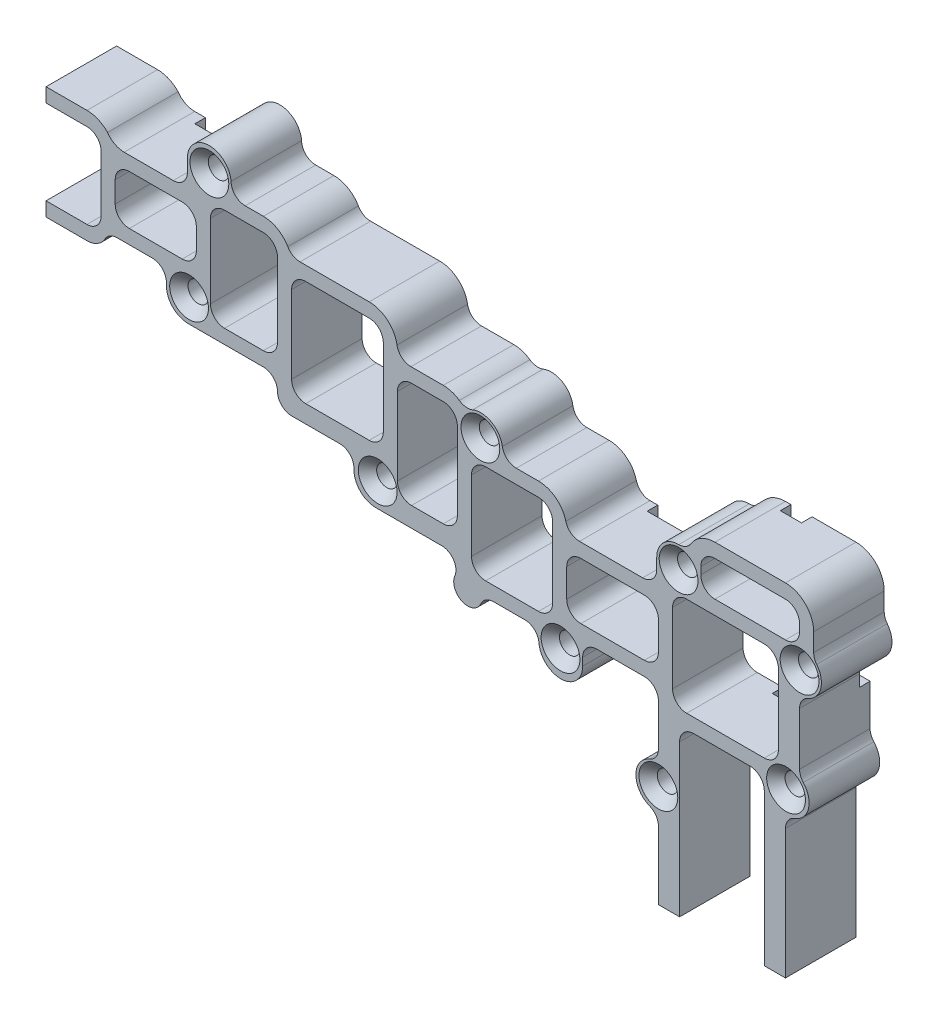
SolidWorks part; units mm, degrees
ref_plane "Спереди" through (0, 0, 0) normal (0, 0, 1) x (1, 0, 0)
ref_plane "Сверху" through (0, 0, 0) normal (0, 1, 0) x (1, 0, 0)
ref_plane "Справа" through (0, 0, 0) normal (1, 0, 0) x (0, 0, -1)
sketch "Board" [suppressed] plane through (0, 0, 0) normal (0, 0, 1) x (1, 0, 0)
  line L0 (0, -10) -> (83.2971, -10)
  line L1 (115, 65) -> (115, 0)
  line L2 (84.5, -10.5) -> (89.9, -10.5)
  line L4 (0, 75) -> (105, 75)
  line L5 (91.1071, -10) -> (105, -10)
  line L7 (-10, 0) -> (-10, 36.1)
  line L8 (-10.5, 37.3) -> (-10.5, 42.7)
  line L9 (-10, 43.91) -> (-10, 65)
  arc A20 (84.5, -10.5) -> (83.2971, -10) centre (83.2929, -11.7071) ccw
  arc A23 (91.1071, -10) -> (89.9, -10.5) centre (91.1071, -11.7071) ccw
  arc A26 (115, 65) -> (105, 75) centre (105, 65) ccw
  arc A29 (105, -10) -> (115, 0) centre (105, 0) ccw
  arc A32 (0, 75) -> (-10, 65) centre (0, 65) ccw
  arc A35 (-10, 0) -> (0, -10) centre (0, 0) ccw
  arc A38 (-10.5, 42.7) -> (-10, 43.91) centre (-11.7071, 43.9071) ccw
  arc A41 (-10, 36.1) -> (-10.5, 37.3) centre (-11.7071, 36.0929) ccw
  point P2 (0, 0)
  point P3 (0, 0)
  dimension "D6" = 10
  dimension "D7" = 125
  dimension "D12" = 10
  dimension "D20" = 1.7071
  dimension "D21" = 1.3366
  dimension "D1" = 85
  dimension "D2" = 10
  dimension "D3" = 10
  dimension "D4" = 10
  dimension "D5" = 10
  dimension "D8" = 0.5
  dimension "D9" = 0.5
  dimension "D10" = 5.4
  dimension "D11" = 32.3
  dimension "D13" = 10
  dimension "D14" = 10
  dimension "D15" = 10
  dimension "D16" = 38.9
  dimension "D17" = 25.1
  dimension "D18" = 7.81
  dimension "D19" = 7.81
sketch "Elements" plane through (0, 0, 0) normal (0, 0, 1) x (1, 0, 0)
  line L0 (76.3, 23.8483) -> (77.025, 23.8402)
  line L1 (77.025, 23.8402) -> (81.875, 23.8483)
  line L2 (87.2, 1.5) -> (87.2023, 2.225)
  line L3 (87.2023, 2.225) -> (87.25, 18.4733)
  line L4 (62.825, 23.85) -> (64.4, 23.849)
  line L5 (64.4, 23.849) -> (65.125, 23.8483)
  line L6 (48.7375, 46.0858) -> (81.9325, 46.0858)
  line L7 (45.63, 49.1933) -> (45.63, 49.2483)
  line L8 (45.63, 49.1933) -> (48.7375, 46.0858)
  line L9 (88.3397, 54.4386) -> (88.405, 54.3733)
  line L10 (88.3397, 54.9136) -> (88.3397, 54.4386)
  line L11 (87.685, 55.5683) -> (88.3397, 54.9136)
  line L12 (70, 63.5) -> (80.1611, 63.5)
  line L13 (70, 60.96) -> (81.9233, 60.96)
  line L14 (67.1588, 43.6595) -> (40.1793, 43.6595)
  line L15 (36.0819, 47.6397) -> (40.1793, 43.6595)
  line L16 (44.615, 53.2583) -> (44.615, 55.7983)
  line L17 (44.615, 55.7983) -> (44.615, 56.7983)
  line L18 (35.115, 53.2583) -> (35.115, 55.7983)
  line L19 (35.115, 55.7983) -> (35.115, 56.7983)
  line L20 (92.6749, 34.4483) -> (92.6874, 34.4358)
  line L21 (93.8674, 34.4358) -> (93.8799, 34.4233)
  line L22 (88.9749, 34.4483) -> (91.2749, 34.4483)
  line L23 (92.6874, 34.4358) -> (93.8674, 34.4358)
  line L24 (91.2749, 34.4483) -> (92.6749, 34.4483)
  line L25 (94.7999, 34.4233) -> (95.8749, 34.4233)
  line L26 (91.5, 44.7633) -> (91.565, 44.8282)
  line L27 (82.8525, 46.0858) -> (82.865, 46.0733)
  line L28 (91.565, 44.8282) -> (98.675, 51.9382)
  line L29 (82.865, 46.0733) -> (83.875, 46.0733)
  line L30 (88.405, 44.9556) -> (88.405, 48.9233)
  line L31 (83.8875, 46.0608) -> (83.9125, 46.0608)
  line L32 (83.9125, 46.0608) -> (85.1413, 47.2895)
  line L33 (87.135, 48.4483) -> (87.135, 48.9233)
  line L34 (83.875, 46.0733) -> (83.8875, 46.0608)
  line L35 (85.9763, 47.2895) -> (87.135, 48.4483)
  line L36 (85.1413, 47.2895) -> (85.9763, 47.2895)
  line L37 (85.865, 48.5583) -> (85.875, 48.5483)
  line L38 (85.865, 48.5583) -> (85.865, 48.9233)
  line L39 (88.4075, 43.8081) -> (88.41, 43.8056)
  line L40 (88.4075, 43.8081) -> (88.4075, 44.9531)
  line L41 (91.3702, 44.8931) -> (91.5, 44.7633)
  line L42 (91.3702, 43.8531) -> (91.3702, 44.8931)
  line L43 (88.405, 44.9556) -> (88.4075, 44.9531)
  line L44 (91.3702, 42.9331) -> (91.3827, 42.9206)
  line L45 (88.41, 42.7256) -> (88.41, 43.8056)
  line L46 (87.9749, 36.2983) -> (87.9749, 40.1957)
  line L47 (88.4749, 36.2983) -> (88.4749, 40.6907)
  line L48 (88.9749, 36.2483) -> (88.9749, 39.3478)
  line L49 (88.9749, 39.3478) -> (91.3952, 41.7681)
  line L50 (87.465, 40.7056) -> (87.9749, 40.1957)
  line L51 (87.465, 40.7056) -> (87.465, 40.7306)
  line L52 (88.4225, 40.7431) -> (88.4749, 40.6907)
  line L53 (95.745, 54.3633) -> (95.75, 54.3683)
  line L54 (93.805, 54.3683) -> (94.82, 54.3683)
  line L55 (94.82, 54.3683) -> (94.825, 54.3633)
  line L56 (93.8, 54.3733) -> (93.805, 54.3683)
  line L57 (93.8, 54.4258) -> (93.8125, 54.4383)
  line L58 (93.8, 54.3733) -> (93.8, 54.4258)
  line L59 (93.8125, 54.4383) -> (93.8125, 62.8625)
  line L60 (93.75, 62.925) -> (93.8125, 62.8625)
  line L61 (89.675, 54.3733) -> (93.8, 54.3733)
  line L62 (97, 54.3733) -> (97.0063, 54.3795)
  line L63 (98.675, 51.9382) -> (98.675, 54.3858)
  line L64 (97.0063, 54.3795) -> (98.6688, 54.3795)
  line L65 (96.995, 54.3683) -> (97, 54.3733)
  line L66 (95.75, 54.3683) -> (96.995, 54.3683)
  line L67 (98.6688, 54.3795) -> (98.675, 54.3858)
  line L68 (89.275, 62.775) -> (89.5, 62.775)
  line L69 (87.135, 54.3733) -> (87.135, 55.7483)
  line L70 (87.685, 55.5683) -> (87.685, 55.9761)
  line L71 (91.3952, 41.7681) -> (91.3952, 41.7931)
  line L72 (88.4225, 40.7431) -> (88.4225, 41.7931)
  line L73 (88.41, 41.8056) -> (88.4225, 41.7931)
  line L74 (91.3827, 41.8056) -> (91.3827, 42.9206)
  line L75 (91.3827, 41.8056) -> (91.3952, 41.7931)
  line L76 (81.9233, 60.96) -> (87.135, 55.7483)
  line L77 (89.25, 72.075) -> (93.75, 72.075)
  line L78 (93.75, 62.925) -> (93.75, 72.075)
  line L79 (80.1611, 63.5) -> (87.685, 55.9761)
  line L80 (95.8749, 34.4233) -> (97.45, 34.4233)
  line L81 (71.5, 25.0233) -> (71.5088, 25.0233)
  line L82 (71.5088, 28.1233) -> (71.645, 28.1233)
  line L83 (71.645, 30.4733) -> (71.645, 33.3733)
  line L84 (71.5088, 25.0233) -> (71.5088, 28.1233)
  line L85 (71.645, 33.3733) -> (71.75, 33.3733)
  line L86 (71.645, 28.1233) -> (71.645, 30.4733)
  line L87 (70.25, 33.3733) -> (70.355, 33.3733)
  line L88 (70.4913, 25.0233) -> (70.4913, 28.1233)
  line L89 (70.4913, 28.1233) -> (70.4913, 30.4733)
  line L90 (70.355, 30.4733) -> (70.4913, 30.4733)
  line L91 (70.4913, 25.0233) -> (70.5, 25.0233)
  line L92 (70.355, 30.4733) -> (70.355, 33.3733)
  line L93 (67.1588, 43.6595) -> (71.43, 39.3883)
  line L94 (71.43, 39.3883) -> (71.5, 39.3883)
  line L95 (70.25, 33.3733) -> (70.25, 35.8908)
  line L96 (70.25, 35.8908) -> (70.555, 36.1958)
  line L97 (71.475, 36.2233) -> (71.4875, 36.2358)
  line L98 (71.75, 33.3733) -> (71.75, 35.9208)
  line L99 (71.475, 36.1958) -> (71.475, 36.2233)
  line L100 (71.475, 36.1958) -> (71.75, 35.9208)
  line L101 (71.4875, 37.8358) -> (71.5, 37.8483)
  line L102 (70.555, 36.1958) -> (70.555, 36.2233)
  line L103 (71.4875, 36.2358) -> (71.4875, 37.8358)
  line L104 (24.625, 67.325) -> (27.178, 64.772)
  line L105 (27.178, 64.772) -> (37.6738, 64.772)
  line L106 (37.655, 60.6483) -> (37.665, 60.6583)
  line L107 (37.665, 60.6583) -> (37.665, 61.1983)
  line L108 (37.6738, 64.772) -> (37.675, 64.7733)
  line L109 (-6.3, 40) -> (0.325, 39.9556)
  line L110 (0.325, 39.9556) -> (1.05, 39.9483)
  line L111 (-7.05, 40) -> (-5.025, 39.975)
  line L112 (54.175, 50.3533) -> (54.175, 52.2233)
  line L113 (54.1916, 50.3366) -> (55.7634, 50.3366)
  line L114 (55.7634, 50.3366) -> (55.775, 50.325)
  line L115 (54.18, 50.3483) -> (54.1916, 50.3366)
  line L116 (18.3117, 54.8383) -> (25.5689, 47.5811)
  line L117 (7.5, 54.8383) -> (18.3117, 54.8383)
  line L118 (25.5689, 47.5811) -> (36.0233, 47.5811)
  line L119 (45.63, 49.2483) -> (45.6375, 49.2558)
  line L120 (36.1405, 47.6983) -> (36.1405, 49.2733)
  line L121 (55.6775, 61.1778) -> (55.6775, 64.7708)
  line L122 (51.87, 60.6483) -> (51.87, 61.1769)
  line L123 (51.87, 61.1769) -> (51.875, 61.1819)
  line L124 (47.18, 61.1905) -> (47.18, 64.7483)
  line L125 (43.345, 61.1683) -> (43.35, 61.1733)
  line L126 (43.345, 60.6483) -> (43.345, 61.1683)
  line L127 (37.665, 61.1983) -> (37.665, 64.7633)
  line L128 (33.825, 61.1483) -> (33.845, 61.1283)
  line L129 (33.845, 60.6483) -> (33.845, 61.1283)
  line L130 (54.175, 50.3533) -> (54.18, 50.3483)
  line L131 (36.0233, 47.5811) -> (36.1405, 47.6983)
  line L132 (45.645, 52.1733) -> (45.645, 52.2283)
  line L133 (44.615, 53.2583) -> (45.645, 52.2283)
  line L134 (47.2063, 64.772) -> (55.6763, 64.772)
  line L135 (47.205, 64.7733) -> (47.2063, 64.772)
  line L136 (55.6763, 64.772) -> (55.6775, 64.7708)
  line L137 (43.345, 55.7983) -> (44.615, 55.7983)
  line L138 (33.845, 55.7983) -> (35.115, 55.7983)
  line L139 (51.87, 55.7983) -> (53.14, 55.7983)
  line L140 (53.14, 53.2583) -> (54.175, 52.2233)
  line L141 (53.14, 53.2583) -> (53.14, 56.7983)
  line L142 (33.845, 55.0832) -> (33.845, 55.7983)
  line L143 (36.145, 52.1733) -> (36.145, 52.2283)
  line L144 (35.115, 53.2583) -> (36.145, 52.2283)
  line L145 (43.2902, 64.7733) -> (47.205, 64.7733)
  line L146 (37.675, 64.7733) -> (43.2902, 64.7733)
  line L147 (43.2902, 64.7733) -> (43.345, 64.7184)
  line L148 (37.665, 64.7633) -> (37.6738, 64.772)
  line L149 (47.18, 64.7483) -> (47.205, 64.7733)
  line L150 (36.1428, 52.171) -> (36.145, 52.1733)
  line L151 (36.1428, 49.2755) -> (36.1428, 52.171)
  line L152 (36.1405, 49.2733) -> (36.1428, 49.2755)
  line L153 (55.68, 52.1733) -> (55.68, 56.7983)
  line L154 (37.655, 52.1733) -> (37.655, 56.7983)
  line L155 (45.6375, 52.1658) -> (45.645, 52.1733)
  line L156 (45.6375, 49.2558) -> (45.6375, 52.1658)
  line L157 (47.155, 52.1733) -> (47.155, 56.7983)
  line L158 (7.4, 41.1233) -> (7.4, 43.4733)
  line L159 (6.375, 41.1836) -> (6.375, 43.4733)
  line L160 (12.25, 39.9483) -> (16.75, 39.9943)
  line L161 (7.31, 53.2983) -> (7.5, 53.2983)
  line L162 (7.31, 51.4733) -> (7.31, 53.2983)
  line L163 (6.075, 48.9733) -> (6.075, 50.7128)
  line L164 (7.575, 48.9733) -> (7.575, 50.8335)
  line L165 (6.2, 45.9733) -> (6.2, 48.6715)
  line L166 (7.475, 45.9733) -> (7.475, 48.7318)
  line L167 (6.2, 43.8958) -> (6.2, 45.9733)
  line L168 (7.4, 43.4733) -> (7.4, 45.7922)
  line L169 (73.35, 23.265) -> (73.35, 24.46)
  line L170 (73.35, 24.46) -> (73.35, 24.7102)
  line L171 (73.35, 24.7102) -> (73.4476, 25.2009)
  line L172 (73.4476, 25.2009) -> (73.6391, 25.6631)
  line L173 (73.6391, 25.6631) -> (73.9171, 26.0792)
  line L174 (73.9171, 26.0792) -> (74.2708, 26.4329)
  line L175 (74.2708, 26.4329) -> (74.6869, 26.7109)
  line L176 (74.6869, 26.7109) -> (75.1491, 26.9024)
  line L177 (75.1491, 26.9024) -> (75.6398, 27)
  line L178 (75.6398, 27) -> (75.89, 27)
  line L179 (75.89, 27) -> (83.0472, 27)
  line L180 (83.0472, 27) -> (83.2321, 27)
  line L181 (83.2321, 27) -> (83.5949, 26.9278)
  line L182 (83.5949, 26.9278) -> (83.9367, 26.7863)
  line L183 (83.9367, 26.7863) -> (84.2442, 26.5808)
  line L184 (84.2442, 26.5808) -> (84.375, 26.45)
  line L185 (84.375, 26.45) -> (89.872, 20.953)
  line L186 (89.872, 20.953) -> (89.8846, 20.9404)
  line L187 (89.8846, 20.9404) -> (89.9044, 20.9108)
  line L188 (89.9044, 20.9108) -> (89.918, 20.8778)
  line L189 (89.918, 20.8778) -> (89.925, 20.8428)
  line L190 (89.925, 20.8428) -> (89.925, 20.825)
  line L191 (89.925, 20.825) -> (90.0379, 20.7121)
  line L192 (90.0379, 20.7121) -> (90.2154, 20.4464)
  line L193 (90.2154, 20.4464) -> (90.3377, 20.1513)
  line L194 (90.3377, 20.1513) -> (90.4, 19.838)
  line L195 (90.4, 19.838) -> (90.4, 19.6782)
  line L196 (90.4, 19.6782) -> (90.4, -9.4793)
  line L197 (90.4, -9.4793) -> (90.4, -9.4961)
  line L198 (90.4, -9.4961) -> (90.3934, -9.5291)
  line L199 (90.3934, -9.5291) -> (90.3806, -9.5602)
  line L200 (90.3806, -9.5602) -> (90.3619, -9.5881)
  line L201 (90.3619, -9.5881) -> (90.35, -9.6)
  line L202 (90.35, -9.6) -> (90.3754, -9.6254)
  line L203 (90.3754, -9.6254) -> (90.4154, -9.6852)
  line L204 (90.4154, -9.6852) -> (90.4429, -9.7517)
  line L205 (90.4429, -9.7517) -> (90.457, -9.8223)
  line L206 (90.457, -9.8223) -> (90.457, -9.8582)
  line L207 (90.457, -9.8582) -> (90.457, -10.1376)
  line L208 (90.457, -10.1376) -> (90.4109, -10.1398)
  line L209 (90.4109, -10.1398) -> (90.3206, -10.1578)
  line L210 (90.3206, -10.1578) -> (90.2356, -10.193)
  line L211 (90.2356, -10.193) -> (90.159, -10.2442)
  line L212 (90.159, -10.2442) -> (90.1249, -10.2751)
  line L213 (90.1249, -10.2751) -> (84.5, -10.5)
  line L214 (84.5, -10.5) -> (84.4753, -10.5)
  line L215 (84.4753, -10.5) -> (84.4268, -10.4904)
  line L216 (84.4268, -10.4904) -> (84.3811, -10.4715)
  line L217 (84.3811, -10.4715) -> (84.34, -10.444)
  line L218 (84.34, -10.444) -> (84.3225, -10.4265)
  line L219 (84.3225, -10.4265) -> (84.0976, -10.2016)
  line L220 (84.0976, -10.2016) -> (84.0863, -10.1903)
  line L221 (84.0863, -10.1903) -> (84.0685, -10.1636)
  line L222 (84.0685, -10.1636) -> (84.0562, -10.1341)
  line L223 (84.0562, -10.1341) -> (84.05, -10.1027)
  line L224 (84.05, -10.1027) -> (84.05, -10.0867)
  line L225 (84.05, -10.0867) -> (84.05, -4.5)
  line L226 (84.05, -4.5) -> (84.0613, -4.4876)
  line L227 (84.0613, -4.4876) -> (84.0798, -4.4598)
  line L228 (84.0798, -4.4598) -> (84.0926, -4.4289)
  line L229 (84.0926, -4.4289) -> (84.0992, -4.396)
  line L230 (84.0992, -4.396) -> (84.1, -4.3793)
  line L231 (84.1, -4.3793) -> (84.1, 18.775)
  line L232 (84.1, 18.775) -> (82.4268, 20.4482)
  line L233 (82.4268, 20.4482) -> (82.3829, 20.488)
  line L234 (82.3829, 20.488) -> (82.2845, 20.5537)
  line L235 (82.2845, 20.5537) -> (82.1752, 20.599)
  line L236 (82.1752, 20.599) -> (82.0592, 20.6221)
  line L237 (82.0592, 20.6221) -> (82, 20.625)
  line L238 (82, 20.625) -> (76.4914, 20.625)
  line L239 (76.4914, 20.625) -> (76.4578, 20.625)
  line L240 (76.4578, 20.625) -> (76.3918, 20.6381)
  line L241 (76.3918, 20.6381) -> (76.3297, 20.6639)
  line L242 (76.3297, 20.6639) -> (76.2738, 20.7012)
  line L243 (76.2738, 20.7012) -> (76.25, 20.725)
  line L244 (76.25, 20.725) -> (75.89, 20.725)
  line L245 (75.89, 20.725) -> (75.6398, 20.725)
  line L246 (75.6398, 20.725) -> (75.1491, 20.8226)
  line L247 (75.1491, 20.8226) -> (74.6869, 21.0141)
  line L248 (74.6869, 21.0141) -> (74.2708, 21.2921)
  line L249 (74.2708, 21.2921) -> (73.9171, 21.6458)
  line L250 (73.9171, 21.6458) -> (73.6391, 22.0619)
  line L251 (73.6391, 22.0619) -> (73.4476, 22.5241)
  line L252 (73.4476, 22.5241) -> (73.35, 23.0148)
  line L253 (73.35, 23.0148) -> (73.35, 23.265)
  line L254 (88.585, 33.6733) -> (87.365, 33.6733)
  line L255 (87.365, 33.6733) -> (87.1148, 33.6733)
  line L256 (87.1148, 33.6733) -> (86.6241, 33.5757)
  line L257 (86.6241, 33.5757) -> (86.1619, 33.3842)
  line L258 (86.1619, 33.3842) -> (85.7458, 33.1062)
  line L259 (85.7458, 33.1062) -> (85.3921, 32.7524)
  line L260 (85.3921, 32.7524) -> (85.1141, 32.3364)
  line L261 (85.1141, 32.3364) -> (84.9226, 31.8742)
  line L262 (84.9226, 31.8742) -> (84.825, 31.3834)
  line L263 (84.825, 31.3834) -> (84.825, 31.1333)
  line L264 (84.825, 31.1333) -> (84.825, 29.2705)
  line L265 (84.825, 29.2705) -> (84.8141, 29.048)
  line L266 (84.8141, 29.048) -> (84.7272, 28.6114)
  line L267 (84.7272, 28.6114) -> (84.5569, 28.2002)
  line L268 (84.5569, 28.2002) -> (84.3096, 27.8301)
  line L269 (84.3096, 27.8301) -> (83.9949, 27.5154)
  line L270 (83.9949, 27.5154) -> (83.6248, 27.2681)
  line L271 (83.6248, 27.2681) -> (83.2136, 27.0978)
  line L272 (83.2136, 27.0978) -> (82.777, 27.0109)
  line L273 (82.777, 27.0109) -> (82.5545, 27)
  line L274 (82.5545, 27) -> (82.4334, 27)
  line L275 (82.4334, 27) -> (82.1958, 26.9528)
  line L276 (82.1958, 26.9528) -> (81.9721, 26.8601)
  line L277 (81.9721, 26.8601) -> (81.7707, 26.7255)
  line L278 (81.7707, 26.7255) -> (81.5995, 26.5543)
  line L279 (81.5995, 26.5543) -> (81.4649, 26.3529)
  line L280 (81.4649, 26.3529) -> (81.3723, 26.1292)
  line L281 (81.3723, 26.1292) -> (81.325, 25.8916)
  line L282 (81.325, 25.8916) -> (81.325, 25.7706)
  line L283 (81.325, 25.7706) -> (81.325, 22.1071)
  line L284 (81.325, 22.1071) -> (81.325, 21.9963)
  line L285 (81.325, 21.9963) -> (81.4098, 21.7915)
  line L286 (81.4098, 21.7915) -> (81.5665, 21.6348)
  line L287 (81.5665, 21.6348) -> (81.7713, 21.55)
  line L288 (81.7713, 21.55) -> (81.8821, 21.55)
  line L289 (81.8821, 21.55) -> (85.585, 21.55)
  line L290 (85.585, 21.55) -> (85.834, 21.5378)
  line L291 (85.834, 21.5378) -> (86.3223, 21.4406)
  line L292 (86.3223, 21.4406) -> (86.7823, 21.2501)
  line L293 (86.7823, 21.2501) -> (87.1964, 20.9734)
  line L294 (87.1964, 20.9734) -> (87.5484, 20.6214)
  line L295 (87.5484, 20.6214) -> (87.8251, 20.2073)
  line L296 (87.8251, 20.2073) -> (88.0156, 19.7473)
  line L297 (88.0156, 19.7473) -> (88.1128, 19.259)
  line L298 (88.1128, 19.259) -> (88.125, 19.01)
  line L299 (88.125, 19.01) -> (88.125, 16.875)
  line L300 (88.125, 16.875) -> (88.125, 16.8203)
  line L301 (88.125, 16.8203) -> (88.1669, 16.7192)
  line L302 (88.1669, 16.7192) -> (88.2442, 16.6419)
  line L303 (88.2442, 16.6419) -> (88.3453, 16.6)
  line L304 (88.3453, 16.6) -> (88.4, 16.6)
  line L305 (88.4, 16.6) -> (90.3688, 16.6)
  line L306 (90.3688, 16.6) -> (90.3688, 19.167)
  line L307 (90.3688, 19.167) -> (90.3798, 19.3906)
  line L308 (90.3798, 19.3906) -> (90.4671, 19.8292)
  line L309 (90.4671, 19.8292) -> (90.6382, 20.2423)
  line L310 (90.6382, 20.2423) -> (90.8866, 20.6141)
  line L311 (90.8866, 20.6141) -> (91.2028, 20.9303)
  line L312 (91.2028, 20.9303) -> (91.5747, 21.1788)
  line L313 (91.5747, 21.1788) -> (91.9878, 21.3499)
  line L314 (91.9878, 21.3499) -> (92.4264, 21.4371)
  line L315 (92.4264, 21.4371) -> (92.65, 21.4481)
  line L316 (92.65, 21.4481) -> (92.8706, 21.4481)
  line L317 (92.8706, 21.4481) -> (93.3033, 21.5342)
  line L318 (93.3033, 21.5342) -> (93.711, 21.7031)
  line L319 (93.711, 21.7031) -> (94.0778, 21.9482)
  line L320 (94.0778, 21.9482) -> (94.3898, 22.2602)
  line L321 (94.3898, 22.2602) -> (94.635, 22.627)
  line L322 (94.635, 22.627) -> (94.8038, 23.0347)
  line L323 (94.8038, 23.0347) -> (94.8899, 23.4674)
  line L324 (94.8899, 23.4674) -> (94.8899, 23.688)
  line L325 (94.8899, 23.688) -> (94.8899, 25.4851)
  line L326 (94.8899, 25.4851) -> (94.8899, 25.7082)
  line L327 (94.8899, 25.7082) -> (94.8028, 26.1458)
  line L328 (94.8028, 26.1458) -> (94.6321, 26.5579)
  line L329 (94.6321, 26.5579) -> (94.3843, 26.9289)
  line L330 (94.3843, 26.9289) -> (94.0688, 27.2444)
  line L331 (94.0688, 27.2444) -> (93.6978, 27.4922)
  line L332 (93.6978, 27.4922) -> (93.2856, 27.663)
  line L333 (93.2856, 27.663) -> (92.8481, 27.75)
  line L334 (92.8481, 27.75) -> (92.625, 27.75)
  line L335 (92.625, 27.75) -> (91.3018, 29.0732)
  line L336 (91.3018, 29.0732) -> (91.262, 29.1171)
  line L337 (91.262, 29.1171) -> (91.1963, 29.2155)
  line L338 (91.1963, 29.2155) -> (91.151, 29.3248)
  line L339 (91.151, 29.3248) -> (91.1279, 29.4408)
  line L340 (91.1279, 29.4408) -> (91.125, 29.5)
  line L341 (91.125, 29.5) -> (91.125, 31.1333)
  line L342 (91.125, 31.1333) -> (91.125, 31.3834)
  line L343 (91.125, 31.3834) -> (91.0274, 31.8742)
  line L344 (91.0274, 31.8742) -> (90.8359, 32.3364)
  line L345 (90.8359, 32.3364) -> (90.5579, 32.7524)
  line L346 (90.5579, 32.7524) -> (90.2042, 33.1062)
  line L347 (90.2042, 33.1062) -> (89.7881, 33.3842)
  line L348 (89.7881, 33.3842) -> (89.3259, 33.5757)
  line L349 (89.3259, 33.5757) -> (88.8352, 33.6733)
  line L350 (88.8352, 33.6733) -> (88.585, 33.6733)
  line L351 (68.625, 27.325) -> (68.625, 20.725)
  line L352 (68.625, 20.725) -> (68.6083, 20.5131)
  line L353 (68.6083, 20.5131) -> (68.5197, 20.0972)
  line L354 (68.5197, 20.0972) -> (68.3776, 19.6965)
  line L355 (68.3776, 19.6965) -> (68.1844, 19.3178)
  line L356 (68.1844, 19.3178) -> (67.9433, 18.9676)
  line L357 (67.9433, 18.9676) -> (67.6585, 18.6519)
  line L358 (67.6585, 18.6519) -> (67.335, 18.3761)
  line L359 (67.335, 18.3761) -> (66.9782, 18.1449)
  line L360 (66.9782, 18.1449) -> (66.5942, 17.9623)
  line L361 (66.5942, 17.9623) -> (66.1897, 17.8314)
  line L362 (66.1897, 17.8314) -> (65.7715, 17.7546)
  line L363 (65.7715, 17.7546) -> (65.3469, 17.733)
  line L364 (65.3469, 17.733) -> (65.135, 17.75)
  line L365 (65.135, 17.75) -> (61.9543, 17.75)
  line L366 (61.9543, 17.75) -> (17.125, 33.925)
  line L367 (17.125, 33.925) -> (11.84, 33.925)
  line L368 (11.84, 33.925) -> (11.5898, 33.925)
  line L369 (11.5898, 33.925) -> (11.0991, 34.0226)
  line L370 (11.0991, 34.0226) -> (10.6369, 34.2141)
  line L371 (10.6369, 34.2141) -> (10.2209, 34.492)
  line L372 (10.2209, 34.492) -> (9.8671, 34.8458)
  line L373 (9.8671, 34.8458) -> (9.5891, 35.2618)
  line L374 (9.5891, 35.2618) -> (9.3976, 35.7241)
  line L375 (9.3976, 35.7241) -> (9.3, 36.2148)
  line L376 (9.3, 36.2148) -> (9.3, 36.465)
  line L377 (9.3, 36.465) -> (9.3, 43.535)
  line L378 (9.3, 43.535) -> (9.3, 43.7852)
  line L379 (9.3, 43.7852) -> (9.3976, 44.2759)
  line L380 (9.3976, 44.2759) -> (9.5891, 44.7381)
  line L381 (9.5891, 44.7381) -> (9.8671, 45.1541)
  line L382 (9.8671, 45.1541) -> (10.2209, 45.5079)
  line L383 (10.2209, 45.5079) -> (10.6369, 45.7859)
  line L384 (10.6369, 45.7859) -> (11.0991, 45.9774)
  line L385 (11.0991, 45.9774) -> (11.5898, 46.075)
  line L386 (11.5898, 46.075) -> (11.84, 46.075)
  line L387 (11.84, 46.075) -> (18.225, 46.075)
  line L388 (18.225, 46.075) -> (63.375, 29.95)
  line L389 (63.375, 29.95) -> (65.135, 29.95)
  line L390 (65.135, 29.95) -> (65.3354, 29.9783)
  line L391 (65.3354, 29.9783) -> (65.7402, 29.9822)
  line L392 (65.7402, 29.9822) -> (66.142, 29.9333)
  line L393 (66.142, 29.9333) -> (66.534, 29.8323)
  line L394 (66.534, 29.8323) -> (66.9094, 29.681)
  line L395 (66.9094, 29.681) -> (67.2619, 29.482)
  line L396 (67.2619, 29.482) -> (67.5854, 29.2386)
  line L397 (67.5854, 29.2386) -> (67.8744, 28.9552)
  line L398 (67.8744, 28.9552) -> (68.1239, 28.6364)
  line L399 (68.1239, 28.6364) -> (68.3296, 28.2878)
  line L400 (68.3296, 28.2878) -> (68.4881, 27.9154)
  line L401 (68.4881, 27.9154) -> (68.5966, 27.5254)
  line L402 (68.5966, 27.5254) -> (68.625, 27.325)
  line L403 (4.606, 39.2733) -> (4.606, 40.4933)
  line L404 (4.606, 40.4933) -> (4.606, 40.7435)
  line L405 (4.606, 40.7435) -> (4.5084, 41.2342)
  line L406 (4.5084, 41.2342) -> (4.3169, 41.6964)
  line L407 (4.3169, 41.6964) -> (4.0389, 42.1125)
  line L408 (4.0389, 42.1125) -> (3.6851, 42.4663)
  line L409 (3.6851, 42.4663) -> (3.2691, 42.7442)
  line L410 (3.2691, 42.7442) -> (2.8069, 42.9357)
  line L411 (2.8069, 42.9357) -> (2.3161, 43.0333)
  line L412 (2.3161, 43.0333) -> (2.066, 43.0333)
  line L413 (2.066, 43.0333) -> (-10.5, 43.0333)
  line L414 (-10.5, 43.0333) -> (-10.5, 36.7333)
  line L415 (-10.5, 36.7333) -> (2.066, 36.7333)
  line L416 (2.066, 36.7333) -> (2.3161, 36.7333)
  line L417 (2.3161, 36.7333) -> (2.8069, 36.8309)
  line L418 (2.8069, 36.8309) -> (3.2691, 37.0224)
  line L419 (3.2691, 37.0224) -> (3.6851, 37.3004)
  line L420 (3.6851, 37.3004) -> (4.0389, 37.6542)
  line L421 (4.0389, 37.6542) -> (4.3169, 38.0702)
  line L422 (4.3169, 38.0702) -> (4.5084, 38.5324)
  line L423 (4.5084, 38.5324) -> (4.606, 39.0231)
  line L424 (4.606, 39.0231) -> (4.606, 39.2733)
  line L425 (93.8999, 25.1483) -> (93.8999, 24.0483)
  line L426 (93.8999, 24.0483) -> (92.7999, 24.0483)
  line L427 (92.7999, 24.0483) -> (92.7999, 25.1483)
  line L428 (92.7999, 25.1483) -> (93.8999, 25.1483)
  line L429 (88.5249, 30.5233) -> (88.5249, 29.4233)
  line L430 (88.5249, 29.4233) -> (87.4249, 29.4233)
  line L431 (87.4249, 29.4233) -> (87.4249, 30.5233)
  line L432 (87.4249, 30.5233) -> (88.5249, 30.5233)
  line L433 (87.8, 19.0233) -> (87.8, 17.9233)
  line L434 (87.8, 17.9233) -> (86.7, 17.9233)
  line L435 (86.7, 17.9233) -> (86.7, 19.0233)
  line L436 (86.7, 19.0233) -> (87.8, 19.0233)
  line L437 (82.425, 24.3983) -> (82.425, 23.2983)
  line L438 (82.425, 23.2983) -> (81.325, 23.2983)
  line L439 (81.325, 23.2983) -> (81.325, 24.3983)
  line L440 (81.325, 24.3983) -> (82.425, 24.3983)
  line L441 (81.325, 23.2983) -> (81.325, 24.3983)
  line L442 (81.325, 24.3983) -> (82.5545, 24.3983)
  line L443 (82.5545, 24.3983) -> (83.6246, 23.9659)
  line L444 (83.6246, 23.9659) -> (87.35, 20.2483)
  line L445 (87.35, 20.2483) -> (87.8, 19.1733)
  line L446 (87.8, 19.1733) -> (87.8, 17.9233)
  line L447 (87.8, 17.9233) -> (86.7, 17.9233)
  line L448 (86.7, 17.9233) -> (86.7, 19.3233)
  line L449 (86.7, 19.3233) -> (86.575, 19.4483)
  line L450 (86.575, 19.4483) -> (82.8467, 23.1881)
  line L451 (82.8467, 23.1881) -> (82.725, 23.2983)
  line L452 (82.725, 23.2983) -> (81.325, 23.2983)
  line L453 (87.4248, 29.2734) -> (87.4248, 30.5233)
  line L454 (87.4248, 30.5233) -> (88.525, 30.5233)
  line L455 (88.525, 30.5233) -> (88.5242, 29.0986)
  line L456 (88.5242, 29.0986) -> (88.6451, 28.9864)
  line L457 (88.6451, 28.9864) -> (92.3715, 25.2599)
  line L458 (92.3715, 25.2599) -> (92.4744, 25.1484)
  line L459 (92.4744, 25.1484) -> (93.8999, 25.1484)
  line L460 (93.8999, 25.1484) -> (93.8999, 24.0481)
  line L461 (93.8999, 24.0481) -> (92.65, 24.0481)
  line L462 (92.65, 24.0481) -> (91.5936, 24.4821)
  line L463 (91.5936, 24.4821) -> (87.8672, 28.2085)
  line L464 (87.8672, 28.2085) -> (87.4248, 29.2734)
  line L465 (16.8, 40.546) -> (17.9, 40.546)
  line L466 (17.9, 40.546) -> (17.9, 39.446)
  line L467 (17.9, 39.446) -> (16.8, 39.446)
  line L468 (16.8, 39.446) -> (16.8, 40.546)
  line L469 (62.275, 24.4) -> (63.375, 24.4)
  line L470 (63.375, 24.4) -> (63.375, 23.3)
  line L471 (63.375, 23.3) -> (62.275, 23.3)
  line L472 (62.275, 23.3) -> (62.275, 24.4)
  line L473 (18.2315, 39.4185) -> (16.8, 39.4185)
  line L474 (16.8, 39.4185) -> (16.8, 40.5735)
  line L475 (16.8, 40.5735) -> (18.2315, 40.5735)
  line L476 (18.2315, 40.5735) -> (18.2315, 43.472)
  line L477 (18.2315, 43.472) -> (19.0789, 43.472)
  line L478 (19.0789, 43.472) -> (19.0789, 38.6444)
  line L479 (19.0789, 38.6444) -> (24.3547, 38.6444)
  line L480 (24.3547, 38.6444) -> (24.3547, 37.8496)
  line L481 (24.3547, 37.8496) -> (19.0526, 37.8496)
  line L482 (19.0526, 37.8496) -> (18.2315, 38.6444)
  line L483 (18.2315, 38.6444) -> (18.2315, 39.4185)
  line L484 (29.5999, 36.6358) -> (19.0526, 36.6358)
  line L485 (19.0526, 36.6358) -> (19.0526, 37.4305)
  line L486 (19.0526, 37.4305) -> (29.5999, 37.4305)
  line L487 (29.5999, 37.4305) -> (29.5999, 36.6358)
  line L488 (24.3547, 35.8543) -> (24.3547, 35.0339)
  line L489 (24.3547, 35.0339) -> (34.8451, 35.0324)
  line L490 (34.8451, 35.0324) -> (34.8451, 35.8558)
  line L491 (34.8451, 35.8558) -> (24.3547, 35.8543)
  line L492 (34.8451, 33.2961) -> (29.5999, 33.2961)
  line L493 (29.5999, 33.2961) -> (29.5999, 34.1194)
  line L494 (29.5999, 34.1194) -> (34.8451, 34.1194)
  line L495 (34.8451, 34.1194) -> (34.8451, 34.1197)
  line L496 (34.8451, 34.1197) -> (40.0929, 34.1197)
  line L497 (40.0929, 34.1197) -> (40.0929, 33.2957)
  line L498 (40.0929, 33.2957) -> (34.8451, 33.2957)
  line L499 (34.8451, 33.2957) -> (34.8451, 33.2961)
  line L500 (40.0929, 31.511) -> (34.8451, 31.511)
  line L501 (34.8451, 31.511) -> (34.8451, 32.335)
  line L502 (34.8451, 32.335) -> (40.0929, 32.335)
  line L503 (40.0929, 32.335) -> (45.3407, 32.335)
  line L504 (45.3407, 32.335) -> (45.3407, 31.511)
  line L505 (45.3407, 31.511) -> (40.0929, 31.511)
  line L506 (40.0929, 30.5503) -> (40.0929, 29.7263)
  line L507 (40.0929, 29.7263) -> (45.3407, 29.7263)
  line L508 (45.3407, 29.7263) -> (45.3407, 29.7266)
  line L509 (45.3407, 29.7266) -> (50.5859, 29.7266)
  line L510 (50.5859, 29.7266) -> (50.5859, 30.55)
  line L511 (50.5859, 30.55) -> (45.3407, 30.55)
  line L512 (45.3407, 30.55) -> (45.3407, 30.5503)
  line L513 (45.3407, 30.5503) -> (40.0929, 30.5503)
  line L514 (45.3407, 28.8136) -> (45.3407, 27.9903)
  line L515 (45.3407, 27.9903) -> (50.5859, 27.9903)
  line L516 (50.5859, 27.9903) -> (50.5859, 27.9917)
  line L517 (50.5859, 27.9917) -> (55.8311, 27.9917)
  line L518 (55.8311, 27.9917) -> (55.8311, 28.8121)
  line L519 (55.8311, 28.8121) -> (50.5859, 28.8121)
  line L520 (50.5859, 28.8121) -> (50.5859, 28.8136)
  line L521 (50.5859, 28.8136) -> (45.3407, 28.8136)
  line L522 (61.1332, 26.4155) -> (50.5859, 26.4155)
  line L523 (50.5859, 26.4155) -> (50.5859, 27.21)
  line L524 (50.5859, 27.21) -> (61.1332, 27.2103)
  line L525 (61.1332, 27.2103) -> (61.1332, 26.4155)
  line L526 (61.1069, 20.374) -> (61.1069, 24.4276)
  line L527 (61.1069, 24.4276) -> (61.1069, 25.2016)
  line L528 (61.1069, 25.2016) -> (55.8311, 25.2017)
  line L529 (55.8311, 25.2017) -> (55.8311, 25.9964)
  line L530 (55.8311, 25.9964) -> (61.1332, 25.9964)
  line L531 (61.1332, 25.9964) -> (61.9543, 25.2016)
  line L532 (61.9543, 25.2016) -> (61.9543, 24.4275)
  line L533 (61.9543, 24.4275) -> (63.3858, 24.4275)
  line L534 (63.3858, 24.4275) -> (63.3858, 23.2725)
  line L535 (63.3858, 23.2725) -> (61.9543, 23.2725)
  line L536 (61.9543, 23.2725) -> (61.9543, 20.374)
  line L537 (61.9543, 20.374) -> (61.1069, 20.374)
  line L538 (-0.35, 0) -> (0.35, 0)
  line L539 (0, -0.35) -> (0, 0.35)
  line L540 (104.65, 65) -> (105.35, 65)
  line L541 (105, 64.65) -> (105, 65.35)
  line L542 (104.65, 0) -> (105.35, 0)
  line L543 (105, -0.35) -> (105, 0.35)
  line L544 (-0.35, 65) -> (0.35, 65)
  line L545 (0, 64.65) -> (0, 65.35)
  line L546 (87.2, -10.5) -> (87.2, -9.5)
  line L547 (93.2, -10) -> (93.2, -4.2)
  line L548 (81.2, -4.2) -> (93.2, -4.2)
  line L549 (81.2, -10) -> (81.2, -4.2)
  line L550 (80.2, -10) -> (94.2, -10)
  line L551 (86.65, -9.6) -> (86.65, -4.5)
  line L552 (86.65, -4.5) -> (87.75, -4.5)
  line L553 (87.75, -4.5) -> (87.75, -9.6)
  line L554 (87.75, -9.6) -> (86.65, -9.6)
  line L555 (81.55, -9.6) -> (81.55, -4.5)
  line L556 (81.55, -4.5) -> (84.05, -4.5)
  line L557 (84.05, -4.5) -> (84.05, -9.6)
  line L558 (84.05, -9.6) -> (81.55, -9.6)
  line L559 (90.35, -9.6) -> (90.35, -4.5)
  line L560 (90.35, -4.5) -> (92.85, -4.5)
  line L561 (92.85, -4.5) -> (92.85, -9.6)
  line L562 (92.85, -9.6) -> (90.35, -9.6)
  line L563 (87.25, 1.55) -> (87.25, 1.45)
  line L564 (87.25, 1.45) -> (87.15, 1.45)
  line L565 (87.15, 1.45) -> (87.15, 1.55)
  line L566 (87.15, 1.55) -> (87.25, 1.55)
  line L567 (87.25, -4.45) -> (87.25, -4.55)
  line L568 (87.25, -4.55) -> (87.15, -4.55)
  line L569 (87.15, -4.55) -> (87.15, -4.45)
  line L570 (87.15, -4.45) -> (87.25, -4.45)
  line L571 (86.65, -2.85) -> (86.65, 1.55)
  line L572 (86.65, 1.55) -> (87.75, 1.55)
  line L573 (87.75, 1.55) -> (87.75, -4.55)
  line L574 (87.75, -4.55) -> (86.65, -4.55)
  line L575 (86.65, -4.55) -> (86.65, -3.95)
  line L576 (86.65, -3.95) -> (85.55, -3.95)
  line L577 (85.55, -3.95) -> (85.55, -2.85)
  line L578 (85.55, -2.85) -> (86.65, -2.85)
  line L579 (94.225, 24.265) -> (94.225, 24.935)
  line L580 (93.89, 24.6) -> (94.56, 24.6)
  line L581 (92.855, 25.27) -> (95.595, 25.27)
  line L582 (92.855, 23.93) -> (92.855, 25.27)
  line L583 (92.855, 23.93) -> (95.595, 23.93)
  line L584 (95.595, 23.93) -> (95.595, 25.27)
  line L585 (94.6, 24.8635) -> (94.6, 24.3364)
  line L586 (94.8015, 24.135) -> (95.1886, 24.135)
  line L587 (95.39, 24.3364) -> (95.39, 24.8635)
  line L588 (95.1886, 25.065) -> (94.8015, 25.065)
  line L589 (93.85, 24.3364) -> (93.85, 24.8635)
  line L590 (93.6486, 25.065) -> (93.2614, 25.065)
  line L591 (93.06, 24.8635) -> (93.06, 24.3364)
  line L592 (93.2614, 24.135) -> (93.6486, 24.135)
  line L593 (-10.5, 40) -> (-9.5, 40)
  line L594 (-10, 34) -> (-4.2, 34)
  line L595 (-4.2, 34) -> (-4.2, 46)
  line L596 (-10, 46) -> (-4.2, 46)
  line L597 (-10, 33) -> (-10, 47)
  line L598 (-9.6, 36.85) -> (-4.5, 36.85)
  line L599 (-4.5, 36.85) -> (-4.5, 34.35)
  line L600 (-4.5, 34.35) -> (-9.6, 34.35)
  line L601 (-9.6, 34.35) -> (-9.6, 36.85)
  line L602 (-9.6, 45.65) -> (-4.5, 45.65)
  line L603 (-4.5, 45.65) -> (-4.5, 43.15)
  line L604 (-4.5, 43.15) -> (-9.6, 43.15)
  line L605 (-9.6, 43.15) -> (-9.6, 45.65)
  line L606 (-9.6, 40.55) -> (-4.5, 40.55)
  line L607 (-4.5, 40.55) -> (-4.5, 39.45)
  line L608 (-4.5, 39.45) -> (-9.6, 39.45)
  line L609 (-9.6, 39.45) -> (-9.6, 40.55)
  line L610 (68.23, 59.48) -> (68.23, 64.98)
  line L611 (68.23, 64.98) -> (71.77, 64.98)
  line L612 (71.77, 59.48) -> (71.77, 64.98)
  line L613 (68.23, 59.48) -> (71.77, 59.48)
  line L614 (69.65, 63.5) -> (70.35, 63.5)
  line L615 (70, 63.15) -> (70, 63.85)
  line L616 (69.475, 64.025) -> (70.525, 64.025)
  line L617 (70.525, 64.025) -> (70.525, 62.975)
  line L618 (70.525, 62.975) -> (69.475, 62.975)
  line L619 (69.475, 62.975) -> (69.475, 64.025)
  line L620 (21.025, 83.175) -> (21.025, 84.175)
  line L621 (13.025, 64.975) -> (13.025, 83.675)
  line L622 (13.025, 64.975) -> (29.025, 64.975)
  line L623 (29.025, 64.975) -> (29.025, 83.675)
  line L624 (13.025, 83.675) -> (29.025, 83.675)
  line L625 (21.025, 66.975) -> (21.025, 67.675)
  line L626 (20.675, 67.325) -> (21.375, 67.325)
  line L627 (87.9249, 34.3233) -> (87.9249, 34.4233)
  line L628 (87.9249, 34.4233) -> (88.0249, 34.4233)
  line L629 (88.0249, 34.4233) -> (88.0249, 34.3233)
  line L630 (88.0249, 34.3233) -> (87.9249, 34.3233)
  line L631 (87.9249, 30.4733) -> (87.9249, 30.5733)
  line L632 (87.9249, 30.5733) -> (88.0249, 30.5733)
  line L633 (88.0249, 30.5733) -> (88.0249, 30.4733)
  line L634 (88.0249, 30.4733) -> (87.9249, 30.4733)
  line L635 (90.1249, 32.5733) -> (90.1249, 31.4733)
  line L636 (90.1249, 31.4733) -> (88.5249, 31.4733)
  line L637 (88.5249, 31.4733) -> (88.5249, 30.4733)
  line L638 (88.5249, 30.4733) -> (87.4249, 30.4733)
  line L639 (87.4249, 30.4733) -> (87.4249, 33.6733)
  line L640 (87.4249, 33.6733) -> (87.8249, 33.6733)
  line L641 (87.8249, 33.6733) -> (87.8249, 34.3733)
  line L642 (87.8249, 34.3733) -> (88.1249, 34.3733)
  line L643 (88.1249, 34.3733) -> (88.1249, 33.6733)
  line L644 (88.1249, 33.6733) -> (88.5249, 33.6733)
  line L645 (88.5249, 33.6733) -> (88.5249, 32.5733)
  line L646 (88.5249, 32.5733) -> (90.1249, 32.5733)
  line L647 (76.25, 23.8983) -> (76.35, 23.8983)
  line L648 (76.35, 23.8983) -> (76.35, 23.7983)
  line L649 (76.35, 23.7983) -> (76.25, 23.7983)
  line L650 (76.25, 23.7983) -> (76.25, 23.8983)
  line L651 (72.8, 23.8983) -> (72.9, 23.8983)
  line L652 (72.9, 23.8983) -> (72.9, 23.7983)
  line L653 (72.9, 23.7983) -> (72.8, 23.7983)
  line L654 (72.8, 23.7983) -> (72.8, 23.8983)
  line L655 (74.25, 23.2983) -> (73.35, 23.2983)
  line L656 (73.35, 23.2983) -> (73.35, 23.6983)
  line L657 (73.35, 23.6983) -> (72.85, 23.6983)
  line L658 (72.85, 23.6983) -> (72.85, 23.9983)
  line L659 (72.85, 23.9983) -> (73.35, 23.9983)
  line L660 (73.35, 23.9983) -> (73.35, 24.3983)
  line L661 (73.35, 24.3983) -> (76.35, 24.3983)
  line L662 (76.35, 24.3983) -> (76.35, 23.2983)
  line L663 (76.35, 23.2983) -> (75.35, 23.2983)
  line L664 (75.35, 23.2983) -> (75.35, 21.7983)
  line L665 (75.35, 21.7983) -> (74.25, 21.7983)
  line L666 (74.25, 21.7983) -> (74.25, 23.2983)
  line L667 (69.125, 23.8983) -> (69.225, 23.8983)
  line L668 (69.225, 23.8983) -> (69.225, 23.7983)
  line L669 (69.225, 23.7983) -> (69.125, 23.7983)
  line L670 (69.125, 23.7983) -> (69.125, 23.8983)
  line L671 (65.075, 23.8983) -> (65.175, 23.8983)
  line L672 (65.175, 23.8983) -> (65.175, 23.7983)
  line L673 (65.175, 23.7983) -> (65.075, 23.7983)
  line L674 (65.075, 23.7983) -> (65.075, 23.8983)
  line L675 (67.175, 21.7983) -> (66.075, 21.7983)
  line L676 (66.075, 21.7983) -> (66.075, 23.2983)
  line L677 (66.075, 23.2983) -> (65.075, 23.2983)
  line L678 (65.075, 23.2983) -> (65.075, 24.3983)
  line L679 (65.075, 24.3983) -> (68.675, 24.3983)
  line L680 (68.675, 24.3983) -> (68.675, 23.9983)
  line L681 (68.675, 23.9983) -> (69.175, 23.9983)
  line L682 (69.175, 23.9983) -> (69.175, 23.6983)
  line L683 (69.175, 23.6983) -> (68.675, 23.6983)
  line L684 (68.675, 23.6983) -> (68.675, 23.2983)
  line L685 (68.675, 23.2983) -> (67.175, 23.2983)
  line L686 (67.175, 23.2983) -> (67.175, 21.7983)
  line L687 (12.2, 39.9983) -> (12.3, 39.9983)
  line L688 (12.3, 39.9983) -> (12.3, 39.8983)
  line L689 (12.3, 39.8983) -> (12.2, 39.8983)
  line L690 (12.2, 39.8983) -> (12.2, 39.9983)
  line L691 (8.75, 39.9983) -> (8.85, 39.9983)
  line L692 (8.85, 39.9983) -> (8.85, 39.8983)
  line L693 (8.85, 39.8983) -> (8.75, 39.8983)
  line L694 (8.75, 39.8983) -> (8.75, 39.9983)
  line L695 (10.2, 39.3983) -> (9.3, 39.3983)
  line L696 (9.3, 39.3983) -> (9.3, 39.7983)
  line L697 (9.3, 39.7983) -> (8.8, 39.7983)
  line L698 (8.8, 39.7983) -> (8.8, 40.0983)
  line L699 (8.8, 40.0983) -> (9.3, 40.0983)
  line L700 (9.3, 40.0983) -> (9.3, 40.4983)
  line L701 (9.3, 40.4983) -> (12.3, 40.4983)
  line L702 (12.3, 40.4983) -> (12.3, 39.3983)
  line L703 (12.3, 39.3983) -> (11.3, 39.3983)
  line L704 (11.3, 39.3983) -> (11.3, 37.8983)
  line L705 (11.3, 37.8983) -> (10.2, 37.8983)
  line L706 (10.2, 37.8983) -> (10.2, 39.3983)
  line L707 (5.05, 39.9983) -> (5.15, 39.9983)
  line L708 (5.15, 39.9983) -> (5.15, 39.8983)
  line L709 (5.15, 39.8983) -> (5.05, 39.8983)
  line L710 (5.05, 39.8983) -> (5.05, 39.9983)
  line L711 (1, 39.9983) -> (1.1, 39.9983)
  line L712 (1.1, 39.9983) -> (1.1, 39.8983)
  line L713 (1.1, 39.8983) -> (1, 39.8983)
  line L714 (1, 39.8983) -> (1, 39.9983)
  line L715 (3.1, 37.8983) -> (2, 37.8983)
  line L716 (2, 37.8983) -> (2, 39.3983)
  line L717 (2, 39.3983) -> (1, 39.3983)
  line L718 (1, 39.3983) -> (1, 40.4983)
  line L719 (1, 40.4983) -> (4.6, 40.4983)
  line L720 (4.6, 40.4983) -> (4.6, 40.0983)
  line L721 (4.6, 40.0983) -> (5.1, 40.0983)
  line L722 (5.1, 40.0983) -> (5.1, 39.7983)
  line L723 (5.1, 39.7983) -> (4.6, 39.7983)
  line L724 (4.6, 39.7983) -> (4.6, 39.3983)
  line L725 (4.6, 39.3983) -> (3.1, 39.3983)
  line L726 (3.1, 39.3983) -> (3.1, 37.8983)
  line L727 (88.2, 61.825) -> (94.8, 61.825)
  line L728 (88.2, 73.175) -> (94.8, 73.175)
  line L729 (88.2, 61.825) -> (88.2, 73.175)
  line L730 (94.8, 61.825) -> (94.8, 73.175)
  line L731 (91.5, 67) -> (91.5, 68)
  line L732 (91, 67.5) -> (92, 67.5)
  line L733 (93.3, 72.475) -> (93.3, 71.675)
  line L734 (94.2, 71.675) -> (94.2, 72.475)
  line L735 (88.8, 72.475) -> (88.8, 71.675)
  line L736 (89.7, 71.675) -> (89.7, 72.475)
  line L737 (93.3, 63.325) -> (93.3, 62.525)
  line L738 (94.2, 62.525) -> (94.2, 63.325)
  line L739 (88.8, 63.325) -> (88.8, 62.525)
  line L740 (89.7, 62.525) -> (89.7, 63.325)
  line L741 (81.4925, 46.5358) -> (83.2925, 46.5358)
  line L742 (81.4925, 45.6358) -> (81.4925, 46.5358)
  line L743 (81.4925, 45.6358) -> (83.2925, 45.6358)
  line L744 (83.2925, 45.6358) -> (83.2925, 46.5358)
  line L745 (82.3925, 45.8658) -> (82.3925, 46.3058)
  line L746 (82.1725, 46.0858) -> (82.6125, 46.0858)
  line L747 (83.1425, 45.9466) -> (83.1425, 46.225)
  line L748 (82.9917, 46.3758) -> (82.7133, 46.3758)
  line L749 (82.5625, 46.225) -> (82.5625, 45.9466)
  line L750 (82.7133, 45.7958) -> (82.9917, 45.7958)
  line L751 (82.2225, 45.9466) -> (82.2225, 46.225)
  line L752 (82.0717, 46.3758) -> (81.7933, 46.3758)
  line L753 (81.6425, 46.225) -> (81.6425, 45.9466)
  line L754 (81.7933, 45.7958) -> (82.0717, 45.7958)
  line L755 (94.385, 53.9133) -> (96.185, 53.9133)
  line L756 (96.185, 53.9133) -> (96.185, 54.8133)
  line L757 (94.385, 54.8133) -> (96.185, 54.8133)
  line L758 (94.385, 53.9133) -> (94.385, 54.8133)
  line L759 (95.285, 54.1433) -> (95.285, 54.5833)
  line L760 (95.065, 54.3633) -> (95.505, 54.3633)
  line L761 (94.535, 54.5025) -> (94.535, 54.2241)
  line L762 (94.6858, 54.0733) -> (94.9642, 54.0733)
  line L763 (95.115, 54.2241) -> (95.115, 54.5025)
  line L764 (94.9642, 54.6533) -> (94.6858, 54.6533)
  line L765 (95.455, 54.5025) -> (95.455, 54.2241)
  line L766 (95.6058, 54.0733) -> (95.8842, 54.0733)
  line L767 (96.035, 54.2241) -> (96.035, 54.5025)
  line L768 (95.8842, 54.6533) -> (95.6058, 54.6533)
  line L769 (87.05, 43.3556) -> (88.85, 43.3556)
  line L770 (88.85, 43.3556) -> (88.85, 44.2556)
  line L771 (87.05, 44.2556) -> (88.85, 44.2556)
  line L772 (87.05, 43.3556) -> (87.05, 44.2556)
  line L773 (87.95, 43.5856) -> (87.95, 44.0256)
  line L774 (87.73, 43.8056) -> (88.17, 43.8056)
  line L775 (87.2, 43.9448) -> (87.2, 43.6664)
  line L776 (87.3508, 43.5156) -> (87.6292, 43.5156)
  line L777 (87.78, 43.6664) -> (87.78, 43.9448)
  line L778 (87.6292, 44.0956) -> (87.3508, 44.0956)
  line L779 (88.12, 43.9448) -> (88.12, 43.6664)
  line L780 (88.2708, 43.5156) -> (88.5492, 43.5156)
  line L781 (88.7, 43.6664) -> (88.7, 43.9448)
  line L782 (88.5492, 44.0956) -> (88.2708, 44.0956)
  line L783 (88.86, 41.3656) -> (88.86, 43.1656)
  line L784 (87.96, 43.1656) -> (88.86, 43.1656)
  line L785 (87.96, 41.3656) -> (87.96, 43.1656)
  line L786 (87.96, 41.3656) -> (88.86, 41.3656)
  line L787 (88.19, 42.2656) -> (88.63, 42.2656)
  line L788 (88.41, 42.0456) -> (88.41, 42.4856)
  line L789 (88.2708, 41.5156) -> (88.5492, 41.5156)
  line L790 (88.7, 41.6664) -> (88.7, 41.9448)
  line L791 (88.5492, 42.0956) -> (88.2708, 42.0956)
  line L792 (88.12, 41.9448) -> (88.12, 41.6664)
  line L793 (88.2708, 42.4356) -> (88.5492, 42.4356)
  line L794 (88.7, 42.5864) -> (88.7, 42.8648)
  line L795 (88.5492, 43.0156) -> (88.2708, 43.0156)
  line L796 (88.12, 42.8648) -> (88.12, 42.5864)
  line L797 (91.8202, 42.4931) -> (91.8202, 44.2931)
  line L798 (90.9202, 44.2931) -> (91.8202, 44.2931)
  line L799 (90.9202, 42.4931) -> (90.9202, 44.2931)
  line L800 (90.9202, 42.4931) -> (91.8202, 42.4931)
  line L801 (91.1502, 43.3931) -> (91.5902, 43.3931)
  line L802 (91.3702, 43.1731) -> (91.3702, 43.6131)
  line L803 (91.231, 42.6431) -> (91.5094, 42.6431)
  line L804 (91.6602, 42.7939) -> (91.6602, 43.0723)
  line L805 (91.5094, 43.2231) -> (91.231, 43.2231)
  line L806 (91.0802, 43.0723) -> (91.0802, 42.7939)
  line L807 (91.231, 43.5631) -> (91.5094, 43.5631)
  line L808 (91.6602, 43.7139) -> (91.6602, 43.9923)
  line L809 (91.5094, 44.1431) -> (91.231, 44.1431)
  line L810 (91.0802, 43.9923) -> (91.0802, 43.7139)
  line L811 (92.2249, 34.0083) -> (92.2249, 35.8083)
  line L812 (92.2249, 34.0083) -> (93.1249, 34.0083)
  line L813 (93.1249, 34.0083) -> (93.1249, 35.8083)
  line L814 (92.2249, 35.8083) -> (93.1249, 35.8083)
  line L815 (92.4549, 34.9083) -> (92.8949, 34.9083)
  line L816 (92.6749, 34.6883) -> (92.6749, 35.1283)
  line L817 (92.8141, 35.6583) -> (92.5357, 35.6583)
  line L818 (92.3849, 35.5075) -> (92.3849, 35.2291)
  line L819 (92.5357, 35.0783) -> (92.8141, 35.0783)
  line L820 (92.9649, 35.2291) -> (92.9649, 35.5075)
  line L821 (92.8141, 34.7383) -> (92.5357, 34.7383)
  line L822 (92.3849, 34.5875) -> (92.3849, 34.3091)
  line L823 (92.5357, 34.1583) -> (92.8141, 34.1583)
  line L824 (92.9649, 34.3091) -> (92.9649, 34.5875)
  line L825 (93.4399, 34.8733) -> (95.2399, 34.8733)
  line L826 (93.4399, 33.9733) -> (93.4399, 34.8733)
  line L827 (93.4399, 33.9733) -> (95.2399, 33.9733)
  line L828 (95.2399, 33.9733) -> (95.2399, 34.8733)
  line L829 (94.3399, 34.2033) -> (94.3399, 34.6433)
  line L830 (94.1199, 34.4233) -> (94.5599, 34.4233)
  line L831 (95.0899, 34.2841) -> (95.0899, 34.5625)
  line L832 (94.9391, 34.7133) -> (94.6607, 34.7133)
  line L833 (94.5099, 34.5625) -> (94.5099, 34.2841)
  line L834 (94.6607, 34.1333) -> (94.9391, 34.1333)
  line L835 (94.1699, 34.2841) -> (94.1699, 34.5625)
  line L836 (94.0191, 34.7133) -> (93.7407, 34.7133)
  line L837 (93.5899, 34.5625) -> (93.5899, 34.2841)
  line L838 (93.7407, 34.1333) -> (94.0191, 34.1333)
  line L839 (95.4249, 33.9833) -> (95.4249, 35.7833)
  line L840 (95.4249, 33.9833) -> (96.3249, 33.9833)
  line L841 (96.3249, 33.9833) -> (96.3249, 35.7833)
  line L842 (95.4249, 35.7833) -> (96.3249, 35.7833)
  line L843 (95.6549, 34.8833) -> (96.0949, 34.8833)
  line L844 (95.8749, 34.6633) -> (95.8749, 35.1033)
  line L845 (96.0141, 35.6333) -> (95.7357, 35.6333)
  line L846 (95.5849, 35.4825) -> (95.5849, 35.2041)
  line L847 (95.7357, 35.0533) -> (96.0141, 35.0533)
  line L848 (96.1649, 35.2041) -> (96.1649, 35.4825)
  line L849 (96.0141, 34.7133) -> (95.7357, 34.7133)
  line L850 (95.5849, 34.5625) -> (95.5849, 34.2841)
  line L851 (95.7357, 34.1333) -> (96.0141, 34.1333)
  line L852 (96.1649, 34.2841) -> (96.1649, 34.5625)
  line L853 (70.115, 36.6733) -> (71.915, 36.6733)
  line L854 (70.115, 35.7733) -> (70.115, 36.6733)
  line L855 (70.115, 35.7733) -> (71.915, 35.7733)
  line L856 (71.915, 35.7733) -> (71.915, 36.6733)
  line L857 (71.015, 36.0033) -> (71.015, 36.4433)
  line L858 (70.795, 36.2233) -> (71.235, 36.2233)
  line L859 (71.765, 36.0841) -> (71.765, 36.3625)
  line L860 (71.6142, 36.5133) -> (71.3358, 36.5133)
  line L861 (71.185, 36.3625) -> (71.185, 36.0841)
  line L862 (71.3358, 35.9333) -> (71.6142, 35.9333)
  line L863 (70.845, 36.0841) -> (70.845, 36.3625)
  line L864 (70.6942, 36.5133) -> (70.4158, 36.5133)
  line L865 (70.265, 36.3625) -> (70.265, 36.0841)
  line L866 (70.4158, 35.9333) -> (70.6942, 35.9333)
  line L867 (70.83, 39.9883) -> (72.17, 39.9883)
  line L868 (72.17, 37.2483) -> (72.17, 39.9883)
  line L869 (70.83, 37.2483) -> (72.17, 37.2483)
  line L870 (70.83, 37.2483) -> (70.83, 39.9883)
  line L871 (71.5, 38.2833) -> (71.5, 38.9533)
  line L872 (71.165, 38.6183) -> (71.835, 38.6183)
  line L873 (71.7636, 38.2433) -> (71.2365, 38.2433)
  line L874 (71.035, 38.0418) -> (71.035, 37.6547)
  line L875 (71.2365, 37.4533) -> (71.7636, 37.4533)
  line L876 (71.965, 37.6547) -> (71.965, 38.0418)
  line L877 (71.2365, 38.9933) -> (71.7636, 38.9933)
  line L878 (71.965, 39.1947) -> (71.965, 39.5818)
  line L879 (71.7636, 39.7833) -> (71.2365, 39.7833)
  line L880 (71.035, 39.5818) -> (71.035, 39.1947)
  line L881 (5.95, 51.9233) -> (7.75, 51.9233)
  line L882 (5.95, 51.0233) -> (5.95, 51.9233)
  line L883 (5.95, 51.0233) -> (7.75, 51.0233)
  line L884 (7.75, 51.0233) -> (7.75, 51.9233)
  line L885 (6.85, 51.2533) -> (6.85, 51.6933)
  line L886 (6.63, 51.4733) -> (7.07, 51.4733)
  line L887 (7.6, 51.3341) -> (7.6, 51.6125)
  line L888 (7.4492, 51.7633) -> (7.1708, 51.7633)
  line L889 (7.02, 51.6125) -> (7.02, 51.3341)
  line L890 (7.1708, 51.1833) -> (7.4492, 51.1833)
  line L891 (6.68, 51.3341) -> (6.68, 51.6125)
  line L892 (6.5292, 51.7633) -> (6.2508, 51.7633)
  line L893 (6.1, 51.6125) -> (6.1, 51.3341)
  line L894 (6.2508, 51.1833) -> (6.5292, 51.1833)
  line L895 (6.83, 55.4383) -> (8.17, 55.4383)
  line L896 (8.17, 52.6983) -> (8.17, 55.4383)
  line L897 (6.83, 52.6983) -> (8.17, 52.6983)
  line L898 (6.83, 52.6983) -> (6.83, 55.4383)
  line L899 (7.5, 53.7333) -> (7.5, 54.4033)
  line L900 (7.165, 54.0683) -> (7.835, 54.0683)
  line L901 (7.7636, 53.6933) -> (7.2365, 53.6933)
  line L902 (7.035, 53.4918) -> (7.035, 53.1047)
  line L903 (7.2365, 52.9033) -> (7.7636, 52.9033)
  line L904 (7.965, 53.1047) -> (7.965, 53.4918)
  line L905 (7.2365, 54.4433) -> (7.7636, 54.4433)
  line L906 (7.965, 54.6447) -> (7.965, 55.0318)
  line L907 (7.7636, 55.2333) -> (7.2365, 55.2333)
  line L908 (7.035, 55.0318) -> (7.035, 54.6447)
  line L909 (87.27, 51.6483) -> (88.27, 51.6483)
  line L910 (87.77, 51.1483) -> (87.77, 52.1483)
  line L911 (85.02, 47.9733) -> (85.02, 55.3233)
  line L912 (90.52, 47.9733) -> (90.52, 55.3233)
  line L913 (85.02, 47.9733) -> (90.52, 47.9733)
  line L914 (85.02, 55.3233) -> (90.52, 55.3233)
  line L915 (89.975, 53.8983) -> (89.975, 54.8483)
  line L916 (89.375, 54.8483) -> (89.375, 53.8983)
  line L917 (88.705, 53.8983) -> (88.705, 54.8483)
  line L918 (88.105, 54.8483) -> (88.105, 53.8983)
  line L919 (87.435, 53.8983) -> (87.435, 54.8483)
  line L920 (86.835, 54.8483) -> (86.835, 53.8983)
  line L921 (86.165, 53.8983) -> (86.165, 54.8483)
  line L922 (85.565, 54.8483) -> (85.565, 53.8983)
  line L923 (89.975, 48.4483) -> (89.975, 49.3983)
  line L924 (89.375, 49.3983) -> (89.375, 48.4483)
  line L925 (88.705, 48.4483) -> (88.705, 49.3983)
  line L926 (88.105, 49.3983) -> (88.105, 48.4483)
  line L927 (87.435, 48.4483) -> (87.435, 49.3983)
  line L928 (86.835, 49.3983) -> (86.835, 48.4483)
  line L929 (86.165, 48.4483) -> (86.165, 49.3983)
  line L930 (85.565, 49.3983) -> (85.565, 48.4483)
  line L931 (87.7249, 35.3733) -> (88.7249, 35.3733)
  line L932 (88.2249, 34.8733) -> (88.2249, 35.8733)
  line L933 (86.9249, 33.9233) -> (86.9249, 36.8233)
  line L934 (86.9249, 33.9233) -> (89.5249, 33.9233)
  line L935 (86.9249, 36.8233) -> (89.5249, 36.8233)
  line L936 (89.5249, 33.9233) -> (89.5249, 36.8233)
  line L937 (88.8499, 36.6483) -> (89.0999, 36.6483)
  line L938 (89.0999, 36.6483) -> (89.0999, 35.8483)
  line L939 (89.0999, 35.8483) -> (88.8499, 35.8483)
  line L940 (88.8499, 35.8483) -> (88.8499, 36.6483)
  line L941 (88.8499, 34.7983) -> (89.0999, 34.7983)
  line L942 (89.0999, 34.7983) -> (89.0999, 34.0983)
  line L943 (89.0999, 34.0983) -> (88.8499, 34.0983)
  line L944 (88.8499, 34.0983) -> (88.8499, 34.7983)
  line L945 (88.3499, 36.6483) -> (88.5999, 36.6483)
  line L946 (88.5999, 36.6483) -> (88.5999, 35.9483)
  line L947 (88.5999, 35.9483) -> (88.3499, 35.9483)
  line L948 (88.3499, 35.9483) -> (88.3499, 36.6483)
  line L949 (87.8499, 36.6483) -> (88.0999, 36.6483)
  line L950 (88.0999, 36.6483) -> (88.0999, 35.9483)
  line L951 (88.0999, 35.9483) -> (87.8499, 35.9483)
  line L952 (87.8499, 35.9483) -> (87.8499, 36.6483)
  line L953 (87.3499, 36.6483) -> (87.5999, 36.6483)
  line L954 (87.5999, 36.6483) -> (87.5999, 35.9483)
  line L955 (87.5999, 35.9483) -> (87.3499, 35.9483)
  line L956 (87.3499, 35.9483) -> (87.3499, 36.6483)
  line L957 (88.3499, 34.7983) -> (88.5999, 34.7983)
  line L958 (88.5999, 34.7983) -> (88.5999, 34.0983)
  line L959 (88.5999, 34.0983) -> (88.3499, 34.0983)
  line L960 (88.3499, 34.0983) -> (88.3499, 34.7983)
  line L961 (87.8499, 34.7983) -> (88.0999, 34.7983)
  line L962 (88.0999, 34.7983) -> (88.0999, 34.0983)
  line L963 (88.0999, 34.0983) -> (87.8499, 34.0983)
  line L964 (87.8499, 34.0983) -> (87.8499, 34.7983)
  line L965 (87.3499, 34.7983) -> (87.5999, 34.7983)
  line L966 (87.5999, 34.7983) -> (87.5999, 34.0983)
  line L967 (87.5999, 34.0983) -> (87.3499, 34.0983)
  line L968 (87.3499, 34.0983) -> (87.3499, 34.7983)
  line L969 (87.4249, 35.4983) -> (89.0249, 35.4983)
  line L970 (89.0249, 35.4983) -> (89.0249, 35.2483)
  line L971 (89.0249, 35.2483) -> (87.4249, 35.2483)
  line L972 (87.4249, 35.2483) -> (87.4249, 35.4983)
  line L973 (70.5, 23.8483) -> (71.5, 23.8483)
  line L974 (71, 23.3483) -> (71, 24.3483)
  line L975 (68.65, 21.9983) -> (68.65, 25.6983)
  line L976 (73.35, 21.9983) -> (73.35, 25.6983)
  line L977 (68.65, 21.9983) -> (73.35, 21.9983)
  line L978 (68.65, 25.6983) -> (73.35, 25.6983)
  line L979 (72.125, 24.7233) -> (72.125, 25.3233)
  line L980 (71.875, 25.3233) -> (71.875, 24.7233)
  line L981 (71.625, 24.7233) -> (71.625, 25.3233)
  line L982 (71.375, 25.3233) -> (71.375, 24.7233)
  line L983 (71.125, 24.7233) -> (71.125, 25.3233)
  line L984 (70.875, 25.3233) -> (70.875, 24.7233)
  line L985 (70.625, 24.7233) -> (70.625, 25.3233)
  line L986 (70.375, 25.3233) -> (70.375, 24.7233)
  line L987 (70.125, 24.7233) -> (70.125, 25.3233)
  line L988 (69.875, 25.3233) -> (69.875, 24.7233)
  line L989 (69.025, 24.2233) -> (69.625, 24.2233)
  line L990 (69.625, 24.4733) -> (69.025, 24.4733)
  line L991 (69.025, 23.7233) -> (69.625, 23.7233)
  line L992 (69.625, 23.9733) -> (69.025, 23.9733)
  line L993 (69.025, 23.2233) -> (69.625, 23.2233)
  line L994 (69.625, 23.4733) -> (69.025, 23.4733)
  line L995 (70.125, 22.3733) -> (70.125, 22.9733)
  line L996 (69.875, 22.9733) -> (69.875, 22.3733)
  line L997 (70.625, 22.3733) -> (70.625, 22.9733)
  line L998 (70.375, 22.9733) -> (70.375, 22.3733)
  line L999 (71.125, 22.3733) -> (71.125, 22.9733)
  line L1000 (70.875, 22.9733) -> (70.875, 22.3733)
  line L1001 (71.625, 22.3733) -> (71.625, 22.9733)
  line L1002 (71.375, 22.9733) -> (71.375, 22.3733)
  line L1003 (72.125, 22.3733) -> (72.125, 22.9733)
  line L1004 (71.875, 22.9733) -> (71.875, 22.3733)
  line L1005 (72.375, 23.2233) -> (72.975, 23.2233)
  line L1006 (72.975, 23.4733) -> (72.375, 23.4733)
  line L1007 (72.375, 23.7233) -> (72.975, 23.7233)
  line L1008 (72.975, 23.9733) -> (72.375, 23.9733)
  line L1009 (72.375, 24.2233) -> (72.975, 24.2233)
  line L1010 (72.975, 24.4733) -> (72.375, 24.4733)
  line L1011 (72, 24.3483) -> (72, 23.3483)
  line L1012 (72, 23.3483) -> (70, 23.3483)
  line L1013 (70, 23.3483) -> (70, 24.3483)
  line L1014 (70, 24.3483) -> (72, 24.3483)
  line L1015 (6.4, 39.9483) -> (7.4, 39.9483)
  line L1016 (6.9, 39.4483) -> (6.9, 40.4483)
  line L1017 (4.55, 38.0983) -> (4.55, 41.7983)
  line L1018 (9.25, 38.0983) -> (9.25, 41.7983)
  line L1019 (4.55, 38.0983) -> (9.25, 38.0983)
  line L1020 (4.55, 41.7983) -> (9.25, 41.7983)
  line L1021 (8.025, 40.8233) -> (8.025, 41.4233)
  line L1022 (7.775, 41.4233) -> (7.775, 40.8233)
  line L1023 (7.525, 40.8233) -> (7.525, 41.4233)
  line L1024 (7.275, 41.4233) -> (7.275, 40.8233)
  line L1025 (7.025, 40.8233) -> (7.025, 41.4233)
  line L1026 (6.775, 41.4233) -> (6.775, 40.8233)
  line L1027 (6.525, 40.8233) -> (6.525, 41.4233)
  line L1028 (6.275, 41.4233) -> (6.275, 40.8233)
  line L1029 (6.025, 40.8233) -> (6.025, 41.4233)
  line L1030 (5.775, 41.4233) -> (5.775, 40.8233)
  line L1031 (4.925, 40.3233) -> (5.525, 40.3233)
  line L1032 (5.525, 40.5733) -> (4.925, 40.5733)
  line L1033 (4.925, 39.8233) -> (5.525, 39.8233)
  line L1034 (5.525, 40.0733) -> (4.925, 40.0733)
  line L1035 (4.925, 39.3233) -> (5.525, 39.3233)
  line L1036 (5.525, 39.5733) -> (4.925, 39.5733)
  line L1037 (6.025, 38.4733) -> (6.025, 39.0733)
  line L1038 (5.775, 39.0733) -> (5.775, 38.4733)
  line L1039 (6.525, 38.4733) -> (6.525, 39.0733)
  line L1040 (6.275, 39.0733) -> (6.275, 38.4733)
  line L1041 (7.025, 38.4733) -> (7.025, 39.0733)
  line L1042 (6.775, 39.0733) -> (6.775, 38.4733)
  line L1043 (7.525, 38.4733) -> (7.525, 39.0733)
  line L1044 (7.275, 39.0733) -> (7.275, 38.4733)
  line L1045 (8.025, 38.4733) -> (8.025, 39.0733)
  line L1046 (7.775, 39.0733) -> (7.775, 38.4733)
  line L1047 (8.275, 39.3233) -> (8.875, 39.3233)
  line L1048 (8.875, 39.5733) -> (8.275, 39.5733)
  line L1049 (8.275, 39.8233) -> (8.875, 39.8233)
  line L1050 (8.875, 40.0733) -> (8.275, 40.0733)
  line L1051 (8.275, 40.3233) -> (8.875, 40.3233)
  line L1052 (8.875, 40.5733) -> (8.275, 40.5733)
  line L1053 (7.9, 40.4483) -> (7.9, 39.4483)
  line L1054 (7.9, 39.4483) -> (5.9, 39.4483)
  line L1055 (5.9, 39.4483) -> (5.9, 40.4483)
  line L1056 (5.9, 40.4483) -> (7.9, 40.4483)
  line L1057 (53.425, 58.2233) -> (54.125, 58.2233)
  line L1058 (53.775, 57.8733) -> (53.775, 58.5733)
  line L1059 (51.075, 54.5633) -> (56.475, 54.5633)
  line L1060 (56.475, 54.5633) -> (56.475, 61.8833)
  line L1061 (51.075, 61.8833) -> (56.475, 61.8833)
  line L1062 (51.075, 54.5633) -> (51.075, 61.8833)
  line L1063 (52.0284, 56.8333) -> (51.7116, 56.8333)
  line L1064 (51.54, 56.6617) -> (51.54, 54.9349)
  line L1065 (51.7116, 54.7633) -> (52.0284, 54.7633)
  line L1066 (52.2, 54.9349) -> (52.2, 56.6617)
  line L1067 (53.2984, 56.8333) -> (52.9816, 56.8333)
  line L1068 (52.81, 56.6617) -> (52.81, 54.9349)
  line L1069 (52.9816, 54.7633) -> (53.2984, 54.7633)
  line L1070 (53.47, 54.9349) -> (53.47, 56.6617)
  line L1071 (54.5684, 56.8333) -> (54.2516, 56.8333)
  line L1072 (54.08, 56.6617) -> (54.08, 54.9349)
  line L1073 (54.2516, 54.7633) -> (54.5684, 54.7633)
  line L1074 (54.74, 54.9349) -> (54.74, 56.6617)
  line L1075 (55.8384, 56.8333) -> (55.5216, 56.8333)
  line L1076 (55.35, 56.6617) -> (55.35, 54.9349)
  line L1077 (55.5216, 54.7633) -> (55.8384, 54.7633)
  line L1078 (56.01, 54.9349) -> (56.01, 56.6617)
  line L1079 (55.5216, 59.6133) -> (55.8384, 59.6133)
  line L1080 (56.01, 59.7849) -> (56.01, 61.5117)
  line L1081 (55.8384, 61.6833) -> (55.5216, 61.6833)
  line L1082 (55.35, 61.5117) -> (55.35, 59.7849)
  line L1083 (54.2516, 59.6133) -> (54.5684, 59.6133)
  line L1084 (54.74, 59.7849) -> (54.74, 61.5117)
  line L1085 (54.5684, 61.6833) -> (54.2516, 61.6833)
  line L1086 (54.08, 61.5117) -> (54.08, 59.7849)
  line L1087 (52.9816, 59.6133) -> (53.2984, 59.6133)
  line L1088 (53.47, 59.7849) -> (53.47, 61.5117)
  line L1089 (53.2984, 61.6833) -> (52.9816, 61.6833)
  line L1090 (52.81, 61.5117) -> (52.81, 59.7849)
  line L1091 (51.7116, 59.6133) -> (52.0284, 59.6133)
  line L1092 (52.2, 59.7849) -> (52.2, 61.5117)
  line L1093 (52.0284, 61.6833) -> (51.7116, 61.6833)
  line L1094 (51.54, 61.5117) -> (51.54, 59.7849)
  line L1095 (35.4, 58.2233) -> (36.1, 58.2233)
  line L1096 (35.75, 57.8733) -> (35.75, 58.5733)
  line L1097 (33.05, 54.5633) -> (38.45, 54.5633)
  line L1098 (38.45, 54.5633) -> (38.45, 61.8833)
  line L1099 (33.05, 61.8833) -> (38.45, 61.8833)
  line L1100 (33.05, 54.5633) -> (33.05, 61.8833)
  line L1101 (34.0034, 56.8333) -> (33.6866, 56.8333)
  line L1102 (33.515, 56.6617) -> (33.515, 54.9349)
  line L1103 (33.6866, 54.7633) -> (34.0034, 54.7633)
  line L1104 (34.175, 54.9349) -> (34.175, 56.6617)
  line L1105 (35.2734, 56.8333) -> (34.9566, 56.8333)
  line L1106 (34.785, 56.6617) -> (34.785, 54.9349)
  line L1107 (34.9566, 54.7633) -> (35.2734, 54.7633)
  line L1108 (35.445, 54.9349) -> (35.445, 56.6617)
  line L1109 (36.5434, 56.8333) -> (36.2266, 56.8333)
  line L1110 (36.055, 56.6617) -> (36.055, 54.9349)
  line L1111 (36.2266, 54.7633) -> (36.5434, 54.7633)
  line L1112 (36.715, 54.9349) -> (36.715, 56.6617)
  line L1113 (37.8134, 56.8333) -> (37.4966, 56.8333)
  line L1114 (37.325, 56.6617) -> (37.325, 54.9349)
  line L1115 (37.4966, 54.7633) -> (37.8134, 54.7633)
  line L1116 (37.985, 54.9349) -> (37.985, 56.6617)
  line L1117 (37.4966, 59.6133) -> (37.8134, 59.6133)
  line L1118 (37.985, 59.7849) -> (37.985, 61.5117)
  line L1119 (37.8134, 61.6833) -> (37.4966, 61.6833)
  line L1120 (37.325, 61.5117) -> (37.325, 59.7849)
  line L1121 (36.2266, 59.6133) -> (36.5434, 59.6133)
  line L1122 (36.715, 59.7849) -> (36.715, 61.5117)
  line L1123 (36.5434, 61.6833) -> (36.2266, 61.6833)
  line L1124 (36.055, 61.5117) -> (36.055, 59.7849)
  line L1125 (34.9566, 59.6133) -> (35.2734, 59.6133)
  line L1126 (35.445, 59.7849) -> (35.445, 61.5117)
  line L1127 (35.2734, 61.6833) -> (34.9566, 61.6833)
  line L1128 (34.785, 61.5117) -> (34.785, 59.7849)
  line L1129 (33.6866, 59.6133) -> (34.0034, 59.6133)
  line L1130 (34.175, 59.7849) -> (34.175, 61.5117)
  line L1131 (34.0034, 61.6833) -> (33.6866, 61.6833)
  line L1132 (33.515, 61.5117) -> (33.515, 59.7849)
  line L1133 (44.9, 58.2233) -> (45.6, 58.2233)
  line L1134 (45.25, 57.8733) -> (45.25, 58.5733)
  line L1135 (42.55, 54.5633) -> (47.95, 54.5633)
  line L1136 (47.95, 54.5633) -> (47.95, 61.8833)
  line L1137 (42.55, 61.8833) -> (47.95, 61.8833)
  line L1138 (42.55, 54.5633) -> (42.55, 61.8833)
  line L1139 (43.5034, 56.8333) -> (43.1866, 56.8333)
  line L1140 (43.015, 56.6617) -> (43.015, 54.9349)
  line L1141 (43.1866, 54.7633) -> (43.5034, 54.7633)
  line L1142 (43.675, 54.9349) -> (43.675, 56.6617)
  line L1143 (44.7734, 56.8333) -> (44.4566, 56.8333)
  line L1144 (44.285, 56.6617) -> (44.285, 54.9349)
  line L1145 (44.4566, 54.7633) -> (44.7734, 54.7633)
  line L1146 (44.945, 54.9349) -> (44.945, 56.6617)
  line L1147 (46.0434, 56.8333) -> (45.7266, 56.8333)
  line L1148 (45.555, 56.6617) -> (45.555, 54.9349)
  line L1149 (45.7266, 54.7633) -> (46.0434, 54.7633)
  line L1150 (46.215, 54.9349) -> (46.215, 56.6617)
  line L1151 (47.3134, 56.8333) -> (46.9966, 56.8333)
  line L1152 (46.825, 56.6617) -> (46.825, 54.9349)
  line L1153 (46.9966, 54.7633) -> (47.3134, 54.7633)
  line L1154 (47.485, 54.9349) -> (47.485, 56.6617)
  line L1155 (46.9966, 59.6133) -> (47.3134, 59.6133)
  line L1156 (47.485, 59.7849) -> (47.485, 61.5117)
  line L1157 (47.3134, 61.6833) -> (46.9966, 61.6833)
  line L1158 (46.825, 61.5117) -> (46.825, 59.7849)
  line L1159 (45.7266, 59.6133) -> (46.0434, 59.6133)
  line L1160 (46.215, 59.7849) -> (46.215, 61.5117)
  line L1161 (46.0434, 61.6833) -> (45.7266, 61.6833)
  line L1162 (45.555, 61.5117) -> (45.555, 59.7849)
  line L1163 (44.4566, 59.6133) -> (44.7734, 59.6133)
  line L1164 (44.945, 59.7849) -> (44.945, 61.5117)
  line L1165 (44.7734, 61.6833) -> (44.4566, 61.6833)
  line L1166 (44.285, 61.5117) -> (44.285, 59.7849)
  line L1167 (43.1866, 59.6133) -> (43.5034, 59.6133)
  line L1168 (43.675, 59.7849) -> (43.675, 61.5117)
  line L1169 (43.5034, 61.6833) -> (43.1866, 61.6833)
  line L1170 (43.015, 61.5117) -> (43.015, 59.7849)
  line L1171 (80.6925, 45.6008) -> (81.1325, 45.6008)
  line L1172 (80.9125, 45.3808) -> (80.9125, 45.8208)
  line L1173 (81.3525, 44.7008) -> (81.3525, 46.5008)
  line L1174 (80.4725, 46.5008) -> (81.3525, 46.5008)
  line L1175 (80.4725, 44.7008) -> (80.4725, 46.5008)
  line L1176 (80.4725, 44.7008) -> (81.3525, 44.7008)
  line L1177 (80.7524, 45.8208) -> (81.0727, 45.8208)
  line L1178 (81.2025, 45.9506) -> (81.2025, 46.2209)
  line L1179 (81.0727, 46.3508) -> (80.7524, 46.3508)
  line L1180 (80.6225, 46.2209) -> (80.6225, 45.9506)
  line L1181 (83.6675, 45.5758) -> (84.1075, 45.5758)
  line L1182 (83.8875, 45.3558) -> (83.8875, 45.7958)
  line L1183 (84.3275, 44.6758) -> (84.3275, 46.4758)
  line L1184 (83.4475, 46.4758) -> (84.3275, 46.4758)
  line L1185 (83.4475, 44.6758) -> (83.4475, 46.4758)
  line L1186 (83.4475, 44.6758) -> (84.3275, 44.6758)
  line L1187 (83.7274, 45.7958) -> (84.0477, 45.7958)
  line L1188 (84.1775, 45.9256) -> (84.1775, 46.1959)
  line L1189 (84.0477, 46.3258) -> (83.7274, 46.3258)
  line L1190 (83.5975, 46.1959) -> (83.5975, 45.9256)
  line L1191 (93.58, 53.8883) -> (94.02, 53.8883)
  line L1192 (93.8, 53.6683) -> (93.8, 54.1083)
  line L1193 (94.24, 52.9883) -> (94.24, 54.7883)
  line L1194 (93.36, 54.7883) -> (94.24, 54.7883)
  line L1195 (93.36, 52.9883) -> (93.36, 54.7883)
  line L1196 (93.36, 52.9883) -> (94.24, 52.9883)
  line L1197 (93.6399, 54.1083) -> (93.9602, 54.1083)
  line L1198 (94.09, 54.2381) -> (94.09, 54.5084)
  line L1199 (93.9602, 54.6383) -> (93.6399, 54.6383)
  line L1200 (93.51, 54.5084) -> (93.51, 54.2381)
  line L1201 (96.78, 53.8883) -> (97.22, 53.8883)
  line L1202 (97, 53.6683) -> (97, 54.1083)
  line L1203 (97.44, 52.9883) -> (97.44, 54.7883)
  line L1204 (96.56, 54.7883) -> (97.44, 54.7883)
  line L1205 (96.56, 52.9883) -> (96.56, 54.7883)
  line L1206 (96.56, 52.9883) -> (97.44, 52.9883)
  line L1207 (96.8399, 54.1083) -> (97.1602, 54.1083)
  line L1208 (97.29, 54.2381) -> (97.29, 54.5084)
  line L1209 (97.1602, 54.6383) -> (96.8399, 54.6383)
  line L1210 (96.71, 54.5084) -> (96.71, 54.2381)
  line L1211 (87.92, 44.7356) -> (87.92, 45.1756)
  line L1212 (87.7, 44.9556) -> (88.14, 44.9556)
  line L1213 (87.02, 44.5156) -> (88.82, 44.5156)
  line L1214 (88.82, 44.5156) -> (88.82, 45.3956)
  line L1215 (87.02, 45.3956) -> (88.82, 45.3956)
  line L1216 (87.02, 44.5156) -> (87.02, 45.3956)
  line L1217 (88.14, 45.1158) -> (88.14, 44.7955)
  line L1218 (88.2699, 44.6656) -> (88.5402, 44.6656)
  line L1219 (88.67, 44.7955) -> (88.67, 45.1158)
  line L1220 (88.5402, 45.2456) -> (88.2699, 45.2456)
  line L1221 (90.8852, 44.6731) -> (90.8852, 45.1131)
  line L1222 (90.6652, 44.8931) -> (91.1052, 44.8931)
  line L1223 (89.9852, 44.4531) -> (91.7852, 44.4531)
  line L1224 (91.7852, 44.4531) -> (91.7852, 45.3331)
  line L1225 (89.9852, 45.3331) -> (91.7852, 45.3331)
  line L1226 (89.9852, 44.4531) -> (89.9852, 45.3331)
  line L1227 (91.1052, 45.0533) -> (91.1052, 44.733)
  line L1228 (91.235, 44.6031) -> (91.5053, 44.6031)
  line L1229 (91.6352, 44.733) -> (91.6352, 45.0533)
  line L1230 (91.5053, 45.1831) -> (91.235, 45.1831)
  line L1231 (87.95, 40.5106) -> (87.95, 40.9506)
  line L1232 (87.73, 40.7306) -> (88.17, 40.7306)
  line L1233 (87.05, 40.2906) -> (88.85, 40.2906)
  line L1234 (88.85, 40.2906) -> (88.85, 41.1706)
  line L1235 (87.05, 41.1706) -> (88.85, 41.1706)
  line L1236 (87.05, 40.2906) -> (87.05, 41.1706)
  line L1237 (88.17, 40.8908) -> (88.17, 40.5705)
  line L1238 (88.2999, 40.4406) -> (88.5702, 40.4406)
  line L1239 (88.7, 40.5705) -> (88.7, 40.8908)
  line L1240 (88.5702, 41.0206) -> (88.2999, 41.0206)
  line L1241 (91.8802, 41.5731) -> (91.8802, 42.0131)
  line L1242 (91.6602, 41.7931) -> (92.1002, 41.7931)
  line L1243 (90.9802, 42.2331) -> (92.7802, 42.2331)
  line L1244 (90.9802, 41.3531) -> (90.9802, 42.2331)
  line L1245 (90.9802, 41.3531) -> (92.7802, 41.3531)
  line L1246 (92.7802, 41.3531) -> (92.7802, 42.2331)
  line L1247 (92.1002, 41.9533) -> (92.1002, 41.633)
  line L1248 (92.23, 41.5031) -> (92.5003, 41.5031)
  line L1249 (92.6302, 41.633) -> (92.6302, 41.9533)
  line L1250 (92.5003, 42.0831) -> (92.23, 42.0831)
  line L1251 (91.6602, 41.633) -> (91.6602, 41.9533)
  line L1252 (91.5303, 42.0831) -> (91.26, 42.0831)
  line L1253 (91.1302, 41.9533) -> (91.1302, 41.633)
  line L1254 (91.26, 41.5031) -> (91.5303, 41.5031)
  line L1255 (91.0549, 34.9333) -> (91.4949, 34.9333)
  line L1256 (91.2749, 34.7133) -> (91.2749, 35.1533)
  line L1257 (90.8349, 34.0333) -> (90.8349, 35.8333)
  line L1258 (90.8349, 34.0333) -> (91.7149, 34.0333)
  line L1259 (91.7149, 34.0333) -> (91.7149, 35.8333)
  line L1260 (90.8349, 35.8333) -> (91.7149, 35.8333)
  line L1261 (91.1147, 35.1533) -> (91.435, 35.1533)
  line L1262 (91.5649, 35.2831) -> (91.5649, 35.5534)
  line L1263 (91.435, 35.6833) -> (91.1147, 35.6833)
  line L1264 (90.9849, 35.5534) -> (90.9849, 35.2831)
  line L1265 (91.435, 34.7133) -> (91.1147, 34.7133)
  line L1266 (90.9849, 34.5834) -> (90.9849, 34.3131)
  line L1267 (91.1147, 34.1833) -> (91.435, 34.1833)
  line L1268 (91.5649, 34.3131) -> (91.5649, 34.5834)
  line L1269 (70.98, 32.4833) -> (70.98, 34.2633)
  line L1270 (67.84, 32.4833) -> (70.98, 32.4833)
  line L1271 (67.84, 32.4833) -> (67.84, 34.2633)
  line L1272 (67.84, 34.2633) -> (70.98, 34.2633)
  line L1273 (69.06, 33.3733) -> (69.76, 33.3733)
  line L1274 (69.41, 33.0233) -> (69.41, 33.7233)
  line L1275 (69.095, 32.9353) -> (69.095, 33.8113)
  line L1276 (68.843, 34.0633) -> (68.297, 34.0633)
  line L1277 (68.045, 33.8113) -> (68.045, 32.9353)
  line L1278 (68.297, 32.6833) -> (68.843, 32.6833)
  line L1279 (69.725, 33.8113) -> (69.725, 32.9353)
  line L1280 (69.977, 32.6833) -> (70.523, 32.6833)
  line L1281 (70.775, 32.9353) -> (70.775, 33.8113)
  line L1282 (70.523, 34.0633) -> (69.977, 34.0633)
  line L1283 (68.225, 29.7983) -> (70.975, 29.7983)
  line L1284 (68.225, 29.7983) -> (68.225, 31.1483)
  line L1285 (69.265, 30.4733) -> (69.935, 30.4733)
  line L1286 (69.6, 30.1383) -> (69.6, 30.8083)
  line L1287 (68.225, 31.1483) -> (70.975, 31.1483)
  line L1288 (70.975, 29.7983) -> (70.975, 31.1483)
  line L1289 (69.255, 30.2174) -> (69.255, 30.7292)
  line L1290 (69.0459, 30.9383) -> (68.6441, 30.9383)
  line L1291 (68.435, 30.7292) -> (68.435, 30.2174)
  line L1292 (68.6441, 30.0083) -> (69.0459, 30.0083)
  line L1293 (69.945, 30.7292) -> (69.945, 30.2174)
  line L1294 (70.1541, 30.0083) -> (70.5559, 30.0083)
  line L1295 (70.765, 30.2174) -> (70.765, 30.7292)
  line L1296 (70.5559, 30.9383) -> (70.1541, 30.9383)
  line L1297 (70.0063, 27.9033) -> (70.0063, 28.3433)
  line L1298 (69.7863, 28.1233) -> (70.2263, 28.1233)
  line L1299 (69.1063, 28.5633) -> (70.9063, 28.5633)
  line L1300 (69.1063, 27.6833) -> (69.1063, 28.5633)
  line L1301 (69.1063, 27.6833) -> (70.9063, 27.6833)
  line L1302 (70.9063, 27.6833) -> (70.9063, 28.5633)
  line L1303 (70.2263, 28.2834) -> (70.2263, 27.9631)
  line L1304 (70.3561, 27.8333) -> (70.6264, 27.8333)
  line L1305 (70.7563, 27.9631) -> (70.7563, 28.2834)
  line L1306 (70.6264, 28.4133) -> (70.3561, 28.4133)
  line L1307 (69.7863, 27.9631) -> (69.7863, 28.2834)
  line L1308 (69.6564, 28.4133) -> (69.3861, 28.4133)
  line L1309 (69.2563, 28.2834) -> (69.2563, 27.9631)
  line L1310 (69.3861, 27.8333) -> (69.6564, 27.8333)
  line L1311 (74.16, 32.4833) -> (74.16, 34.2633)
  line L1312 (71.02, 32.4833) -> (74.16, 32.4833)
  line L1313 (71.02, 32.4833) -> (71.02, 34.2633)
  line L1314 (71.02, 34.2633) -> (74.16, 34.2633)
  line L1315 (72.24, 33.3733) -> (72.94, 33.3733)
  line L1316 (72.59, 33.0233) -> (72.59, 33.7233)
  line L1317 (72.275, 32.9353) -> (72.275, 33.8113)
  line L1318 (72.023, 34.0633) -> (71.477, 34.0633)
  line L1319 (71.225, 33.8113) -> (71.225, 32.9353)
  line L1320 (71.477, 32.6833) -> (72.023, 32.6833)
  line L1321 (72.905, 33.8113) -> (72.905, 32.9353)
  line L1322 (73.157, 32.6833) -> (73.703, 32.6833)
  line L1323 (73.955, 32.9353) -> (73.955, 33.8113)
  line L1324 (73.703, 34.0633) -> (73.157, 34.0633)
  line L1325 (71.025, 29.7983) -> (73.775, 29.7983)
  line L1326 (71.025, 29.7983) -> (71.025, 31.1483)
  line L1327 (72.065, 30.4733) -> (72.735, 30.4733)
  line L1328 (72.4, 30.1383) -> (72.4, 30.8083)
  line L1329 (71.025, 31.1483) -> (73.775, 31.1483)
  line L1330 (73.775, 29.7983) -> (73.775, 31.1483)
  line L1331 (72.055, 30.2174) -> (72.055, 30.7292)
  line L1332 (71.8459, 30.9383) -> (71.4441, 30.9383)
  line L1333 (71.235, 30.7292) -> (71.235, 30.2174)
  line L1334 (71.4441, 30.0083) -> (71.8459, 30.0083)
  line L1335 (72.745, 30.7292) -> (72.745, 30.2174)
  line L1336 (72.9541, 30.0083) -> (73.3559, 30.0083)
  line L1337 (73.565, 30.2174) -> (73.565, 30.7292)
  line L1338 (73.3559, 30.9383) -> (72.9541, 30.9383)
  line L1339 (71.9938, 27.9033) -> (71.9938, 28.3433)
  line L1340 (71.7738, 28.1233) -> (72.2138, 28.1233)
  line L1341 (71.0938, 28.5633) -> (72.8938, 28.5633)
  line L1342 (71.0938, 27.6833) -> (71.0938, 28.5633)
  line L1343 (71.0938, 27.6833) -> (72.8938, 27.6833)
  line L1344 (72.8938, 27.6833) -> (72.8938, 28.5633)
  line L1345 (72.2138, 28.2834) -> (72.2138, 27.9631)
  line L1346 (72.3436, 27.8333) -> (72.6139, 27.8333)
  line L1347 (72.7438, 27.9631) -> (72.7438, 28.2834)
  line L1348 (72.6139, 28.4133) -> (72.3436, 28.4133)
  line L1349 (71.7738, 27.9631) -> (71.7738, 28.2834)
  line L1350 (71.6439, 28.4133) -> (71.3736, 28.4133)
  line L1351 (71.2438, 28.2834) -> (71.2438, 27.9631)
  line L1352 (71.3736, 27.8333) -> (71.6439, 27.8333)
  line L1353 (6.805, 48.0833) -> (6.805, 49.8633)
  line L1354 (3.665, 48.0833) -> (6.805, 48.0833)
  line L1355 (3.665, 48.0833) -> (3.665, 49.8633)
  line L1356 (3.665, 49.8633) -> (6.805, 49.8633)
  line L1357 (4.885, 48.9733) -> (5.585, 48.9733)
  line L1358 (5.235, 48.6233) -> (5.235, 49.3233)
  line L1359 (4.92, 48.5353) -> (4.92, 49.4113)
  line L1360 (4.668, 49.6633) -> (4.122, 49.6633)
  line L1361 (3.87, 49.4113) -> (3.87, 48.5353)
  line L1362 (4.122, 48.2833) -> (4.668, 48.2833)
  line L1363 (5.55, 49.4113) -> (5.55, 48.5353)
  line L1364 (5.802, 48.2833) -> (6.348, 48.2833)
  line L1365 (6.6, 48.5353) -> (6.6, 49.4113)
  line L1366 (6.348, 49.6633) -> (5.802, 49.6633)
  line L1367 (4.07, 45.2983) -> (6.82, 45.2983)
  line L1368 (4.07, 45.2983) -> (4.07, 46.6483)
  line L1369 (5.11, 45.9733) -> (5.78, 45.9733)
  line L1370 (5.445, 45.6383) -> (5.445, 46.3083)
  line L1371 (4.07, 46.6483) -> (6.82, 46.6483)
  line L1372 (6.82, 45.2983) -> (6.82, 46.6483)
  line L1373 (5.1, 45.7174) -> (5.1, 46.2292)
  line L1374 (4.8909, 46.4383) -> (4.4891, 46.4383)
  line L1375 (4.28, 46.2292) -> (4.28, 45.7174)
  line L1376 (4.4891, 45.5083) -> (4.8909, 45.5083)
  line L1377 (5.79, 46.2292) -> (5.79, 45.7174)
  line L1378 (5.9991, 45.5083) -> (6.4009, 45.5083)
  line L1379 (6.61, 45.7174) -> (6.61, 46.2292)
  line L1380 (6.4009, 46.4383) -> (5.9991, 46.4383)
  line L1381 (5.89, 43.2533) -> (5.89, 43.6933)
  line L1382 (5.67, 43.4733) -> (6.11, 43.4733)
  line L1383 (4.99, 43.9133) -> (6.79, 43.9133)
  line L1384 (4.99, 43.0333) -> (4.99, 43.9133)
  line L1385 (4.99, 43.0333) -> (6.79, 43.0333)
  line L1386 (6.79, 43.0333) -> (6.79, 43.9133)
  line L1387 (6.11, 43.6334) -> (6.11, 43.3131)
  line L1388 (6.2399, 43.1833) -> (6.5102, 43.1833)
  line L1389 (6.64, 43.3131) -> (6.64, 43.6334)
  line L1390 (6.5102, 43.7633) -> (6.2399, 43.7633)
  line L1391 (5.67, 43.3131) -> (5.67, 43.6334)
  line L1392 (5.5402, 43.7633) -> (5.2699, 43.7633)
  line L1393 (5.14, 43.6334) -> (5.14, 43.3131)
  line L1394 (5.2699, 43.1833) -> (5.5402, 43.1833)
  line L1395 (9.985, 48.0833) -> (9.985, 49.8633)
  line L1396 (6.845, 48.0833) -> (9.985, 48.0833)
  line L1397 (6.845, 48.0833) -> (6.845, 49.8633)
  line L1398 (6.845, 49.8633) -> (9.985, 49.8633)
  line L1399 (8.065, 48.9733) -> (8.765, 48.9733)
  line L1400 (8.415, 48.6233) -> (8.415, 49.3233)
  line L1401 (8.1, 48.5353) -> (8.1, 49.4113)
  line L1402 (7.848, 49.6633) -> (7.302, 49.6633)
  line L1403 (7.05, 49.4113) -> (7.05, 48.5353)
  line L1404 (7.302, 48.2833) -> (7.848, 48.2833)
  line L1405 (8.73, 49.4113) -> (8.73, 48.5353)
  line L1406 (8.982, 48.2833) -> (9.528, 48.2833)
  line L1407 (9.78, 48.5353) -> (9.78, 49.4113)
  line L1408 (9.528, 49.6633) -> (8.982, 49.6633)
  line L1409 (6.855, 45.2983) -> (9.605, 45.2983)
  line L1410 (6.855, 45.2983) -> (6.855, 46.6483)
  line L1411 (7.895, 45.9733) -> (8.565, 45.9733)
  line L1412 (8.23, 45.6383) -> (8.23, 46.3083)
  line L1413 (6.855, 46.6483) -> (9.605, 46.6483)
  line L1414 (9.605, 45.2983) -> (9.605, 46.6483)
  line L1415 (7.885, 45.7174) -> (7.885, 46.2292)
  line L1416 (7.6759, 46.4383) -> (7.2741, 46.4383)
  line L1417 (7.065, 46.2292) -> (7.065, 45.7174)
  line L1418 (7.2741, 45.5083) -> (7.6759, 45.5083)
  line L1419 (8.575, 46.2292) -> (8.575, 45.7174)
  line L1420 (8.7841, 45.5083) -> (9.1859, 45.5083)
  line L1421 (9.395, 45.7174) -> (9.395, 46.2292)
  line L1422 (9.1859, 46.4383) -> (8.7841, 46.4383)
  line L1423 (7.885, 43.2533) -> (7.885, 43.6933)
  line L1424 (7.665, 43.4733) -> (8.105, 43.4733)
  line L1425 (6.985, 43.9133) -> (8.785, 43.9133)
  line L1426 (6.985, 43.0333) -> (6.985, 43.9133)
  line L1427 (6.985, 43.0333) -> (8.785, 43.0333)
  line L1428 (8.785, 43.0333) -> (8.785, 43.9133)
  line L1429 (8.105, 43.6334) -> (8.105, 43.3131)
  line L1430 (8.2349, 43.1833) -> (8.5052, 43.1833)
  line L1431 (8.635, 43.3131) -> (8.635, 43.6334)
  line L1432 (8.5052, 43.7633) -> (8.2349, 43.7633)
  line L1433 (7.665, 43.3131) -> (7.665, 43.6334)
  line L1434 (7.5352, 43.7633) -> (7.2649, 43.7633)
  line L1435 (7.135, 43.6334) -> (7.135, 43.3131)
  line L1436 (7.2649, 43.1833) -> (7.5352, 43.1833)
  line L1437 (52.05, 51.0233) -> (54.8, 51.0233)
  line L1438 (54.8, 49.6733) -> (54.8, 51.0233)
  line L1439 (53.09, 50.3483) -> (53.76, 50.3483)
  line L1440 (53.425, 50.0133) -> (53.425, 50.6833)
  line L1441 (52.05, 49.6733) -> (54.8, 49.6733)
  line L1442 (52.05, 49.6733) -> (52.05, 51.0233)
  line L1443 (53.77, 50.6042) -> (53.77, 50.0924)
  line L1444 (53.9791, 49.8833) -> (54.3809, 49.8833)
  line L1445 (54.59, 50.0924) -> (54.59, 50.6042)
  line L1446 (54.3809, 50.8133) -> (53.9791, 50.8133)
  line L1447 (53.08, 50.0924) -> (53.08, 50.6042)
  line L1448 (52.8709, 50.8133) -> (52.4691, 50.8133)
  line L1449 (52.26, 50.6042) -> (52.26, 50.0924)
  line L1450 (52.4691, 49.8833) -> (52.8709, 49.8833)
  line L1451 (34.0105, 49.9483) -> (36.7605, 49.9483)
  line L1452 (36.7605, 48.5983) -> (36.7605, 49.9483)
  line L1453 (35.0505, 49.2733) -> (35.7205, 49.2733)
  line L1454 (35.3855, 48.9383) -> (35.3855, 49.6083)
  line L1455 (34.0105, 48.5983) -> (36.7605, 48.5983)
  line L1456 (34.0105, 48.5983) -> (34.0105, 49.9483)
  line L1457 (35.7305, 49.5292) -> (35.7305, 49.0174)
  line L1458 (35.9396, 48.8083) -> (36.3414, 48.8083)
  line L1459 (36.5505, 49.0174) -> (36.5505, 49.5292)
  line L1460 (36.3414, 49.7383) -> (35.9396, 49.7383)
  line L1461 (35.0405, 49.0174) -> (35.0405, 49.5292)
  line L1462 (34.8314, 49.7383) -> (34.4296, 49.7383)
  line L1463 (34.2205, 49.5292) -> (34.2205, 49.0174)
  line L1464 (34.4296, 48.8083) -> (34.8314, 48.8083)
  line L1465 (43.5, 49.9233) -> (46.25, 49.9233)
  line L1466 (46.25, 48.5733) -> (46.25, 49.9233)
  line L1467 (44.54, 49.2483) -> (45.21, 49.2483)
  line L1468 (44.875, 48.9133) -> (44.875, 49.5833)
  line L1469 (43.5, 48.5733) -> (46.25, 48.5733)
  line L1470 (43.5, 48.5733) -> (43.5, 49.9233)
  line L1471 (45.22, 49.5042) -> (45.22, 48.9924)
  line L1472 (45.4291, 48.7833) -> (45.8309, 48.7833)
  line L1473 (46.04, 48.9924) -> (46.04, 49.5042)
  line L1474 (45.8309, 49.7133) -> (45.4291, 49.7133)
  line L1475 (44.53, 48.9924) -> (44.53, 49.5042)
  line L1476 (44.3209, 49.7133) -> (43.9191, 49.7133)
  line L1477 (43.71, 49.5042) -> (43.71, 48.9924)
  line L1478 (43.9191, 48.7833) -> (44.3209, 48.7833)
  line L1479 (53.55, 52.8483) -> (56.3, 52.8483)
  line L1480 (56.3, 51.4983) -> (56.3, 52.8483)
  line L1481 (54.59, 52.1733) -> (55.26, 52.1733)
  line L1482 (54.925, 51.8383) -> (54.925, 52.5083)
  line L1483 (53.55, 51.4983) -> (56.3, 51.4983)
  line L1484 (53.55, 51.4983) -> (53.55, 52.8483)
  line L1485 (55.27, 52.4292) -> (55.27, 51.9174)
  line L1486 (55.4791, 51.7083) -> (55.8809, 51.7083)
  line L1487 (56.09, 51.9174) -> (56.09, 52.4292)
  line L1488 (55.8809, 52.6383) -> (55.4791, 52.6383)
  line L1489 (54.58, 51.9174) -> (54.58, 52.4292)
  line L1490 (54.3709, 52.6383) -> (53.9691, 52.6383)
  line L1491 (53.76, 52.4292) -> (53.76, 51.9174)
  line L1492 (53.9691, 51.7083) -> (54.3709, 51.7083)
  line L1493 (35.525, 52.8483) -> (38.275, 52.8483)
  line L1494 (38.275, 51.4983) -> (38.275, 52.8483)
  line L1495 (36.565, 52.1733) -> (37.235, 52.1733)
  line L1496 (36.9, 51.8383) -> (36.9, 52.5083)
  line L1497 (35.525, 51.4983) -> (38.275, 51.4983)
  line L1498 (35.525, 51.4983) -> (35.525, 52.8483)
  line L1499 (37.245, 52.4292) -> (37.245, 51.9174)
  line L1500 (37.4541, 51.7083) -> (37.8559, 51.7083)
  line L1501 (38.065, 51.9174) -> (38.065, 52.4292)
  line L1502 (37.8559, 52.6383) -> (37.4541, 52.6383)
  line L1503 (36.555, 51.9174) -> (36.555, 52.4292)
  line L1504 (36.3459, 52.6383) -> (35.9441, 52.6383)
  line L1505 (35.735, 52.4292) -> (35.735, 51.9174)
  line L1506 (35.9441, 51.7083) -> (36.3459, 51.7083)
  line L1507 (45.025, 52.8483) -> (47.775, 52.8483)
  line L1508 (47.775, 51.4983) -> (47.775, 52.8483)
  line L1509 (46.065, 52.1733) -> (46.735, 52.1733)
  line L1510 (46.4, 51.8383) -> (46.4, 52.5083)
  line L1511 (45.025, 51.4983) -> (47.775, 51.4983)
  line L1512 (45.025, 51.4983) -> (45.025, 52.8483)
  line L1513 (46.745, 52.4292) -> (46.745, 51.9174)
  line L1514 (46.9541, 51.7083) -> (47.3559, 51.7083)
  line L1515 (47.565, 51.9174) -> (47.565, 52.4292)
  line L1516 (47.3559, 52.6383) -> (46.9541, 52.6383)
  line L1517 (46.055, 51.9174) -> (46.055, 52.4292)
  line L1518 (45.8459, 52.6383) -> (45.4441, 52.6383)
  line L1519 (45.235, 52.4292) -> (45.235, 51.9174)
  line L1520 (45.4441, 51.7083) -> (45.8459, 51.7083)
  line L1521 (56.3525, 64.1508) -> (56.3525, 66.9008)
  line L1522 (55.0025, 64.1508) -> (56.3525, 64.1508)
  line L1523 (55.6775, 65.1908) -> (55.6775, 65.8608)
  line L1524 (55.3425, 65.5258) -> (56.0125, 65.5258)
  line L1525 (55.0025, 64.1508) -> (55.0025, 66.9008)
  line L1526 (55.0025, 66.9008) -> (56.3525, 66.9008)
  line L1527 (55.9334, 65.1808) -> (55.4216, 65.1808)
  line L1528 (55.2125, 64.9717) -> (55.2125, 64.5699)
  line L1529 (55.4216, 64.3608) -> (55.9334, 64.3608)
  line L1530 (56.1425, 64.5699) -> (56.1425, 64.9717)
  line L1531 (55.4216, 65.8708) -> (55.9334, 65.8708)
  line L1532 (56.1425, 66.0799) -> (56.1425, 66.4817)
  line L1533 (55.9334, 66.6908) -> (55.4216, 66.6908)
  line L1534 (55.2125, 66.4817) -> (55.2125, 66.0799)
  line L1535 (38.35, 64.1533) -> (38.35, 66.9033)
  line L1536 (37, 64.1533) -> (38.35, 64.1533)
  line L1537 (37.675, 65.1933) -> (37.675, 65.8633)
  line L1538 (37.34, 65.5283) -> (38.01, 65.5283)
  line L1539 (37, 64.1533) -> (37, 66.9033)
  line L1540 (37, 66.9033) -> (38.35, 66.9033)
  line L1541 (37.9309, 65.1833) -> (37.4191, 65.1833)
  line L1542 (37.21, 64.9742) -> (37.21, 64.5724)
  line L1543 (37.4191, 64.3633) -> (37.9309, 64.3633)
  line L1544 (38.14, 64.5724) -> (38.14, 64.9742)
  line L1545 (37.4191, 65.8733) -> (37.9309, 65.8733)
  line L1546 (38.14, 66.0824) -> (38.14, 66.4842)
  line L1547 (37.9309, 66.6933) -> (37.4191, 66.6933)
  line L1548 (37.21, 66.4842) -> (37.21, 66.0824)
  line L1549 (47.88, 64.1533) -> (47.88, 66.9033)
  line L1550 (46.53, 64.1533) -> (47.88, 64.1533)
  line L1551 (47.205, 65.1933) -> (47.205, 65.8633)
  line L1552 (46.87, 65.5283) -> (47.54, 65.5283)
  line L1553 (46.53, 64.1533) -> (46.53, 66.9033)
  line L1554 (46.53, 66.9033) -> (47.88, 66.9033)
  line L1555 (47.4609, 65.1833) -> (46.9491, 65.1833)
  line L1556 (46.74, 64.9742) -> (46.74, 64.5724)
  line L1557 (46.9491, 64.3633) -> (47.4609, 64.3633)
  line L1558 (47.67, 64.5724) -> (47.67, 64.9742)
  line L1559 (46.9491, 65.8733) -> (47.4609, 65.8733)
  line L1560 (47.67, 66.0824) -> (47.67, 66.4842)
  line L1561 (47.4609, 66.6933) -> (46.9491, 66.6933)
  line L1562 (46.74, 66.4842) -> (46.74, 66.0824)
  circle A0 centre (76.3, 23.8483) radius 0.2625
  circle A1 centre (77.025, 23.8402) radius 0.2625
  circle A2 centre (77.025, 23.8402) radius 0.2625
  circle A3 centre (81.875, 23.8483) radius 0.2625
  circle A4 centre (87.2, 1.5) radius 0.2625
  circle A5 centre (87.2023, 2.225) radius 0.2625
  circle A6 centre (87.2023, 2.225) radius 0.2625
  circle A7 centre (87.25, 18.4733) radius 0.2625
  circle A8 centre (62.825, 23.85) radius 0.2625
  circle A9 centre (64.4, 23.849) radius 0.2625
  circle A10 centre (64.4, 23.849) radius 0.2625
  circle A11 centre (65.125, 23.8483) radius 0.2625
  circle A12 centre (48.7375, 46.0858) radius 0.05
  circle A13 centre (81.9325, 46.0858) radius 0.05
  circle A14 centre (45.63, 49.1933) radius 0.05
  circle A15 centre (45.63, 49.2483) radius 0.05
  circle A16 centre (45.63, 49.1933) radius 0.05
  circle A17 centre (48.7375, 46.0858) radius 0.05
  circle A18 centre (88.3397, 54.4386) radius 0.1
  circle A19 centre (88.405, 54.3733) radius 0.1
  circle A20 centre (88.3397, 54.9136) radius 0.1
  circle A21 centre (88.3397, 54.4386) radius 0.1
  circle A22 centre (87.685, 55.5683) radius 0.1
  circle A23 centre (88.3397, 54.9136) radius 0.1
  circle A24 centre (70, 63.5) radius 0.1
  circle A25 centre (80.1611, 63.5) radius 0.1
  circle A26 centre (70, 60.96) radius 0.1
  circle A27 centre (81.9233, 60.96) radius 0.1
  circle A28 centre (67.1588, 43.6595) radius 0.05
  circle A29 centre (40.1793, 43.6595) radius 0.05
  circle A30 centre (36.0819, 47.6397) radius 0.05
  circle A31 centre (40.1793, 43.6595) radius 0.05
  circle A32 centre (44.615, 53.2583) radius 0.05
  circle A33 centre (44.615, 55.7983) radius 0.05
  circle A34 centre (44.615, 55.7983) radius 0.05
  circle A35 centre (44.615, 56.7983) radius 0.05
  circle A36 centre (35.115, 53.2583) radius 0.05
  circle A37 centre (35.115, 55.7983) radius 0.05
  circle A38 centre (35.115, 55.7983) radius 0.05
  circle A39 centre (35.115, 56.7983) radius 0.05
  circle A40 centre (92.6749, 34.4483) radius 0.05
  circle A41 centre (92.6874, 34.4358) radius 0.05
  circle A42 centre (93.8674, 34.4358) radius 0.05
  circle A43 centre (93.8799, 34.4233) radius 0.05
  circle A44 centre (88.9749, 34.4483) radius 0.05
  circle A45 centre (91.2749, 34.4483) radius 0.05
  circle A46 centre (92.6874, 34.4358) radius 0.05
  circle A47 centre (93.8674, 34.4358) radius 0.05
  circle A48 centre (91.2749, 34.4483) radius 0.05
  circle A49 centre (92.6749, 34.4483) radius 0.05
  circle A50 centre (94.7999, 34.4233) radius 0.05
  circle A51 centre (95.8749, 34.4233) radius 0.05
  circle A52 centre (91.5, 44.7633) radius 0.05
  circle A53 centre (91.565, 44.8282) radius 0.05
  circle A54 centre (82.8525, 46.0858) radius 0.05
  circle A55 centre (82.865, 46.0733) radius 0.05
  circle A56 centre (91.565, 44.8282) radius 0.05
  circle A57 centre (98.675, 51.9382) radius 0.05
  circle A58 centre (82.865, 46.0733) radius 0.05
  circle A59 centre (83.875, 46.0733) radius 0.05
  circle A60 centre (88.405, 44.9556) radius 0.05
  circle A61 centre (88.405, 48.9233) radius 0.05
  circle A62 centre (83.8875, 46.0608) radius 0.05
  circle A63 centre (83.9125, 46.0608) radius 0.05
  circle A64 centre (83.9125, 46.0608) radius 0.05
  circle A65 centre (85.1413, 47.2895) radius 0.05
  circle A66 centre (87.135, 48.4483) radius 0.05
  circle A67 centre (87.135, 48.9233) radius 0.05
  circle A68 centre (83.875, 46.0733) radius 0.05
  circle A69 centre (83.8875, 46.0608) radius 0.05
  circle A70 centre (85.9763, 47.2895) radius 0.05
  circle A71 centre (87.135, 48.4483) radius 0.05
  circle A72 centre (85.1413, 47.2895) radius 0.05
  circle A73 centre (85.9763, 47.2895) radius 0.05
  circle A74 centre (85.865, 48.5583) radius 0.075
  circle A75 centre (85.875, 48.5483) radius 0.075
  circle A76 centre (85.865, 48.5583) radius 0.075
  circle A77 centre (85.865, 48.9233) radius 0.075
  circle A78 centre (88.4075, 43.8081) radius 0.05
  circle A79 centre (88.41, 43.8056) radius 0.05
  circle A80 centre (88.4075, 43.8081) radius 0.05
  circle A81 centre (88.4075, 44.9531) radius 0.05
  circle A82 centre (91.3702, 44.8931) radius 0.05
  circle A83 centre (91.5, 44.7633) radius 0.05
  circle A84 centre (91.3702, 43.8531) radius 0.05
  circle A85 centre (91.3702, 44.8931) radius 0.05
  circle A86 centre (88.405, 44.9556) radius 0.05
  circle A87 centre (88.4075, 44.9531) radius 0.05
  circle A88 centre (91.3702, 42.9331) radius 0.05
  circle A89 centre (91.3827, 42.9206) radius 0.05
  circle A90 centre (88.41, 42.7256) radius 0.05
  circle A91 centre (88.41, 43.8056) radius 0.05
  circle A92 centre (87.9749, 36.2983) radius 0.05
  circle A93 centre (87.9749, 40.1957) radius 0.05
  circle A94 centre (88.4749, 36.2983) radius 0.05
  circle A95 centre (88.4749, 40.6907) radius 0.05
  circle A96 centre (88.4749, 36.2983) radius 0.05
  circle A97 centre (88.4749, 36.2983) radius 0.05
  circle A98 centre (88.9749, 36.2483) radius 0.05
  circle A99 centre (88.9749, 39.3478) radius 0.05
  circle A100 centre (88.9749, 39.3478) radius 0.05
  circle A101 centre (91.3952, 41.7681) radius 0.05
  circle A102 centre (87.465, 40.7056) radius 0.05
  circle A103 centre (87.9749, 40.1957) radius 0.05
  circle A104 centre (87.465, 40.7056) radius 0.05
  circle A105 centre (87.465, 40.7306) radius 0.05
  circle A106 centre (88.4225, 40.7431) radius 0.05
  circle A107 centre (88.4749, 40.6907) radius 0.05
  circle A108 centre (95.745, 54.3633) radius 0.05
  circle A109 centre (95.75, 54.3683) radius 0.05
  circle A110 centre (93.805, 54.3683) radius 0.05
  circle A111 centre (94.82, 54.3683) radius 0.05
  circle A112 centre (94.82, 54.3683) radius 0.05
  circle A113 centre (94.825, 54.3633) radius 0.05
  circle A114 centre (93.8, 54.3733) radius 0.05
  circle A115 centre (93.805, 54.3683) radius 0.05
  circle A116 centre (93.8, 54.4258) radius 0.1
  circle A117 centre (93.8125, 54.4383) radius 0.1
  circle A118 centre (93.8, 54.3733) radius 0.1
  circle A119 centre (93.8, 54.4258) radius 0.1
  circle A120 centre (93.8, 54.3733) radius 0.1
  circle A121 centre (93.8, 54.3733) radius 0.1
  circle A122 centre (93.8125, 54.4383) radius 0.1
  circle A123 centre (93.8125, 62.8625) radius 0.1
  circle A124 centre (93.75, 62.925) radius 0.1
  circle A125 centre (93.8125, 62.8625) radius 0.1
  circle A126 centre (89.675, 54.3733) radius 0.1
  circle A127 centre (93.8, 54.3733) radius 0.1
  circle A128 centre (97, 54.3733) radius 0.05
  circle A129 centre (97.0063, 54.3795) radius 0.05
  circle A130 centre (98.675, 51.9382) radius 0.05
  circle A131 centre (98.675, 54.3858) radius 0.05
  circle A132 centre (97.0063, 54.3795) radius 0.05
  circle A133 centre (98.6688, 54.3795) radius 0.05
  circle A134 centre (96.995, 54.3683) radius 0.05
  circle A135 centre (97, 54.3733) radius 0.05
  circle A136 centre (95.75, 54.3683) radius 0.05
  circle A137 centre (96.995, 54.3683) radius 0.05
  circle A138 centre (98.6688, 54.3795) radius 0.05
  circle A139 centre (98.675, 54.3858) radius 0.05
  circle A140 centre (89.275, 62.775) radius 0.05
  circle A141 centre (89.5, 62.775) radius 0.05
  circle A142 centre (87.135, 54.3733) radius 0.1
  circle A143 centre (87.135, 55.7483) radius 0.1
  circle A144 centre (87.685, 55.5683) radius 0.1
  circle A145 centre (87.685, 55.9761) radius 0.1
  circle A146 centre (91.3952, 41.7681) radius 0.05
  circle A147 centre (91.3952, 41.7931) radius 0.05
  circle A148 centre (88.4225, 40.7431) radius 0.05
  circle A149 centre (88.4225, 41.7931) radius 0.05
  circle A150 centre (88.41, 41.8056) radius 0.05
  circle A151 centre (88.4225, 41.7931) radius 0.05
  circle A152 centre (91.3827, 41.8056) radius 0.05
  circle A153 centre (91.3827, 42.9206) radius 0.05
  circle A154 centre (91.3827, 41.8056) radius 0.05
  circle A155 centre (91.3952, 41.7931) radius 0.05
  circle A156 centre (81.9233, 60.96) radius 0.1
  circle A157 centre (87.135, 55.7483) radius 0.1
  circle A158 centre (89.25, 72.075) radius 0.05
  circle A159 centre (93.75, 72.075) radius 0.05
  circle A160 centre (93.75, 62.925) radius 0.05
  circle A161 centre (93.75, 72.075) radius 0.05
  circle A162 centre (80.1611, 63.5) radius 0.1
  circle A163 centre (87.685, 55.9761) radius 0.1
  circle A164 centre (95.8749, 34.4233) radius 0.075
  circle A165 centre (97.45, 34.4233) radius 0.075
  circle A166 centre (95.8749, 34.4233) radius 0.075
  circle A167 centre (95.8749, 34.4233) radius 0.075
  circle A168 centre (71.5, 25.0233) radius 0.05
  circle A169 centre (71.5088, 25.0233) radius 0.05
  circle A170 centre (71.5088, 28.1233) radius 0.05
  circle A171 centre (71.645, 28.1233) radius 0.05
  circle A172 centre (71.645, 30.4733) radius 0.05
  circle A173 centre (71.645, 33.3733) radius 0.05
  circle A174 centre (71.5088, 25.0233) radius 0.05
  circle A175 centre (71.5088, 28.1233) radius 0.05
  circle A176 centre (71.645, 33.3733) radius 0.05
  circle A177 centre (71.75, 33.3733) radius 0.05
  circle A178 centre (71.645, 28.1233) radius 0.05
  circle A179 centre (71.645, 30.4733) radius 0.05
  circle A180 centre (70.25, 33.3733) radius 0.05
  circle A181 centre (70.355, 33.3733) radius 0.05
  circle A182 centre (70.4913, 25.0233) radius 0.05
  circle A183 centre (70.4913, 28.1233) radius 0.05
  circle A184 centre (70.4913, 28.1233) radius 0.05
  circle A185 centre (70.4913, 30.4733) radius 0.05
  circle A186 centre (70.355, 30.4733) radius 0.05
  circle A187 centre (70.4913, 30.4733) radius 0.05
  circle A188 centre (70.4913, 25.0233) radius 0.05
  circle A189 centre (70.5, 25.0233) radius 0.05
  circle A190 centre (70.355, 30.4733) radius 0.05
  circle A191 centre (70.355, 33.3733) radius 0.05
  circle A192 centre (67.1588, 43.6595) radius 0.05
  circle A193 centre (71.43, 39.3883) radius 0.05
  circle A194 centre (71.43, 39.3883) radius 0.05
  circle A195 centre (71.5, 39.3883) radius 0.05
  circle A196 centre (70.25, 33.3733) radius 0.05
  circle A197 centre (70.25, 35.8908) radius 0.05
  circle A198 centre (70.25, 35.8908) radius 0.05
  circle A199 centre (70.555, 36.1958) radius 0.05
  circle A200 centre (71.475, 36.2233) radius 0.05
  circle A201 centre (71.4875, 36.2358) radius 0.05
  circle A202 centre (71.75, 33.3733) radius 0.05
  circle A203 centre (71.75, 35.9208) radius 0.05
  circle A204 centre (71.475, 36.1958) radius 0.05
  circle A205 centre (71.475, 36.2233) radius 0.05
  circle A206 centre (71.475, 36.1958) radius 0.05
  circle A207 centre (71.75, 35.9208) radius 0.05
  circle A208 centre (71.4875, 37.8358) radius 0.05
  circle A209 centre (71.5, 37.8483) radius 0.05
  circle A210 centre (70.555, 36.1958) radius 0.05
  circle A211 centre (70.555, 36.2233) radius 0.05
  circle A212 centre (71.4875, 36.2358) radius 0.05
  circle A213 centre (71.4875, 37.8358) radius 0.05
  circle A214 centre (24.625, 67.325) radius 0.125
  circle A215 centre (27.178, 64.772) radius 0.125
  circle A216 centre (27.178, 64.772) radius 0.125
  circle A217 centre (37.6738, 64.772) radius 0.125
  circle A218 centre (37.655, 60.6483) radius 0.05
  circle A219 centre (37.665, 60.6583) radius 0.05
  circle A220 centre (37.665, 60.6583) radius 0.05
  circle A221 centre (37.665, 61.1983) radius 0.05
  circle A222 centre (37.6738, 64.772) radius 0.125
  circle A223 centre (37.675, 64.7733) radius 0.125
  circle A224 centre (-6.3, 40) radius 0.2625
  circle A225 centre (0.325, 39.9556) radius 0.2625
  circle A226 centre (0.325, 39.9556) radius 0.2625
  circle A227 centre (1.05, 39.9483) radius 0.2625
  circle A228 centre (-7.05, 40) radius 0.2625
  circle A229 centre (-5.025, 39.975) radius 0.2625
  circle A230 centre (54.175, 50.3533) radius 0.05
  circle A231 centre (54.175, 52.2233) radius 0.05
  circle A232 centre (54.1916, 50.3366) radius 0.05
  circle A233 centre (55.7634, 50.3366) radius 0.05
  circle A234 centre (55.7634, 50.3366) radius 0.05
  circle A235 centre (55.775, 50.325) radius 0.05
  circle A236 centre (54.18, 50.3483) radius 0.05
  circle A237 centre (54.1916, 50.3366) radius 0.05
  circle A238 centre (18.3117, 54.8383) radius 0.05
  circle A239 centre (25.5689, 47.5811) radius 0.05
  circle A240 centre (7.5, 54.8383) radius 0.05
  circle A241 centre (18.3117, 54.8383) radius 0.05
  circle A242 centre (25.5689, 47.5811) radius 0.05
  circle A243 centre (36.0233, 47.5811) radius 0.05
  circle A244 centre (45.63, 49.2483) radius 0.05
  circle A245 centre (45.6375, 49.2558) radius 0.05
  circle A246 centre (36.1405, 47.6983) radius 0.05
  circle A247 centre (36.1405, 49.2733) radius 0.05
  circle A248 centre (55.6775, 61.1778) radius 0.05
  circle A249 centre (55.6775, 64.7708) radius 0.05
  circle A250 centre (51.87, 60.6483) radius 0.075
  circle A251 centre (51.87, 61.1769) radius 0.075
  circle A252 centre (51.87, 61.1769) radius 0.075
  circle A253 centre (51.875, 61.1819) radius 0.075
  circle A254 centre (47.18, 61.1905) radius 0.05
  circle A255 centre (47.18, 64.7483) radius 0.05
  circle A256 centre (43.345, 61.1683) radius 0.075
  circle A257 centre (43.35, 61.1733) radius 0.075
  circle A258 centre (43.345, 60.6483) radius 0.075
  circle A259 centre (43.345, 61.1683) radius 0.075
  circle A260 centre (37.665, 61.1983) radius 0.05
  circle A261 centre (37.665, 64.7633) radius 0.05
  circle A262 centre (33.825, 61.1483) radius 0.075
  circle A263 centre (33.845, 61.1283) radius 0.075
  circle A264 centre (33.845, 60.6483) radius 0.075
  circle A265 centre (33.845, 61.1283) radius 0.075
  circle A266 centre (54.175, 50.3533) radius 0.05
  circle A267 centre (54.18, 50.3483) radius 0.05
  circle A268 centre (36.0233, 47.5811) radius 0.05
  circle A269 centre (36.1405, 47.6983) radius 0.05
  circle A270 centre (45.645, 52.1733) radius 0.05
  circle A271 centre (45.645, 52.2283) radius 0.05
  circle A272 centre (44.615, 53.2583) radius 0.05
  circle A273 centre (45.645, 52.2283) radius 0.05
  circle A274 centre (47.2063, 64.772) radius 0.125
  circle A275 centre (55.6763, 64.772) radius 0.125
  circle A276 centre (47.205, 64.7733) radius 0.125
  circle A277 centre (47.2063, 64.772) radius 0.125
  circle A278 centre (55.6763, 64.772) radius 0.125
  circle A279 centre (55.6775, 64.7708) radius 0.125
  circle A280 centre (43.345, 55.7983) radius 0.05
  circle A281 centre (44.615, 55.7983) radius 0.05
  circle A282 centre (33.845, 55.7983) radius 0.05
  circle A283 centre (35.115, 55.7983) radius 0.05
  circle A284 centre (51.87, 55.7983) radius 0.05
  circle A285 centre (53.14, 55.7983) radius 0.05
  circle A286 centre (53.14, 53.2583) radius 0.05
  circle A287 centre (54.175, 52.2233) radius 0.05
  circle A288 centre (53.14, 53.2583) radius 0.05
  circle A289 centre (53.14, 56.7983) radius 0.05
  circle A290 centre (33.845, 55.0832) radius 0.05
  circle A291 centre (33.845, 55.7983) radius 0.05
  circle A292 centre (36.145, 52.1733) radius 0.05
  circle A293 centre (36.145, 52.2283) radius 0.05
  circle A294 centre (35.115, 53.2583) radius 0.05
  circle A295 centre (36.145, 52.2283) radius 0.05
  circle A296 centre (43.2902, 64.7733) radius 0.125
  circle A297 centre (47.205, 64.7733) radius 0.125
  circle A298 centre (37.675, 64.7733) radius 0.125
  circle A299 centre (43.2902, 64.7733) radius 0.125
  circle A300 centre (43.2902, 64.7733) radius 0.125
  circle A301 centre (43.345, 64.7184) radius 0.125
  circle A302 centre (37.665, 64.7633) radius 0.05
  circle A303 centre (37.6738, 64.772) radius 0.05
  circle A304 centre (47.18, 64.7483) radius 0.05
  circle A305 centre (47.205, 64.7733) radius 0.05
  circle A306 centre (36.1428, 52.171) radius 0.05
  circle A307 centre (36.145, 52.1733) radius 0.05
  circle A308 centre (36.1428, 49.2755) radius 0.05
  circle A309 centre (36.1428, 52.171) radius 0.05
  circle A310 centre (36.1405, 49.2733) radius 0.05
  circle A311 centre (36.1428, 49.2755) radius 0.05
  circle A312 centre (55.68, 55.7983) radius 0.05
  circle A313 centre (55.68, 55.7983) radius 0.05
  circle A314 centre (55.68, 52.1733) radius 0.05
  circle A315 centre (55.68, 52.1733) radius 0.05
  circle A316 centre (55.68, 52.1733) radius 0.05
  circle A317 centre (55.68, 56.7983) radius 0.05
  circle A318 centre (37.655, 52.1733) radius 0.05
  circle A319 centre (37.655, 56.7983) radius 0.05
  circle A320 centre (45.6375, 52.1658) radius 0.05
  circle A321 centre (45.645, 52.1733) radius 0.05
  circle A322 centre (45.6375, 49.2558) radius 0.05
  circle A323 centre (45.6375, 52.1658) radius 0.05
  circle A324 centre (47.155, 52.1733) radius 0.05
  circle A325 centre (47.155, 52.1733) radius 0.05
  circle A326 centre (47.155, 52.1733) radius 0.05
  circle A327 centre (47.155, 56.7983) radius 0.05
  circle A328 centre (37.655, 55.7983) radius 0.05
  circle A329 centre (37.655, 55.7983) radius 0.05
  circle A330 centre (7.4, 41.1233) radius 0.05
  circle A331 centre (7.4, 43.4733) radius 0.05
  circle A332 centre (6.375, 41.1836) radius 0.05
  circle A333 centre (6.375, 43.4733) radius 0.05
  circle A334 centre (12.25, 39.9483) radius 0.2625
  circle A335 centre (16.75, 39.9943) radius 0.2625
  circle A336 centre (7.31, 53.2983) radius 0.05
  circle A337 centre (7.5, 53.2983) radius 0.05
  circle A338 centre (7.31, 51.4733) radius 0.05
  circle A339 centre (7.31, 53.2983) radius 0.05
  circle A340 centre (6.075, 48.9733) radius 0.05
  circle A341 centre (6.075, 50.7128) radius 0.05
  circle A342 centre (7.575, 48.9733) radius 0.05
  circle A343 centre (7.575, 50.8335) radius 0.05
  circle A344 centre (6.2, 45.9733) radius 0.05
  circle A345 centre (6.2, 48.6715) radius 0.05
  circle A346 centre (7.475, 45.9733) radius 0.05
  circle A347 centre (7.475, 48.7318) radius 0.05
  circle A348 centre (6.2, 43.8958) radius 0.05
  circle A349 centre (6.2, 45.9733) radius 0.05
  circle A350 centre (7.4, 43.4733) radius 0.05
  circle A351 centre (7.4, 45.7922) radius 0.05
  arc A352 (6.375, 41.1836) -> (6.4, 41.1233) centre (6.4604, 41.1836) ccw
  circle A353 centre (6.4, 41.1233) radius 0.05
  circle A354 centre (6.375, 41.1836) radius 0.05
  arc A355 (6.2, 43.8958) -> (6.375, 43.4733) centre (6.7975, 43.8958) ccw
  circle A356 centre (6.375, 43.4733) radius 0.05
  circle A357 centre (6.2, 43.8958) radius 0.05
  arc A358 (7.575, 50.8335) -> (7.31, 51.4733) centre (6.6702, 50.8335) ccw
  circle A359 centre (7.31, 51.4733) radius 0.05
  circle A360 centre (7.575, 50.8335) radius 0.05
  arc A361 (6.39, 51.4733) -> (6.075, 50.7128) centre (7.1505, 50.7128) ccw
  circle A362 centre (6.075, 50.7128) radius 0.05
  circle A363 centre (6.39, 51.4733) radius 0.05
  arc A364 (7.475, 45.9733) -> (7.4, 45.7922) centre (7.6561, 45.7922) ccw
  circle A365 centre (7.4, 45.7922) radius 0.05
  circle A366 centre (7.475, 45.9733) radius 0.05
  arc A367 (6.2, 48.6715) -> (6.075, 48.9733) centre (5.7732, 48.6715) ccw
  circle A368 centre (6.075, 48.9733) radius 0.05
  circle A369 centre (6.2, 48.6715) radius 0.05
  arc A370 (7.575, 48.9733) -> (7.475, 48.7318) centre (7.8164, 48.7318) ccw
  circle A371 centre (7.475, 48.7318) radius 0.05
  circle A372 centre (7.575, 48.9733) radius 0.05
  circle A373 centre (89.275, 62.775) radius 0.4
  circle A374 centre (98.675, 54.3858) radius 0.4
  circle A375 centre (85.865, 48.9233) radius 0.4
  circle A376 centre (97.45, 34.4233) radius 0.4
  circle A377 centre (85.865, 54.3733) radius 0.4
  circle A378 centre (55.775, 50.325) radius 0.4
  circle A379 centre (-0.35, 0) radius 0.0125
  circle A380 centre (0.35, 0) radius 0.0125
  circle A381 centre (0, -0.35) radius 0.0125
  circle A382 centre (0, 0.35) radius 0.0125
  circle A383 centre (0, 0) radius 0.25
  circle A384 centre (0.25, 0) radius 0.0125
  circle A385 centre (-0.25, 0) radius 0.0125
  circle A386 centre (0, 0) radius 3.5
  circle A387 centre (3.5, 0) radius 0.0125
  circle A388 centre (-3.5, 0) radius 0.0125
  circle A389 centre (1.7678, -1.7678) radius 0.4
  circle A390 centre (0, -2.5) radius 0.4
  circle A391 centre (-1.7678, -1.7678) radius 0.4
  circle A392 centre (-2.5, 0) radius 0.4
  circle A393 centre (-1.7678, 1.7678) radius 0.4
  circle A394 centre (0, 2.5) radius 0.4
  circle A395 centre (1.7678, 1.7678) radius 0.4
  circle A396 centre (2.5, 0) radius 0.4
  circle A397 centre (0, 0) radius 3.25
  circle A398 centre (104.65, 65) radius 0.0125
  circle A399 centre (105.35, 65) radius 0.0125
  circle A400 centre (105, 64.65) radius 0.0125
  circle A401 centre (105, 65.35) radius 0.0125
  circle A402 centre (105, 65) radius 0.25
  circle A403 centre (105.25, 65) radius 0.0125
  circle A404 centre (104.75, 65) radius 0.0125
  circle A405 centre (105, 65) radius 3.5
  circle A406 centre (108.5, 65) radius 0.0125
  circle A407 centre (101.5, 65) radius 0.0125
  circle A408 centre (106.7678, 63.2322) radius 0.4
  circle A409 centre (105, 62.5) radius 0.4
  circle A410 centre (103.2322, 63.2322) radius 0.4
  circle A411 centre (102.5, 65) radius 0.4
  circle A412 centre (103.2322, 66.7678) radius 0.4
  circle A413 centre (105, 67.5) radius 0.4
  circle A414 centre (106.7678, 66.7678) radius 0.4
  circle A415 centre (107.5, 65) radius 0.4
  circle A416 centre (105, 65) radius 3.25
  circle A417 centre (104.65, 0) radius 0.0125
  circle A418 centre (105.35, 0) radius 0.0125
  circle A419 centre (105, -0.35) radius 0.0125
  circle A420 centre (105, 0.35) radius 0.0125
  circle A421 centre (105, 0) radius 0.25
  circle A422 centre (105.25, 0) radius 0.0125
  circle A423 centre (104.75, 0) radius 0.0125
  circle A424 centre (105, 0) radius 3.5
  circle A425 centre (108.5, 0) radius 0.0125
  circle A426 centre (101.5, 0) radius 0.0125
  circle A427 centre (106.7678, -1.7678) radius 0.4
  circle A428 centre (105, -2.5) radius 0.4
  circle A429 centre (103.2322, -1.7678) radius 0.4
  circle A430 centre (102.5, 0) radius 0.4
  circle A431 centre (103.2322, 1.7678) radius 0.4
  circle A432 centre (105, 2.5) radius 0.4
  circle A433 centre (106.7678, 1.7678) radius 0.4
  circle A434 centre (107.5, 0) radius 0.4
  circle A435 centre (105, 0) radius 3.25
  circle A436 centre (-0.35, 65) radius 0.0125
  circle A437 centre (0.35, 65) radius 0.0125
  circle A438 centre (0, 64.65) radius 0.0125
  circle A439 centre (0, 65.35) radius 0.0125
  circle A440 centre (0, 65) radius 0.25
  circle A441 centre (0.25, 65) radius 0.0125
  circle A442 centre (-0.25, 65) radius 0.0125
  circle A443 centre (0, 65) radius 3.5
  circle A444 centre (3.5, 65) radius 0.0125
  circle A445 centre (-3.5, 65) radius 0.0125
  circle A446 centre (1.7678, 63.2322) radius 0.4
  circle A447 centre (0, 62.5) radius 0.4
  circle A448 centre (-1.7678, 63.2322) radius 0.4
  circle A449 centre (-2.5, 65) radius 0.4
  circle A450 centre (-1.7678, 66.7678) radius 0.4
  circle A451 centre (0, 67.5) radius 0.4
  circle A452 centre (1.7678, 66.7678) radius 0.4
  circle A453 centre (2.5, 65) radius 0.4
  circle A454 centre (0, 65) radius 3.25
  circle A455 centre (87.2, -10.5) radius 0.0125
  circle A456 centre (87.2, -9.5) radius 0.0125
  circle A457 centre (93.2, -10) radius 0.0125
  circle A458 centre (93.2, -4.2) radius 0.0125
  circle A459 centre (81.2, -4.2) radius 0.0125
  circle A460 centre (93.2, -4.2) radius 0.0125
  circle A461 centre (81.2, -10) radius 0.0125
  circle A462 centre (81.2, -4.2) radius 0.0125
  circle A463 centre (80.2, -10) radius 0.0125
  circle A464 centre (94.2, -10) radius 0.0125
  circle A465 centre (87.2, -10) radius 0.25
  circle A466 centre (87.2, -9.75) radius 0.0125
  circle A467 centre (87.2, -10.25) radius 0.0125
  circle A468 centre (94.225, 24.265) radius 0.0125
  circle A469 centre (94.225, 24.935) radius 0.0125
  circle A470 centre (93.89, 24.6) radius 0.0125
  circle A471 centre (94.56, 24.6) radius 0.0125
  circle A472 centre (92.855, 25.27) radius 0.0125
  circle A473 centre (95.595, 25.27) radius 0.0125
  circle A474 centre (92.855, 23.93) radius 0.0125
  circle A475 centre (92.855, 25.27) radius 0.0125
  circle A476 centre (92.855, 23.93) radius 0.0125
  circle A477 centre (95.595, 23.93) radius 0.0125
  circle A478 centre (95.595, 23.93) radius 0.0125
  circle A479 centre (95.595, 25.27) radius 0.0125
  circle A480 centre (94.225, 24.6) radius 0.25
  circle A481 centre (93.975, 24.6) radius 0.0125
  circle A482 centre (94.475, 24.6) radius 0.0125
  arc A483 (94.8015, 25.065) -> (94.6, 24.8635) centre (94.8015, 24.8635) ccw
  arc A484 (94.6, 24.3364) -> (94.8015, 24.135) centre (94.8015, 24.3364) ccw
  arc A485 (95.1886, 24.135) -> (95.39, 24.3364) centre (95.1886, 24.3364) ccw
  arc A486 (95.39, 24.8635) -> (95.1886, 25.065) centre (95.1886, 24.8635) ccw
  arc A487 (93.6486, 24.135) -> (93.85, 24.3364) centre (93.6486, 24.3364) ccw
  arc A488 (93.85, 24.8635) -> (93.6486, 25.065) centre (93.6486, 24.8635) ccw
  arc A489 (93.2614, 25.065) -> (93.06, 24.8635) centre (93.2614, 24.8635) ccw
  arc A490 (93.06, 24.3364) -> (93.2614, 24.135) centre (93.2614, 24.3364) ccw
  circle A491 centre (-10.5, 40) radius 0.0125
  circle A492 centre (-9.5, 40) radius 0.0125
  circle A493 centre (-10, 34) radius 0.0125
  circle A494 centre (-4.2, 34) radius 0.0125
  circle A495 centre (-4.2, 34) radius 0.0125
  circle A496 centre (-4.2, 46) radius 0.0125
  circle A497 centre (-10, 46) radius 0.0125
  circle A498 centre (-4.2, 46) radius 0.0125
  circle A499 centre (-10, 33) radius 0.0125
  circle A500 centre (-10, 47) radius 0.0125
  circle A501 centre (-10, 40) radius 0.25
  circle A502 centre (-9.75, 40) radius 0.0125
  circle A503 centre (-10.25, 40) radius 0.0125
  circle A504 centre (68.23, 59.48) radius 0.0125
  circle A505 centre (68.23, 64.98) radius 0.0125
  circle A506 centre (68.23, 64.98) radius 0.0125
  circle A507 centre (71.77, 64.98) radius 0.0125
  circle A508 centre (71.77, 59.48) radius 0.0125
  circle A509 centre (71.77, 64.98) radius 0.0125
  circle A510 centre (68.23, 59.48) radius 0.0125
  circle A511 centre (71.77, 59.48) radius 0.0125
  circle A512 centre (69.65, 63.5) radius 0.0125
  circle A513 centre (70.35, 63.5) radius 0.0125
  circle A514 centre (70, 63.15) radius 0.0125
  circle A515 centre (70, 63.85) radius 0.0125
  circle A516 centre (70, 63.5) radius 0.25
  circle A517 centre (70.25, 63.5) radius 0.0125
  circle A518 centre (69.75, 63.5) radius 0.0125
  circle A519 centre (70, 60.96) radius 0.525
  circle A520 centre (21.025, 83.175) radius 0.025
  circle A521 centre (21.025, 84.175) radius 0.025
  circle A522 centre (13.025, 64.975) radius 0.025
  circle A523 centre (13.025, 83.675) radius 0.025
  circle A524 centre (13.025, 64.975) radius 0.025
  circle A525 centre (29.025, 64.975) radius 0.025
  circle A526 centre (29.025, 64.975) radius 0.025
  circle A527 centre (29.025, 83.675) radius 0.025
  circle A528 centre (13.025, 83.675) radius 0.025
  circle A529 centre (29.025, 83.675) radius 0.025
  circle A530 centre (21.025, 66.975) radius 0.0125
  circle A531 centre (21.025, 67.675) radius 0.0125
  circle A532 centre (20.675, 67.325) radius 0.0125
  circle A533 centre (21.375, 67.325) radius 0.0125
  circle A534 centre (21.025, 67.325) radius 0.25
  circle A535 centre (21.275, 67.325) radius 0.0125
  circle A536 centre (20.775, 67.325) radius 0.0125
  circle A537 centre (24.625, 67.325) radius 2.2
  circle A538 centre (17.425, 67.325) radius 2.2
  circle A539 centre (27.775, 73.325) radius 1.25
  circle A540 centre (14.275, 73.325) radius 1.25
  circle A541 centre (88.2, 61.825) radius 0.0125
  circle A542 centre (94.8, 61.825) radius 0.0125
  circle A543 centre (88.2, 73.175) radius 0.0125
  circle A544 centre (94.8, 73.175) radius 0.0125
  circle A545 centre (88.2, 61.825) radius 0.0125
  circle A546 centre (88.2, 73.175) radius 0.0125
  circle A547 centre (94.8, 61.825) radius 0.0125
  circle A548 centre (94.8, 73.175) radius 0.0125
  circle A549 centre (91.5, 67) radius 0.025
  circle A550 centre (91.5, 68) radius 0.025
  circle A551 centre (91, 67.5) radius 0.025
  circle A552 centre (92, 67.5) radius 0.025
  arc A553 (94.2, 72.475) -> (93.3, 72.475) centre (93.75, 72.475) ccw
  arc A554 (93.3, 71.675) -> (94.2, 71.675) centre (93.75, 71.675) ccw
  arc A555 (89.7, 72.475) -> (88.8, 72.475) centre (89.25, 72.475) ccw
  arc A556 (88.8, 71.675) -> (89.7, 71.675) centre (89.25, 71.675) ccw
  arc A557 (94.2, 63.325) -> (93.3, 63.325) centre (93.75, 63.325) ccw
  arc A558 (93.3, 62.525) -> (94.2, 62.525) centre (93.75, 62.525) ccw
  arc A559 (89.7, 63.325) -> (88.8, 63.325) centre (89.25, 63.325) ccw
  arc A560 (88.8, 62.525) -> (89.7, 62.525) centre (89.25, 62.525) ccw
  circle A561 centre (81.4925, 46.5358) radius 0.0125
  circle A562 centre (83.2925, 46.5358) radius 0.0125
  circle A563 centre (81.4925, 45.6358) radius 0.0125
  circle A564 centre (81.4925, 46.5358) radius 0.0125
  circle A565 centre (81.4925, 45.6358) radius 0.0125
  circle A566 centre (83.2925, 45.6358) radius 0.0125
  circle A567 centre (83.2925, 45.6358) radius 0.0125
  circle A568 centre (83.2925, 46.5358) radius 0.0125
  circle A569 centre (82.3925, 45.8658) radius 0.0125
  circle A570 centre (82.3925, 46.3058) radius 0.0125
  circle A571 centre (82.1725, 46.0858) radius 0.0125
  circle A572 centre (82.6125, 46.0858) radius 0.0125
  circle A573 centre (82.3925, 46.0858) radius 0.165
  circle A574 centre (82.2275, 46.0858) radius 0.0125
  circle A575 centre (82.5575, 46.0858) radius 0.0125
  arc A576 (82.9917, 45.7958) -> (83.1425, 45.9466) centre (82.9917, 45.9466) ccw
  arc A577 (83.1425, 46.225) -> (82.9917, 46.3758) centre (82.9917, 46.225) ccw
  arc A578 (82.7133, 46.3758) -> (82.5625, 46.225) centre (82.7133, 46.225) ccw
  arc A579 (82.5625, 45.9466) -> (82.7133, 45.7958) centre (82.7133, 45.9466) ccw
  arc A580 (82.0717, 45.7958) -> (82.2225, 45.9466) centre (82.0717, 45.9466) ccw
  arc A581 (82.2225, 46.225) -> (82.0717, 46.3758) centre (82.0717, 46.225) ccw
  arc A582 (81.7933, 46.3758) -> (81.6425, 46.225) centre (81.7933, 46.225) ccw
  arc A583 (81.6425, 45.9466) -> (81.7933, 45.7958) centre (81.7933, 45.9466) ccw
  circle A584 centre (94.385, 53.9133) radius 0.0125
  circle A585 centre (96.185, 53.9133) radius 0.0125
  circle A586 centre (96.185, 53.9133) radius 0.0125
  circle A587 centre (96.185, 54.8133) radius 0.0125
  circle A588 centre (94.385, 54.8133) radius 0.0125
  circle A589 centre (96.185, 54.8133) radius 0.0125
  circle A590 centre (94.385, 53.9133) radius 0.0125
  circle A591 centre (94.385, 54.8133) radius 0.0125
  circle A592 centre (95.285, 54.1433) radius 0.0125
  circle A593 centre (95.285, 54.5833) radius 0.0125
  circle A594 centre (95.065, 54.3633) radius 0.0125
  circle A595 centre (95.505, 54.3633) radius 0.0125
  circle A596 centre (95.285, 54.3633) radius 0.165
  circle A597 centre (95.45, 54.3633) radius 0.0125
  circle A598 centre (95.12, 54.3633) radius 0.0125
  arc A599 (94.6858, 54.6533) -> (94.535, 54.5025) centre (94.6858, 54.5025) ccw
  arc A600 (94.535, 54.2241) -> (94.6858, 54.0733) centre (94.6858, 54.2241) ccw
  arc A601 (94.9642, 54.0733) -> (95.115, 54.2241) centre (94.9642, 54.2241) ccw
  arc A602 (95.115, 54.5025) -> (94.9642, 54.6533) centre (94.9642, 54.5025) ccw
  arc A603 (95.6058, 54.6533) -> (95.455, 54.5025) centre (95.6058, 54.5025) ccw
  arc A604 (95.455, 54.2241) -> (95.6058, 54.0733) centre (95.6058, 54.2241) ccw
  arc A605 (95.8842, 54.0733) -> (96.035, 54.2241) centre (95.8842, 54.2241) ccw
  arc A606 (96.035, 54.5025) -> (95.8842, 54.6533) centre (95.8842, 54.5025) ccw
  circle A607 centre (87.05, 43.3556) radius 0.0125
  circle A608 centre (88.85, 43.3556) radius 0.0125
  circle A609 centre (88.85, 43.3556) radius 0.0125
  circle A610 centre (88.85, 44.2556) radius 0.0125
  circle A611 centre (87.05, 44.2556) radius 0.0125
  circle A612 centre (88.85, 44.2556) radius 0.0125
  circle A613 centre (87.05, 43.3556) radius 0.0125
  circle A614 centre (87.05, 44.2556) radius 0.0125
  circle A615 centre (87.95, 43.5856) radius 0.0125
  circle A616 centre (87.95, 44.0256) radius 0.0125
  circle A617 centre (87.73, 43.8056) radius 0.0125
  circle A618 centre (88.17, 43.8056) radius 0.0125
  circle A619 centre (87.95, 43.8056) radius 0.165
  circle A620 centre (88.115, 43.8056) radius 0.0125
  circle A621 centre (87.785, 43.8056) radius 0.0125
  arc A622 (87.3508, 44.0956) -> (87.2, 43.9448) centre (87.3508, 43.9448) ccw
  arc A623 (87.2, 43.6664) -> (87.3508, 43.5156) centre (87.3508, 43.6664) ccw
  arc A624 (87.6292, 43.5156) -> (87.78, 43.6664) centre (87.6292, 43.6664) ccw
  arc A625 (87.78, 43.9448) -> (87.6292, 44.0956) centre (87.6292, 43.9448) ccw
  arc A626 (88.2708, 44.0956) -> (88.12, 43.9448) centre (88.2708, 43.9448) ccw
  arc A627 (88.12, 43.6664) -> (88.2708, 43.5156) centre (88.2708, 43.6664) ccw
  arc A628 (88.5492, 43.5156) -> (88.7, 43.6664) centre (88.5492, 43.6664) ccw
  arc A629 (88.7, 43.9448) -> (88.5492, 44.0956) centre (88.5492, 43.9448) ccw
  circle A630 centre (88.86, 41.3656) radius 0.0125
  circle A631 centre (88.86, 43.1656) radius 0.0125
  circle A632 centre (87.96, 43.1656) radius 0.0125
  circle A633 centre (88.86, 43.1656) radius 0.0125
  circle A634 centre (87.96, 41.3656) radius 0.0125
  circle A635 centre (87.96, 43.1656) radius 0.0125
  circle A636 centre (87.96, 41.3656) radius 0.0125
  circle A637 centre (88.86, 41.3656) radius 0.0125
  circle A638 centre (88.19, 42.2656) radius 0.0125
  circle A639 centre (88.63, 42.2656) radius 0.0125
  circle A640 centre (88.41, 42.0456) radius 0.0125
  circle A641 centre (88.41, 42.4856) radius 0.0125
  circle A642 centre (88.41, 42.2656) radius 0.165
  circle A643 centre (88.41, 42.4306) radius 0.0125
  circle A644 centre (88.41, 42.1006) radius 0.0125
  arc A645 (88.12, 41.6664) -> (88.2708, 41.5156) centre (88.2708, 41.6664) ccw
  arc A646 (88.5492, 41.5156) -> (88.7, 41.6664) centre (88.5492, 41.6664) ccw
  arc A647 (88.7, 41.9448) -> (88.5492, 42.0956) centre (88.5492, 41.9448) ccw
  arc A648 (88.2708, 42.0956) -> (88.12, 41.9448) centre (88.2708, 41.9448) ccw
  arc A649 (88.12, 42.5864) -> (88.2708, 42.4356) centre (88.2708, 42.5864) ccw
  arc A650 (88.5492, 42.4356) -> (88.7, 42.5864) centre (88.5492, 42.5864) ccw
  arc A651 (88.7, 42.8648) -> (88.5492, 43.0156) centre (88.5492, 42.8648) ccw
  arc A652 (88.2708, 43.0156) -> (88.12, 42.8648) centre (88.2708, 42.8648) ccw
  circle A653 centre (91.8202, 42.4931) radius 0.0125
  circle A654 centre (91.8202, 44.2931) radius 0.0125
  circle A655 centre (90.9202, 44.2931) radius 0.0125
  circle A656 centre (91.8202, 44.2931) radius 0.0125
  circle A657 centre (90.9202, 42.4931) radius 0.0125
  circle A658 centre (90.9202, 44.2931) radius 0.0125
  circle A659 centre (90.9202, 42.4931) radius 0.0125
  circle A660 centre (91.8202, 42.4931) radius 0.0125
  circle A661 centre (91.1502, 43.3931) radius 0.0125
  circle A662 centre (91.5902, 43.3931) radius 0.0125
  circle A663 centre (91.3702, 43.1731) radius 0.0125
  circle A664 centre (91.3702, 43.6131) radius 0.0125
  circle A665 centre (91.3702, 43.3931) radius 0.165
  circle A666 centre (91.3702, 43.5581) radius 0.0125
  circle A667 centre (91.3702, 43.2281) radius 0.0125
  arc A668 (91.0802, 42.7939) -> (91.231, 42.6431) centre (91.231, 42.7939) ccw
  arc A669 (91.5094, 42.6431) -> (91.6602, 42.7939) centre (91.5094, 42.7939) ccw
  arc A670 (91.6602, 43.0723) -> (91.5094, 43.2231) centre (91.5094, 43.0723) ccw
  arc A671 (91.231, 43.2231) -> (91.0802, 43.0723) centre (91.231, 43.0723) ccw
  arc A672 (91.0802, 43.7139) -> (91.231, 43.5631) centre (91.231, 43.7139) ccw
  arc A673 (91.5094, 43.5631) -> (91.6602, 43.7139) centre (91.5094, 43.7139) ccw
  arc A674 (91.6602, 43.9923) -> (91.5094, 44.1431) centre (91.5094, 43.9923) ccw
  arc A675 (91.231, 44.1431) -> (91.0802, 43.9923) centre (91.231, 43.9923) ccw
  circle A676 centre (92.2249, 34.0083) radius 0.0125
  circle A677 centre (92.2249, 35.8083) radius 0.0125
  circle A678 centre (92.2249, 34.0083) radius 0.0125
  circle A679 centre (93.1249, 34.0083) radius 0.0125
  circle A680 centre (93.1249, 34.0083) radius 0.0125
  circle A681 centre (93.1249, 35.8083) radius 0.0125
  circle A682 centre (92.2249, 35.8083) radius 0.0125
  circle A683 centre (93.1249, 35.8083) radius 0.0125
  circle A684 centre (92.4549, 34.9083) radius 0.0125
  circle A685 centre (92.8949, 34.9083) radius 0.0125
  circle A686 centre (92.6749, 34.6883) radius 0.0125
  circle A687 centre (92.6749, 35.1283) radius 0.0125
  circle A688 centre (92.6749, 34.9083) radius 0.165
  circle A689 centre (92.6749, 34.7433) radius 0.0125
  circle A690 centre (92.6749, 35.0733) radius 0.0125
  arc A691 (92.9649, 35.5075) -> (92.8141, 35.6583) centre (92.8141, 35.5075) ccw
  arc A692 (92.5357, 35.6583) -> (92.3849, 35.5075) centre (92.5357, 35.5075) ccw
  arc A693 (92.3849, 35.2291) -> (92.5357, 35.0783) centre (92.5357, 35.2291) ccw
  arc A694 (92.8141, 35.0783) -> (92.9649, 35.2291) centre (92.8141, 35.2291) ccw
  arc A695 (92.9649, 34.5875) -> (92.8141, 34.7383) centre (92.8141, 34.5875) ccw
  arc A696 (92.5357, 34.7383) -> (92.3849, 34.5875) centre (92.5357, 34.5875) ccw
  arc A697 (92.3849, 34.3091) -> (92.5357, 34.1583) centre (92.5357, 34.3091) ccw
  arc A698 (92.8141, 34.1583) -> (92.9649, 34.3091) centre (92.8141, 34.3091) ccw
  circle A699 centre (93.4399, 34.8733) radius 0.0125
  circle A700 centre (95.2399, 34.8733) radius 0.0125
  circle A701 centre (93.4399, 33.9733) radius 0.0125
  circle A702 centre (93.4399, 34.8733) radius 0.0125
  circle A703 centre (93.4399, 33.9733) radius 0.0125
  circle A704 centre (95.2399, 33.9733) radius 0.0125
  circle A705 centre (95.2399, 33.9733) radius 0.0125
  circle A706 centre (95.2399, 34.8733) radius 0.0125
  circle A707 centre (94.3399, 34.2033) radius 0.0125
  circle A708 centre (94.3399, 34.6433) radius 0.0125
  circle A709 centre (94.1199, 34.4233) radius 0.0125
  circle A710 centre (94.5599, 34.4233) radius 0.0125
  circle A711 centre (94.3399, 34.4233) radius 0.165
  circle A712 centre (94.1749, 34.4233) radius 0.0125
  circle A713 centre (94.5049, 34.4233) radius 0.0125
  arc A714 (94.9391, 34.1333) -> (95.0899, 34.2841) centre (94.9391, 34.2841) ccw
  arc A715 (95.0899, 34.5625) -> (94.9391, 34.7133) centre (94.9391, 34.5625) ccw
  arc A716 (94.6607, 34.7133) -> (94.5099, 34.5625) centre (94.6607, 34.5625) ccw
  arc A717 (94.5099, 34.2841) -> (94.6607, 34.1333) centre (94.6607, 34.2841) ccw
  arc A718 (94.0191, 34.1333) -> (94.1699, 34.2841) centre (94.0191, 34.2841) ccw
  arc A719 (94.1699, 34.5625) -> (94.0191, 34.7133) centre (94.0191, 34.5625) ccw
  arc A720 (93.7407, 34.7133) -> (93.5899, 34.5625) centre (93.7407, 34.5625) ccw
  arc A721 (93.5899, 34.2841) -> (93.7407, 34.1333) centre (93.7407, 34.2841) ccw
  circle A722 centre (95.4249, 33.9833) radius 0.0125
  circle A723 centre (95.4249, 35.7833) radius 0.0125
  circle A724 centre (95.4249, 33.9833) radius 0.0125
  circle A725 centre (96.3249, 33.9833) radius 0.0125
  circle A726 centre (96.3249, 33.9833) radius 0.0125
  circle A727 centre (96.3249, 35.7833) radius 0.0125
  circle A728 centre (95.4249, 35.7833) radius 0.0125
  circle A729 centre (96.3249, 35.7833) radius 0.0125
  circle A730 centre (95.6549, 34.8833) radius 0.0125
  circle A731 centre (96.0949, 34.8833) radius 0.0125
  circle A732 centre (95.8749, 34.6633) radius 0.0125
  circle A733 centre (95.8749, 35.1033) radius 0.0125
  circle A734 centre (95.8749, 34.8833) radius 0.165
  circle A735 centre (95.8749, 34.7183) radius 0.0125
  circle A736 centre (95.8749, 35.0483) radius 0.0125
  arc A737 (96.1649, 35.4825) -> (96.0141, 35.6333) centre (96.0141, 35.4825) ccw
  arc A738 (95.7357, 35.6333) -> (95.5849, 35.4825) centre (95.7357, 35.4825) ccw
  arc A739 (95.5849, 35.2041) -> (95.7357, 35.0533) centre (95.7357, 35.2041) ccw
  arc A740 (96.0141, 35.0533) -> (96.1649, 35.2041) centre (96.0141, 35.2041) ccw
  arc A741 (96.1649, 34.5625) -> (96.0141, 34.7133) centre (96.0141, 34.5625) ccw
  arc A742 (95.7357, 34.7133) -> (95.5849, 34.5625) centre (95.7357, 34.5625) ccw
  arc A743 (95.5849, 34.2841) -> (95.7357, 34.1333) centre (95.7357, 34.2841) ccw
  arc A744 (96.0141, 34.1333) -> (96.1649, 34.2841) centre (96.0141, 34.2841) ccw
  circle A745 centre (70.115, 36.6733) radius 0.0125
  circle A746 centre (71.915, 36.6733) radius 0.0125
  circle A747 centre (70.115, 35.7733) radius 0.0125
  circle A748 centre (70.115, 36.6733) radius 0.0125
  circle A749 centre (70.115, 35.7733) radius 0.0125
  circle A750 centre (71.915, 35.7733) radius 0.0125
  circle A751 centre (71.915, 35.7733) radius 0.0125
  circle A752 centre (71.915, 36.6733) radius 0.0125
  circle A753 centre (71.015, 36.0033) radius 0.0125
  circle A754 centre (71.015, 36.4433) radius 0.0125
  circle A755 centre (70.795, 36.2233) radius 0.0125
  circle A756 centre (71.235, 36.2233) radius 0.0125
  circle A757 centre (71.015, 36.2233) radius 0.165
  circle A758 centre (70.85, 36.2233) radius 0.0125
  circle A759 centre (71.18, 36.2233) radius 0.0125
  arc A760 (71.6142, 35.9333) -> (71.765, 36.0841) centre (71.6142, 36.0841) ccw
  arc A761 (71.765, 36.3625) -> (71.6142, 36.5133) centre (71.6142, 36.3625) ccw
  arc A762 (71.3358, 36.5133) -> (71.185, 36.3625) centre (71.3358, 36.3625) ccw
  arc A763 (71.185, 36.0841) -> (71.3358, 35.9333) centre (71.3358, 36.0841) ccw
  arc A764 (70.6942, 35.9333) -> (70.845, 36.0841) centre (70.6942, 36.0841) ccw
  arc A765 (70.845, 36.3625) -> (70.6942, 36.5133) centre (70.6942, 36.3625) ccw
  arc A766 (70.4158, 36.5133) -> (70.265, 36.3625) centre (70.4158, 36.3625) ccw
  arc A767 (70.265, 36.0841) -> (70.4158, 35.9333) centre (70.4158, 36.0841) ccw
  circle A768 centre (70.83, 39.9883) radius 0.0125
  circle A769 centre (72.17, 39.9883) radius 0.0125
  circle A770 centre (72.17, 37.2483) radius 0.0125
  circle A771 centre (72.17, 39.9883) radius 0.0125
  circle A772 centre (70.83, 37.2483) radius 0.0125
  circle A773 centre (72.17, 37.2483) radius 0.0125
  circle A774 centre (70.83, 37.2483) radius 0.0125
  circle A775 centre (70.83, 39.9883) radius 0.0125
  circle A776 centre (71.5, 38.2833) radius 0.0125
  circle A777 centre (71.5, 38.9533) radius 0.0125
  circle A778 centre (71.165, 38.6183) radius 0.0125
  circle A779 centre (71.835, 38.6183) radius 0.0125
  circle A780 centre (71.5, 38.6183) radius 0.25
  circle A781 centre (71.5, 38.3683) radius 0.0125
  circle A782 centre (71.5, 38.8683) radius 0.0125
  arc A783 (71.965, 38.0418) -> (71.7636, 38.2433) centre (71.7636, 38.0418) ccw
  arc A784 (71.2365, 38.2433) -> (71.035, 38.0418) centre (71.2365, 38.0418) ccw
  arc A785 (71.035, 37.6547) -> (71.2365, 37.4533) centre (71.2365, 37.6547) ccw
  arc A786 (71.7636, 37.4533) -> (71.965, 37.6547) centre (71.7636, 37.6547) ccw
  arc A787 (71.035, 39.1947) -> (71.2365, 38.9933) centre (71.2365, 39.1947) ccw
  arc A788 (71.7636, 38.9933) -> (71.965, 39.1947) centre (71.7636, 39.1947) ccw
  arc A789 (71.965, 39.5818) -> (71.7636, 39.7833) centre (71.7636, 39.5818) ccw
  arc A790 (71.2365, 39.7833) -> (71.035, 39.5818) centre (71.2365, 39.5818) ccw
  circle A791 centre (5.95, 51.9233) radius 0.0125
  circle A792 centre (7.75, 51.9233) radius 0.0125
  circle A793 centre (5.95, 51.0233) radius 0.0125
  circle A794 centre (5.95, 51.9233) radius 0.0125
  circle A795 centre (5.95, 51.0233) radius 0.0125
  circle A796 centre (7.75, 51.0233) radius 0.0125
  circle A797 centre (7.75, 51.0233) radius 0.0125
  circle A798 centre (7.75, 51.9233) radius 0.0125
  circle A799 centre (6.85, 51.2533) radius 0.0125
  circle A800 centre (6.85, 51.6933) radius 0.0125
  circle A801 centre (6.63, 51.4733) radius 0.0125
  circle A802 centre (7.07, 51.4733) radius 0.0125
  circle A803 centre (6.85, 51.4733) radius 0.165
  circle A804 centre (6.685, 51.4733) radius 0.0125
  circle A805 centre (7.015, 51.4733) radius 0.0125
  arc A806 (7.4492, 51.1833) -> (7.6, 51.3341) centre (7.4492, 51.3341) ccw
  arc A807 (7.6, 51.6125) -> (7.4492, 51.7633) centre (7.4492, 51.6125) ccw
  arc A808 (7.1708, 51.7633) -> (7.02, 51.6125) centre (7.1708, 51.6125) ccw
  arc A809 (7.02, 51.3341) -> (7.1708, 51.1833) centre (7.1708, 51.3341) ccw
  arc A810 (6.5292, 51.1833) -> (6.68, 51.3341) centre (6.5292, 51.3341) ccw
  arc A811 (6.68, 51.6125) -> (6.5292, 51.7633) centre (6.5292, 51.6125) ccw
  arc A812 (6.2508, 51.7633) -> (6.1, 51.6125) centre (6.2508, 51.6125) ccw
  arc A813 (6.1, 51.3341) -> (6.2508, 51.1833) centre (6.2508, 51.3341) ccw
  circle A814 centre (6.83, 55.4383) radius 0.0125
  circle A815 centre (8.17, 55.4383) radius 0.0125
  circle A816 centre (8.17, 52.6983) radius 0.0125
  circle A817 centre (8.17, 55.4383) radius 0.0125
  circle A818 centre (6.83, 52.6983) radius 0.0125
  circle A819 centre (8.17, 52.6983) radius 0.0125
  circle A820 centre (6.83, 52.6983) radius 0.0125
  circle A821 centre (6.83, 55.4383) radius 0.0125
  circle A822 centre (7.5, 53.7333) radius 0.0125
  circle A823 centre (7.5, 54.4033) radius 0.0125
  circle A824 centre (7.165, 54.0683) radius 0.0125
  circle A825 centre (7.835, 54.0683) radius 0.0125
  circle A826 centre (7.5, 54.0683) radius 0.25
  circle A827 centre (7.5, 53.8183) radius 0.0125
  circle A828 centre (7.5, 54.3183) radius 0.0125
  arc A829 (7.965, 53.4918) -> (7.7636, 53.6933) centre (7.7636, 53.4918) ccw
  arc A830 (7.2365, 53.6933) -> (7.035, 53.4918) centre (7.2365, 53.4918) ccw
  arc A831 (7.035, 53.1047) -> (7.2365, 52.9033) centre (7.2365, 53.1047) ccw
  arc A832 (7.7636, 52.9033) -> (7.965, 53.1047) centre (7.7636, 53.1047) ccw
  arc A833 (7.035, 54.6447) -> (7.2365, 54.4433) centre (7.2365, 54.6447) ccw
  arc A834 (7.7636, 54.4433) -> (7.965, 54.6447) centre (7.7636, 54.6447) ccw
  arc A835 (7.965, 55.0318) -> (7.7636, 55.2333) centre (7.7636, 55.0318) ccw
  arc A836 (7.2365, 55.2333) -> (7.035, 55.0318) centre (7.2365, 55.0318) ccw
  circle A837 centre (87.27, 51.6483) radius 0.025
  circle A838 centre (88.27, 51.6483) radius 0.025
  circle A839 centre (87.77, 51.1483) radius 0.025
  circle A840 centre (87.77, 52.1483) radius 0.025
  circle A841 centre (85.02, 47.9733) radius 0.0125
  circle A842 centre (85.02, 55.3233) radius 0.0125
  circle A843 centre (90.52, 47.9733) radius 0.0125
  circle A844 centre (90.52, 55.3233) radius 0.0125
  circle A845 centre (85.02, 47.9733) radius 0.0125
  circle A846 centre (90.52, 47.9733) radius 0.0125
  circle A847 centre (85.02, 55.3233) radius 0.0125
  circle A848 centre (90.52, 55.3233) radius 0.0125
  arc A849 (89.375, 53.8983) -> (89.975, 53.8983) centre (89.675, 53.8983) ccw
  arc A850 (89.975, 54.8483) -> (89.375, 54.8483) centre (89.675, 54.8483) ccw
  arc A851 (88.105, 53.8983) -> (88.705, 53.8983) centre (88.405, 53.8983) ccw
  arc A852 (88.705, 54.8483) -> (88.105, 54.8483) centre (88.405, 54.8483) ccw
  arc A853 (86.835, 53.8983) -> (87.435, 53.8983) centre (87.135, 53.8983) ccw
  arc A854 (87.435, 54.8483) -> (86.835, 54.8483) centre (87.135, 54.8483) ccw
  arc A855 (85.565, 53.8983) -> (86.165, 53.8983) centre (85.865, 53.8983) ccw
  arc A856 (86.165, 54.8483) -> (85.565, 54.8483) centre (85.865, 54.8483) ccw
  arc A857 (89.375, 48.4483) -> (89.975, 48.4483) centre (89.675, 48.4483) ccw
  arc A858 (89.975, 49.3983) -> (89.375, 49.3983) centre (89.675, 49.3983) ccw
  arc A859 (88.105, 48.4483) -> (88.705, 48.4483) centre (88.405, 48.4483) ccw
  arc A860 (88.705, 49.3983) -> (88.105, 49.3983) centre (88.405, 49.3983) ccw
  arc A861 (86.835, 48.4483) -> (87.435, 48.4483) centre (87.135, 48.4483) ccw
  arc A862 (87.435, 49.3983) -> (86.835, 49.3983) centre (87.135, 49.3983) ccw
  arc A863 (85.565, 48.4483) -> (86.165, 48.4483) centre (85.865, 48.4483) ccw
  arc A864 (86.165, 49.3983) -> (85.565, 49.3983) centre (85.865, 49.3983) ccw
  circle A865 centre (87.7249, 35.3733) radius 0.0125
  circle A866 centre (88.7249, 35.3733) radius 0.0125
  circle A867 centre (88.2249, 34.8733) radius 0.0125
  circle A868 centre (88.2249, 35.8733) radius 0.0125
  circle A869 centre (86.9249, 33.9233) radius 0.0125
  circle A870 centre (86.9249, 36.8233) radius 0.0125
  circle A871 centre (86.9249, 33.9233) radius 0.0125
  circle A872 centre (89.5249, 33.9233) radius 0.0125
  circle A873 centre (86.9249, 36.8233) radius 0.0125
  circle A874 centre (89.5249, 36.8233) radius 0.0125
  circle A875 centre (89.5249, 33.9233) radius 0.0125
  circle A876 centre (89.5249, 36.8233) radius 0.0125
  circle A877 centre (88.2249, 35.3733) radius 0.35
  circle A878 centre (87.8749, 35.3733) radius 0.0125
  circle A879 centre (88.5749, 35.3733) radius 0.0125
  circle A880 centre (70.5, 23.8483) radius 0.025
  circle A881 centre (71.5, 23.8483) radius 0.025
  circle A882 centre (71, 23.3483) radius 0.025
  circle A883 centre (71, 24.3483) radius 0.025
  circle A884 centre (68.65, 21.9983) radius 0.0125
  circle A885 centre (68.65, 25.6983) radius 0.0125
  circle A886 centre (73.35, 21.9983) radius 0.0125
  circle A887 centre (73.35, 25.6983) radius 0.0125
  circle A888 centre (68.65, 21.9983) radius 0.0125
  circle A889 centre (73.35, 21.9983) radius 0.0125
  circle A890 centre (68.65, 25.6983) radius 0.0125
  circle A891 centre (73.35, 25.6983) radius 0.0125
  arc A892 (71.875, 24.7233) -> (72.125, 24.7233) centre (72, 24.7233) ccw
  arc A893 (72.125, 25.3233) -> (71.875, 25.3233) centre (72, 25.3233) ccw
  arc A894 (71.375, 24.7233) -> (71.625, 24.7233) centre (71.5, 24.7233) ccw
  arc A895 (71.625, 25.3233) -> (71.375, 25.3233) centre (71.5, 25.3233) ccw
  arc A896 (70.875, 24.7233) -> (71.125, 24.7233) centre (71, 24.7233) ccw
  arc A897 (71.125, 25.3233) -> (70.875, 25.3233) centre (71, 25.3233) ccw
  arc A898 (70.375, 24.7233) -> (70.625, 24.7233) centre (70.5, 24.7233) ccw
  arc A899 (70.625, 25.3233) -> (70.375, 25.3233) centre (70.5, 25.3233) ccw
  arc A900 (69.875, 24.7233) -> (70.125, 24.7233) centre (70, 24.7233) ccw
  arc A901 (70.125, 25.3233) -> (69.875, 25.3233) centre (70, 25.3233) ccw
  arc A902 (69.025, 24.4733) -> (69.025, 24.2233) centre (69.025, 24.3483) ccw
  arc A903 (69.625, 24.2233) -> (69.625, 24.4733) centre (69.625, 24.3483) ccw
  arc A904 (69.025, 23.9733) -> (69.025, 23.7233) centre (69.025, 23.8483) ccw
  arc A905 (69.625, 23.7233) -> (69.625, 23.9733) centre (69.625, 23.8483) ccw
  arc A906 (69.025, 23.4733) -> (69.025, 23.2233) centre (69.025, 23.3483) ccw
  arc A907 (69.625, 23.2233) -> (69.625, 23.4733) centre (69.625, 23.3483) ccw
  arc A908 (69.875, 22.3733) -> (70.125, 22.3733) centre (70, 22.3733) ccw
  arc A909 (70.125, 22.9733) -> (69.875, 22.9733) centre (70, 22.9733) ccw
  arc A910 (70.375, 22.3733) -> (70.625, 22.3733) centre (70.5, 22.3733) ccw
  arc A911 (70.625, 22.9733) -> (70.375, 22.9733) centre (70.5, 22.9733) ccw
  arc A912 (70.875, 22.3733) -> (71.125, 22.3733) centre (71, 22.3733) ccw
  arc A913 (71.125, 22.9733) -> (70.875, 22.9733) centre (71, 22.9733) ccw
  arc A914 (71.375, 22.3733) -> (71.625, 22.3733) centre (71.5, 22.3733) ccw
  arc A915 (71.625, 22.9733) -> (71.375, 22.9733) centre (71.5, 22.9733) ccw
  arc A916 (71.875, 22.3733) -> (72.125, 22.3733) centre (72, 22.3733) ccw
  arc A917 (72.125, 22.9733) -> (71.875, 22.9733) centre (72, 22.9733) ccw
  arc A918 (72.375, 23.4733) -> (72.375, 23.2233) centre (72.375, 23.3483) ccw
  arc A919 (72.975, 23.2233) -> (72.975, 23.4733) centre (72.975, 23.3483) ccw
  arc A920 (72.375, 23.9733) -> (72.375, 23.7233) centre (72.375, 23.8483) ccw
  arc A921 (72.975, 23.7233) -> (72.975, 23.9733) centre (72.975, 23.8483) ccw
  arc A922 (72.375, 24.4733) -> (72.375, 24.2233) centre (72.375, 24.3483) ccw
  arc A923 (72.975, 24.2233) -> (72.975, 24.4733) centre (72.975, 24.3483) ccw
  circle A924 centre (6.4, 39.9483) radius 0.025
  circle A925 centre (7.4, 39.9483) radius 0.025
  circle A926 centre (6.9, 39.4483) radius 0.025
  circle A927 centre (6.9, 40.4483) radius 0.025
  circle A928 centre (4.55, 38.0983) radius 0.0125
  circle A929 centre (4.55, 41.7983) radius 0.0125
  circle A930 centre (9.25, 38.0983) radius 0.0125
  circle A931 centre (9.25, 41.7983) radius 0.0125
  circle A932 centre (4.55, 38.0983) radius 0.0125
  circle A933 centre (9.25, 38.0983) radius 0.0125
  circle A934 centre (4.55, 41.7983) radius 0.0125
  circle A935 centre (9.25, 41.7983) radius 0.0125
  arc A936 (7.775, 40.8233) -> (8.025, 40.8233) centre (7.9, 40.8233) ccw
  arc A937 (8.025, 41.4233) -> (7.775, 41.4233) centre (7.9, 41.4233) ccw
  arc A938 (7.275, 40.8233) -> (7.525, 40.8233) centre (7.4, 40.8233) ccw
  arc A939 (7.525, 41.4233) -> (7.275, 41.4233) centre (7.4, 41.4233) ccw
  arc A940 (6.775, 40.8233) -> (7.025, 40.8233) centre (6.9, 40.8233) ccw
  arc A941 (7.025, 41.4233) -> (6.775, 41.4233) centre (6.9, 41.4233) ccw
  arc A942 (6.275, 40.8233) -> (6.525, 40.8233) centre (6.4, 40.8233) ccw
  arc A943 (6.525, 41.4233) -> (6.275, 41.4233) centre (6.4, 41.4233) ccw
  arc A944 (5.775, 40.8233) -> (6.025, 40.8233) centre (5.9, 40.8233) ccw
  arc A945 (6.025, 41.4233) -> (5.775, 41.4233) centre (5.9, 41.4233) ccw
  arc A946 (4.925, 40.5733) -> (4.925, 40.3233) centre (4.925, 40.4483) ccw
  arc A947 (5.525, 40.3233) -> (5.525, 40.5733) centre (5.525, 40.4483) ccw
  arc A948 (4.925, 40.0733) -> (4.925, 39.8233) centre (4.925, 39.9483) ccw
  arc A949 (5.525, 39.8233) -> (5.525, 40.0733) centre (5.525, 39.9483) ccw
  arc A950 (4.925, 39.5733) -> (4.925, 39.3233) centre (4.925, 39.4483) ccw
  arc A951 (5.525, 39.3233) -> (5.525, 39.5733) centre (5.525, 39.4483) ccw
  arc A952 (5.775, 38.4733) -> (6.025, 38.4733) centre (5.9, 38.4733) ccw
  arc A953 (6.025, 39.0733) -> (5.775, 39.0733) centre (5.9, 39.0733) ccw
  arc A954 (6.275, 38.4733) -> (6.525, 38.4733) centre (6.4, 38.4733) ccw
  arc A955 (6.525, 39.0733) -> (6.275, 39.0733) centre (6.4, 39.0733) ccw
  arc A956 (6.775, 38.4733) -> (7.025, 38.4733) centre (6.9, 38.4733) ccw
  arc A957 (7.025, 39.0733) -> (6.775, 39.0733) centre (6.9, 39.0733) ccw
  arc A958 (7.275, 38.4733) -> (7.525, 38.4733) centre (7.4, 38.4733) ccw
  arc A959 (7.525, 39.0733) -> (7.275, 39.0733) centre (7.4, 39.0733) ccw
  arc A960 (7.775, 38.4733) -> (8.025, 38.4733) centre (7.9, 38.4733) ccw
  arc A961 (8.025, 39.0733) -> (7.775, 39.0733) centre (7.9, 39.0733) ccw
  arc A962 (8.275, 39.5733) -> (8.275, 39.3233) centre (8.275, 39.4483) ccw
  arc A963 (8.875, 39.3233) -> (8.875, 39.5733) centre (8.875, 39.4483) ccw
  arc A964 (8.275, 40.0733) -> (8.275, 39.8233) centre (8.275, 39.9483) ccw
  arc A965 (8.875, 39.8233) -> (8.875, 40.0733) centre (8.875, 39.9483) ccw
  arc A966 (8.275, 40.5733) -> (8.275, 40.3233) centre (8.275, 40.4483) ccw
  arc A967 (8.875, 40.3233) -> (8.875, 40.5733) centre (8.875, 40.4483) ccw
  circle A968 centre (53.425, 58.2233) radius 0.0125
  circle A969 centre (54.125, 58.2233) radius 0.0125
  circle A970 centre (53.775, 57.8733) radius 0.0125
  circle A971 centre (53.775, 58.5733) radius 0.0125
  circle A972 centre (51.075, 54.5633) radius 0.0125
  circle A973 centre (56.475, 54.5633) radius 0.0125
  circle A974 centre (56.475, 54.5633) radius 0.0125
  circle A975 centre (56.475, 61.8833) radius 0.0125
  circle A976 centre (51.075, 61.8833) radius 0.0125
  circle A977 centre (56.475, 61.8833) radius 0.0125
  circle A978 centre (51.075, 54.5633) radius 0.0125
  circle A979 centre (51.075, 61.8833) radius 0.0125
  circle A980 centre (53.775, 58.2233) radius 0.25
  circle A981 centre (54.025, 58.2233) radius 0.0125
  circle A982 centre (53.525, 58.2233) radius 0.0125
  arc A983 (52.2, 56.6617) -> (52.0284, 56.8333) centre (52.0284, 56.6617) ccw
  arc A984 (51.7116, 56.8333) -> (51.54, 56.6617) centre (51.7116, 56.6617) ccw
  arc A985 (51.54, 54.9349) -> (51.7116, 54.7633) centre (51.7116, 54.9349) ccw
  arc A986 (52.0284, 54.7633) -> (52.2, 54.9349) centre (52.0284, 54.9349) ccw
  arc A987 (53.47, 56.6617) -> (53.2984, 56.8333) centre (53.2984, 56.6617) ccw
  arc A988 (52.9816, 56.8333) -> (52.81, 56.6617) centre (52.9816, 56.6617) ccw
  arc A989 (52.81, 54.9349) -> (52.9816, 54.7633) centre (52.9816, 54.9349) ccw
  arc A990 (53.2984, 54.7633) -> (53.47, 54.9349) centre (53.2984, 54.9349) ccw
  arc A991 (54.74, 56.6617) -> (54.5684, 56.8333) centre (54.5684, 56.6617) ccw
  arc A992 (54.2516, 56.8333) -> (54.08, 56.6617) centre (54.2516, 56.6617) ccw
  arc A993 (54.08, 54.9349) -> (54.2516, 54.7633) centre (54.2516, 54.9349) ccw
  arc A994 (54.5684, 54.7633) -> (54.74, 54.9349) centre (54.5684, 54.9349) ccw
  arc A995 (56.01, 56.6617) -> (55.8384, 56.8333) centre (55.8384, 56.6617) ccw
  arc A996 (55.5216, 56.8333) -> (55.35, 56.6617) centre (55.5216, 56.6617) ccw
  arc A997 (55.35, 54.9349) -> (55.5216, 54.7633) centre (55.5216, 54.9349) ccw
  arc A998 (55.8384, 54.7633) -> (56.01, 54.9349) centre (55.8384, 54.9349) ccw
  arc A999 (55.35, 59.7849) -> (55.5216, 59.6133) centre (55.5216, 59.7849) ccw
  arc A1000 (55.8384, 59.6133) -> (56.01, 59.7849) centre (55.8384, 59.7849) ccw
  arc A1001 (56.01, 61.5117) -> (55.8384, 61.6833) centre (55.8384, 61.5117) ccw
  arc A1002 (55.5216, 61.6833) -> (55.35, 61.5117) centre (55.5216, 61.5117) ccw
  arc A1003 (54.08, 59.7849) -> (54.2516, 59.6133) centre (54.2516, 59.7849) ccw
  arc A1004 (54.5684, 59.6133) -> (54.74, 59.7849) centre (54.5684, 59.7849) ccw
  arc A1005 (54.74, 61.5117) -> (54.5684, 61.6833) centre (54.5684, 61.5117) ccw
  arc A1006 (54.2516, 61.6833) -> (54.08, 61.5117) centre (54.2516, 61.5117) ccw
  arc A1007 (52.81, 59.7849) -> (52.9816, 59.6133) centre (52.9816, 59.7849) ccw
  arc A1008 (53.2984, 59.6133) -> (53.47, 59.7849) centre (53.2984, 59.7849) ccw
  arc A1009 (53.47, 61.5117) -> (53.2984, 61.6833) centre (53.2984, 61.5117) ccw
  arc A1010 (52.9816, 61.6833) -> (52.81, 61.5117) centre (52.9816, 61.5117) ccw
  arc A1011 (51.54, 59.7849) -> (51.7116, 59.6133) centre (51.7116, 59.7849) ccw
  arc A1012 (52.0284, 59.6133) -> (52.2, 59.7849) centre (52.0284, 59.7849) ccw
  arc A1013 (52.2, 61.5117) -> (52.0284, 61.6833) centre (52.0284, 61.5117) ccw
  arc A1014 (51.7116, 61.6833) -> (51.54, 61.5117) centre (51.7116, 61.5117) ccw
  circle A1015 centre (35.4, 58.2233) radius 0.0125
  circle A1016 centre (36.1, 58.2233) radius 0.0125
  circle A1017 centre (35.75, 57.8733) radius 0.0125
  circle A1018 centre (35.75, 58.5733) radius 0.0125
  circle A1019 centre (33.05, 54.5633) radius 0.0125
  circle A1020 centre (38.45, 54.5633) radius 0.0125
  circle A1021 centre (38.45, 54.5633) radius 0.0125
  circle A1022 centre (38.45, 61.8833) radius 0.0125
  circle A1023 centre (33.05, 61.8833) radius 0.0125
  circle A1024 centre (38.45, 61.8833) radius 0.0125
  circle A1025 centre (33.05, 54.5633) radius 0.0125
  circle A1026 centre (33.05, 61.8833) radius 0.0125
  circle A1027 centre (35.75, 58.2233) radius 0.25
  circle A1028 centre (36, 58.2233) radius 0.0125
  circle A1029 centre (35.5, 58.2233) radius 0.0125
  arc A1030 (34.175, 56.6617) -> (34.0034, 56.8333) centre (34.0034, 56.6617) ccw
  arc A1031 (33.6866, 56.8333) -> (33.515, 56.6617) centre (33.6866, 56.6617) ccw
  arc A1032 (33.515, 54.9349) -> (33.6866, 54.7633) centre (33.6866, 54.9349) ccw
  arc A1033 (34.0034, 54.7633) -> (34.175, 54.9349) centre (34.0034, 54.9349) ccw
  arc A1034 (35.445, 56.6617) -> (35.2734, 56.8333) centre (35.2734, 56.6617) ccw
  arc A1035 (34.9566, 56.8333) -> (34.785, 56.6617) centre (34.9566, 56.6617) ccw
  arc A1036 (34.785, 54.9349) -> (34.9566, 54.7633) centre (34.9566, 54.9349) ccw
  arc A1037 (35.2734, 54.7633) -> (35.445, 54.9349) centre (35.2734, 54.9349) ccw
  arc A1038 (36.715, 56.6617) -> (36.5434, 56.8333) centre (36.5434, 56.6617) ccw
  arc A1039 (36.2266, 56.8333) -> (36.055, 56.6617) centre (36.2266, 56.6617) ccw
  arc A1040 (36.055, 54.9349) -> (36.2266, 54.7633) centre (36.2266, 54.9349) ccw
  arc A1041 (36.5434, 54.7633) -> (36.715, 54.9349) centre (36.5434, 54.9349) ccw
  arc A1042 (37.985, 56.6617) -> (37.8134, 56.8333) centre (37.8134, 56.6617) ccw
  arc A1043 (37.4966, 56.8333) -> (37.325, 56.6617) centre (37.4966, 56.6617) ccw
  arc A1044 (37.325, 54.9349) -> (37.4966, 54.7633) centre (37.4966, 54.9349) ccw
  arc A1045 (37.8134, 54.7633) -> (37.985, 54.9349) centre (37.8134, 54.9349) ccw
  arc A1046 (37.325, 59.7849) -> (37.4966, 59.6133) centre (37.4966, 59.7849) ccw
  arc A1047 (37.8134, 59.6133) -> (37.985, 59.7849) centre (37.8134, 59.7849) ccw
  arc A1048 (37.985, 61.5117) -> (37.8134, 61.6833) centre (37.8134, 61.5117) ccw
  arc A1049 (37.4966, 61.6833) -> (37.325, 61.5117) centre (37.4966, 61.5117) ccw
  arc A1050 (36.055, 59.7849) -> (36.2266, 59.6133) centre (36.2266, 59.7849) ccw
  arc A1051 (36.5434, 59.6133) -> (36.715, 59.7849) centre (36.5434, 59.7849) ccw
  arc A1052 (36.715, 61.5117) -> (36.5434, 61.6833) centre (36.5434, 61.5117) ccw
  arc A1053 (36.2266, 61.6833) -> (36.055, 61.5117) centre (36.2266, 61.5117) ccw
  arc A1054 (34.785, 59.7849) -> (34.9566, 59.6133) centre (34.9566, 59.7849) ccw
  arc A1055 (35.2734, 59.6133) -> (35.445, 59.7849) centre (35.2734, 59.7849) ccw
  arc A1056 (35.445, 61.5117) -> (35.2734, 61.6833) centre (35.2734, 61.5117) ccw
  arc A1057 (34.9566, 61.6833) -> (34.785, 61.5117) centre (34.9566, 61.5117) ccw
  arc A1058 (33.515, 59.7849) -> (33.6866, 59.6133) centre (33.6866, 59.7849) ccw
  arc A1059 (34.0034, 59.6133) -> (34.175, 59.7849) centre (34.0034, 59.7849) ccw
  arc A1060 (34.175, 61.5117) -> (34.0034, 61.6833) centre (34.0034, 61.5117) ccw
  arc A1061 (33.6866, 61.6833) -> (33.515, 61.5117) centre (33.6866, 61.5117) ccw
  circle A1062 centre (44.9, 58.2233) radius 0.0125
  circle A1063 centre (45.6, 58.2233) radius 0.0125
  circle A1064 centre (45.25, 57.8733) radius 0.0125
  circle A1065 centre (45.25, 58.5733) radius 0.0125
  circle A1066 centre (42.55, 54.5633) radius 0.0125
  circle A1067 centre (47.95, 54.5633) radius 0.0125
  circle A1068 centre (47.95, 54.5633) radius 0.0125
  circle A1069 centre (47.95, 61.8833) radius 0.0125
  circle A1070 centre (42.55, 61.8833) radius 0.0125
  circle A1071 centre (47.95, 61.8833) radius 0.0125
  circle A1072 centre (42.55, 54.5633) radius 0.0125
  circle A1073 centre (42.55, 61.8833) radius 0.0125
  circle A1074 centre (45.25, 58.2233) radius 0.25
  circle A1075 centre (45.5, 58.2233) radius 0.0125
  circle A1076 centre (45, 58.2233) radius 0.0125
  arc A1077 (43.675, 56.6617) -> (43.5034, 56.8333) centre (43.5034, 56.6617) ccw
  arc A1078 (43.1866, 56.8333) -> (43.015, 56.6617) centre (43.1866, 56.6617) ccw
  arc A1079 (43.015, 54.9349) -> (43.1866, 54.7633) centre (43.1866, 54.9349) ccw
  arc A1080 (43.5034, 54.7633) -> (43.675, 54.9349) centre (43.5034, 54.9349) ccw
  arc A1081 (44.945, 56.6617) -> (44.7734, 56.8333) centre (44.7734, 56.6617) ccw
  arc A1082 (44.4566, 56.8333) -> (44.285, 56.6617) centre (44.4566, 56.6617) ccw
  arc A1083 (44.285, 54.9349) -> (44.4566, 54.7633) centre (44.4566, 54.9349) ccw
  arc A1084 (44.7734, 54.7633) -> (44.945, 54.9349) centre (44.7734, 54.9349) ccw
  arc A1085 (46.215, 56.6617) -> (46.0434, 56.8333) centre (46.0434, 56.6617) ccw
  arc A1086 (45.7266, 56.8333) -> (45.555, 56.6617) centre (45.7266, 56.6617) ccw
  arc A1087 (45.555, 54.9349) -> (45.7266, 54.7633) centre (45.7266, 54.9349) ccw
  arc A1088 (46.0434, 54.7633) -> (46.215, 54.9349) centre (46.0434, 54.9349) ccw
  arc A1089 (47.485, 56.6617) -> (47.3134, 56.8333) centre (47.3134, 56.6617) ccw
  arc A1090 (46.9966, 56.8333) -> (46.825, 56.6617) centre (46.9966, 56.6617) ccw
  arc A1091 (46.825, 54.9349) -> (46.9966, 54.7633) centre (46.9966, 54.9349) ccw
  arc A1092 (47.3134, 54.7633) -> (47.485, 54.9349) centre (47.3134, 54.9349) ccw
  arc A1093 (46.825, 59.7849) -> (46.9966, 59.6133) centre (46.9966, 59.7849) ccw
  arc A1094 (47.3134, 59.6133) -> (47.485, 59.7849) centre (47.3134, 59.7849) ccw
  arc A1095 (47.485, 61.5117) -> (47.3134, 61.6833) centre (47.3134, 61.5117) ccw
  arc A1096 (46.9966, 61.6833) -> (46.825, 61.5117) centre (46.9966, 61.5117) ccw
  arc A1097 (45.555, 59.7849) -> (45.7266, 59.6133) centre (45.7266, 59.7849) ccw
  arc A1098 (46.0434, 59.6133) -> (46.215, 59.7849) centre (46.0434, 59.7849) ccw
  arc A1099 (46.215, 61.5117) -> (46.0434, 61.6833) centre (46.0434, 61.5117) ccw
  arc A1100 (45.7266, 61.6833) -> (45.555, 61.5117) centre (45.7266, 61.5117) ccw
  arc A1101 (44.285, 59.7849) -> (44.4566, 59.6133) centre (44.4566, 59.7849) ccw
  arc A1102 (44.7734, 59.6133) -> (44.945, 59.7849) centre (44.7734, 59.7849) ccw
  arc A1103 (44.945, 61.5117) -> (44.7734, 61.6833) centre (44.7734, 61.5117) ccw
  arc A1104 (44.4566, 61.6833) -> (44.285, 61.5117) centre (44.4566, 61.5117) ccw
  arc A1105 (43.015, 59.7849) -> (43.1866, 59.6133) centre (43.1866, 59.7849) ccw
  arc A1106 (43.5034, 59.6133) -> (43.675, 59.7849) centre (43.5034, 59.7849) ccw
  arc A1107 (43.675, 61.5117) -> (43.5034, 61.6833) centre (43.5034, 61.5117) ccw
  arc A1108 (43.1866, 61.6833) -> (43.015, 61.5117) centre (43.1866, 61.5117) ccw
  circle A1109 centre (80.6925, 45.6008) radius 0.0125
  circle A1110 centre (81.1325, 45.6008) radius 0.0125
  circle A1111 centre (80.9125, 45.3808) radius 0.0125
  circle A1112 centre (80.9125, 45.8208) radius 0.0125
  circle A1113 centre (81.3525, 44.7008) radius 0.0125
  circle A1114 centre (81.3525, 46.5008) radius 0.0125
  circle A1115 centre (80.4725, 46.5008) radius 0.0125
  circle A1116 centre (81.3525, 46.5008) radius 0.0125
  circle A1117 centre (80.4725, 44.7008) radius 0.0125
  circle A1118 centre (80.4725, 46.5008) radius 0.0125
  circle A1119 centre (80.4725, 44.7008) radius 0.0125
  circle A1120 centre (81.3525, 44.7008) radius 0.0125
  circle A1121 centre (80.9125, 45.6008) radius 0.165
  circle A1122 centre (80.9125, 45.7658) radius 0.0125
  circle A1123 centre (80.9125, 45.4358) radius 0.0125
  arc A1124 (80.6225, 45.9506) -> (80.7524, 45.8208) centre (80.7524, 45.9506) ccw
  arc A1125 (81.0727, 45.8208) -> (81.2025, 45.9506) centre (81.0727, 45.9506) ccw
  arc A1126 (81.2025, 46.2209) -> (81.0727, 46.3508) centre (81.0727, 46.2209) ccw
  arc A1127 (80.7524, 46.3508) -> (80.6225, 46.2209) centre (80.7524, 46.2209) ccw
  circle A1128 centre (83.6675, 45.5758) radius 0.0125
  circle A1129 centre (84.1075, 45.5758) radius 0.0125
  circle A1130 centre (83.8875, 45.3558) radius 0.0125
  circle A1131 centre (83.8875, 45.7958) radius 0.0125
  circle A1132 centre (84.3275, 44.6758) radius 0.0125
  circle A1133 centre (84.3275, 46.4758) radius 0.0125
  circle A1134 centre (83.4475, 46.4758) radius 0.0125
  circle A1135 centre (84.3275, 46.4758) radius 0.0125
  circle A1136 centre (83.4475, 44.6758) radius 0.0125
  circle A1137 centre (83.4475, 46.4758) radius 0.0125
  circle A1138 centre (83.4475, 44.6758) radius 0.0125
  circle A1139 centre (84.3275, 44.6758) radius 0.0125
  circle A1140 centre (83.8875, 45.5758) radius 0.165
  circle A1141 centre (83.8875, 45.7408) radius 0.0125
  circle A1142 centre (83.8875, 45.4108) radius 0.0125
  arc A1143 (83.5975, 45.9256) -> (83.7274, 45.7958) centre (83.7274, 45.9256) ccw
  arc A1144 (84.0477, 45.7958) -> (84.1775, 45.9256) centre (84.0477, 45.9256) ccw
  arc A1145 (84.1775, 46.1959) -> (84.0477, 46.3258) centre (84.0477, 46.1959) ccw
  arc A1146 (83.7274, 46.3258) -> (83.5975, 46.1959) centre (83.7274, 46.1959) ccw
  circle A1147 centre (93.58, 53.8883) radius 0.0125
  circle A1148 centre (94.02, 53.8883) radius 0.0125
  circle A1149 centre (93.8, 53.6683) radius 0.0125
  circle A1150 centre (93.8, 54.1083) radius 0.0125
  circle A1151 centre (94.24, 52.9883) radius 0.0125
  circle A1152 centre (94.24, 54.7883) radius 0.0125
  circle A1153 centre (93.36, 54.7883) radius 0.0125
  circle A1154 centre (94.24, 54.7883) radius 0.0125
  circle A1155 centre (93.36, 52.9883) radius 0.0125
  circle A1156 centre (93.36, 54.7883) radius 0.0125
  circle A1157 centre (93.36, 52.9883) radius 0.0125
  circle A1158 centre (94.24, 52.9883) radius 0.0125
  circle A1159 centre (93.8, 53.8883) radius 0.165
  circle A1160 centre (93.8, 54.0533) radius 0.0125
  circle A1161 centre (93.8, 53.7233) radius 0.0125
  arc A1162 (93.51, 54.2381) -> (93.6399, 54.1083) centre (93.6399, 54.2381) ccw
  arc A1163 (93.9602, 54.1083) -> (94.09, 54.2381) centre (93.9602, 54.2381) ccw
  arc A1164 (94.09, 54.5084) -> (93.9602, 54.6383) centre (93.9602, 54.5084) ccw
  arc A1165 (93.6399, 54.6383) -> (93.51, 54.5084) centre (93.6399, 54.5084) ccw
  circle A1166 centre (96.78, 53.8883) radius 0.0125
  circle A1167 centre (97.22, 53.8883) radius 0.0125
  circle A1168 centre (97, 53.6683) radius 0.0125
  circle A1169 centre (97, 54.1083) radius 0.0125
  circle A1170 centre (97.44, 52.9883) radius 0.0125
  circle A1171 centre (97.44, 54.7883) radius 0.0125
  circle A1172 centre (96.56, 54.7883) radius 0.0125
  circle A1173 centre (97.44, 54.7883) radius 0.0125
  circle A1174 centre (96.56, 52.9883) radius 0.0125
  circle A1175 centre (96.56, 54.7883) radius 0.0125
  circle A1176 centre (96.56, 52.9883) radius 0.0125
  circle A1177 centre (97.44, 52.9883) radius 0.0125
  circle A1178 centre (97, 53.8883) radius 0.165
  circle A1179 centre (97, 54.0533) radius 0.0125
  circle A1180 centre (97, 53.7233) radius 0.0125
  arc A1181 (96.71, 54.2381) -> (96.8399, 54.1083) centre (96.8399, 54.2381) ccw
  arc A1182 (97.1602, 54.1083) -> (97.29, 54.2381) centre (97.1602, 54.2381) ccw
  arc A1183 (97.29, 54.5084) -> (97.1602, 54.6383) centre (97.1602, 54.5084) ccw
  arc A1184 (96.8399, 54.6383) -> (96.71, 54.5084) centre (96.8399, 54.5084) ccw
  circle A1185 centre (87.92, 44.7356) radius 0.0125
  circle A1186 centre (87.92, 45.1756) radius 0.0125
  circle A1187 centre (87.7, 44.9556) radius 0.0125
  circle A1188 centre (88.14, 44.9556) radius 0.0125
  circle A1189 centre (87.02, 44.5156) radius 0.0125
  circle A1190 centre (88.82, 44.5156) radius 0.0125
  circle A1191 centre (88.82, 44.5156) radius 0.0125
  circle A1192 centre (88.82, 45.3956) radius 0.0125
  circle A1193 centre (87.02, 45.3956) radius 0.0125
  circle A1194 centre (88.82, 45.3956) radius 0.0125
  circle A1195 centre (87.02, 44.5156) radius 0.0125
  circle A1196 centre (87.02, 45.3956) radius 0.0125
  circle A1197 centre (87.92, 44.9556) radius 0.165
  circle A1198 centre (88.085, 44.9556) radius 0.0125
  circle A1199 centre (87.755, 44.9556) radius 0.0125
  arc A1200 (88.2699, 45.2456) -> (88.14, 45.1158) centre (88.2699, 45.1158) ccw
  arc A1201 (88.14, 44.7955) -> (88.2699, 44.6656) centre (88.2699, 44.7955) ccw
  arc A1202 (88.5402, 44.6656) -> (88.67, 44.7955) centre (88.5402, 44.7955) ccw
  arc A1203 (88.67, 45.1158) -> (88.5402, 45.2456) centre (88.5402, 45.1158) ccw
  circle A1204 centre (90.8852, 44.6731) radius 0.0125
  circle A1205 centre (90.8852, 45.1131) radius 0.0125
  circle A1206 centre (90.6652, 44.8931) radius 0.0125
  circle A1207 centre (91.1052, 44.8931) radius 0.0125
  circle A1208 centre (89.9852, 44.4531) radius 0.0125
  circle A1209 centre (91.7852, 44.4531) radius 0.0125
  circle A1210 centre (91.7852, 44.4531) radius 0.0125
  circle A1211 centre (91.7852, 45.3331) radius 0.0125
  circle A1212 centre (89.9852, 45.3331) radius 0.0125
  circle A1213 centre (91.7852, 45.3331) radius 0.0125
  circle A1214 centre (89.9852, 44.4531) radius 0.0125
  circle A1215 centre (89.9852, 45.3331) radius 0.0125
  circle A1216 centre (90.8852, 44.8931) radius 0.165
  circle A1217 centre (91.0502, 44.8931) radius 0.0125
  circle A1218 centre (90.7202, 44.8931) radius 0.0125
  arc A1219 (91.235, 45.1831) -> (91.1052, 45.0533) centre (91.235, 45.0533) ccw
  arc A1220 (91.1052, 44.733) -> (91.235, 44.6031) centre (91.235, 44.733) ccw
  arc A1221 (91.5053, 44.6031) -> (91.6352, 44.733) centre (91.5053, 44.733) ccw
  arc A1222 (91.6352, 45.0533) -> (91.5053, 45.1831) centre (91.5053, 45.0533) ccw
  circle A1223 centre (87.95, 40.5106) radius 0.0125
  circle A1224 centre (87.95, 40.9506) radius 0.0125
  circle A1225 centre (87.73, 40.7306) radius 0.0125
  circle A1226 centre (88.17, 40.7306) radius 0.0125
  circle A1227 centre (87.05, 40.2906) radius 0.0125
  circle A1228 centre (88.85, 40.2906) radius 0.0125
  circle A1229 centre (88.85, 40.2906) radius 0.0125
  circle A1230 centre (88.85, 41.1706) radius 0.0125
  circle A1231 centre (87.05, 41.1706) radius 0.0125
  circle A1232 centre (88.85, 41.1706) radius 0.0125
  circle A1233 centre (87.05, 40.2906) radius 0.0125
  circle A1234 centre (87.05, 41.1706) radius 0.0125
  circle A1235 centre (87.95, 40.7306) radius 0.165
  circle A1236 centre (88.115, 40.7306) radius 0.0125
  circle A1237 centre (87.785, 40.7306) radius 0.0125
  arc A1238 (88.2999, 41.0206) -> (88.17, 40.8908) centre (88.2999, 40.8908) ccw
  arc A1239 (88.17, 40.5705) -> (88.2999, 40.4406) centre (88.2999, 40.5705) ccw
  arc A1240 (88.5702, 40.4406) -> (88.7, 40.5705) centre (88.5702, 40.5705) ccw
  arc A1241 (88.7, 40.8908) -> (88.5702, 41.0206) centre (88.5702, 40.8908) ccw
  circle A1242 centre (91.8802, 41.5731) radius 0.0125
  circle A1243 centre (91.8802, 42.0131) radius 0.0125
  circle A1244 centre (91.6602, 41.7931) radius 0.0125
  circle A1245 centre (92.1002, 41.7931) radius 0.0125
  circle A1246 centre (90.9802, 42.2331) radius 0.0125
  circle A1247 centre (92.7802, 42.2331) radius 0.0125
  circle A1248 centre (90.9802, 41.3531) radius 0.0125
  circle A1249 centre (90.9802, 42.2331) radius 0.0125
  circle A1250 centre (90.9802, 41.3531) radius 0.0125
  circle A1251 centre (92.7802, 41.3531) radius 0.0125
  circle A1252 centre (92.7802, 41.3531) radius 0.0125
  circle A1253 centre (92.7802, 42.2331) radius 0.0125
  circle A1254 centre (91.8802, 41.7931) radius 0.165
  circle A1255 centre (91.7152, 41.7931) radius 0.0125
  circle A1256 centre (92.0452, 41.7931) radius 0.0125
  arc A1257 (92.23, 42.0831) -> (92.1002, 41.9533) centre (92.23, 41.9533) ccw
  arc A1258 (92.1002, 41.633) -> (92.23, 41.5031) centre (92.23, 41.633) ccw
  arc A1259 (92.5003, 41.5031) -> (92.6302, 41.633) centre (92.5003, 41.633) ccw
  arc A1260 (92.6302, 41.9533) -> (92.5003, 42.0831) centre (92.5003, 41.9533) ccw
  arc A1261 (91.5303, 41.5031) -> (91.6602, 41.633) centre (91.5303, 41.633) ccw
  arc A1262 (91.6602, 41.9533) -> (91.5303, 42.0831) centre (91.5303, 41.9533) ccw
  arc A1263 (91.26, 42.0831) -> (91.1302, 41.9533) centre (91.26, 41.9533) ccw
  arc A1264 (91.1302, 41.633) -> (91.26, 41.5031) centre (91.26, 41.633) ccw
  circle A1265 centre (91.0549, 34.9333) radius 0.0125
  circle A1266 centre (91.4949, 34.9333) radius 0.0125
  circle A1267 centre (91.2749, 34.7133) radius 0.0125
  circle A1268 centre (91.2749, 35.1533) radius 0.0125
  circle A1269 centre (90.8349, 34.0333) radius 0.0125
  circle A1270 centre (90.8349, 35.8333) radius 0.0125
  circle A1271 centre (90.8349, 34.0333) radius 0.0125
  circle A1272 centre (91.7149, 34.0333) radius 0.0125
  circle A1273 centre (91.7149, 34.0333) radius 0.0125
  circle A1274 centre (91.7149, 35.8333) radius 0.0125
  circle A1275 centre (90.8349, 35.8333) radius 0.0125
  circle A1276 centre (91.7149, 35.8333) radius 0.0125
  circle A1277 centre (91.2749, 34.9333) radius 0.165
  circle A1278 centre (91.2749, 34.7683) radius 0.0125
  circle A1279 centre (91.2749, 35.0983) radius 0.0125
  arc A1280 (90.9849, 35.2831) -> (91.1147, 35.1533) centre (91.1147, 35.2831) ccw
  arc A1281 (91.435, 35.1533) -> (91.5649, 35.2831) centre (91.435, 35.2831) ccw
  arc A1282 (91.5649, 35.5534) -> (91.435, 35.6833) centre (91.435, 35.5534) ccw
  arc A1283 (91.1147, 35.6833) -> (90.9849, 35.5534) centre (91.1147, 35.5534) ccw
  arc A1284 (91.5649, 34.5834) -> (91.435, 34.7133) centre (91.435, 34.5834) ccw
  arc A1285 (91.1147, 34.7133) -> (90.9849, 34.5834) centre (91.1147, 34.5834) ccw
  arc A1286 (90.9849, 34.3131) -> (91.1147, 34.1833) centre (91.1147, 34.3131) ccw
  arc A1287 (91.435, 34.1833) -> (91.5649, 34.3131) centre (91.435, 34.3131) ccw
  circle A1288 centre (70.98, 32.4833) radius 0.0125
  circle A1289 centre (70.98, 34.2633) radius 0.0125
  circle A1290 centre (67.84, 32.4833) radius 0.0125
  circle A1291 centre (70.98, 32.4833) radius 0.0125
  circle A1292 centre (67.84, 32.4833) radius 0.0125
  circle A1293 centre (67.84, 34.2633) radius 0.0125
  circle A1294 centre (67.84, 34.2633) radius 0.0125
  circle A1295 centre (70.98, 34.2633) radius 0.0125
  circle A1296 centre (69.06, 33.3733) radius 0.0125
  circle A1297 centre (69.76, 33.3733) radius 0.0125
  circle A1298 centre (69.41, 33.0233) radius 0.0125
  circle A1299 centre (69.41, 33.7233) radius 0.0125
  circle A1300 centre (69.41, 33.3733) radius 0.25
  circle A1301 centre (69.16, 33.3733) radius 0.0125
  circle A1302 centre (69.66, 33.3733) radius 0.0125
  arc A1303 (68.843, 32.6833) -> (69.095, 32.9353) centre (68.843, 32.9353) ccw
  arc A1304 (69.095, 33.8113) -> (68.843, 34.0633) centre (68.843, 33.8113) ccw
  arc A1305 (68.297, 34.0633) -> (68.045, 33.8113) centre (68.297, 33.8113) ccw
  arc A1306 (68.045, 32.9353) -> (68.297, 32.6833) centre (68.297, 32.9353) ccw
  arc A1307 (69.977, 34.0633) -> (69.725, 33.8113) centre (69.977, 33.8113) ccw
  arc A1308 (69.725, 32.9353) -> (69.977, 32.6833) centre (69.977, 32.9353) ccw
  arc A1309 (70.523, 32.6833) -> (70.775, 32.9353) centre (70.523, 32.9353) ccw
  arc A1310 (70.775, 33.8113) -> (70.523, 34.0633) centre (70.523, 33.8113) ccw
  circle A1311 centre (68.225, 29.7983) radius 0.0125
  circle A1312 centre (70.975, 29.7983) radius 0.0125
  circle A1313 centre (68.225, 29.7983) radius 0.0125
  circle A1314 centre (68.225, 31.1483) radius 0.0125
  circle A1315 centre (69.265, 30.4733) radius 0.0125
  circle A1316 centre (69.935, 30.4733) radius 0.0125
  circle A1317 centre (69.6, 30.1383) radius 0.0125
  circle A1318 centre (69.6, 30.8083) radius 0.0125
  circle A1319 centre (68.225, 31.1483) radius 0.0125
  circle A1320 centre (70.975, 31.1483) radius 0.0125
  circle A1321 centre (70.975, 29.7983) radius 0.0125
  circle A1322 centre (70.975, 31.1483) radius 0.0125
  circle A1323 centre (69.6, 30.4733) radius 0.25
  circle A1324 centre (69.35, 30.4733) radius 0.0125
  circle A1325 centre (69.85, 30.4733) radius 0.0125
  arc A1326 (69.0459, 30.0083) -> (69.255, 30.2174) centre (69.0459, 30.2174) ccw
  arc A1327 (69.255, 30.7292) -> (69.0459, 30.9383) centre (69.0459, 30.7292) ccw
  arc A1328 (68.6441, 30.9383) -> (68.435, 30.7292) centre (68.6441, 30.7292) ccw
  arc A1329 (68.435, 30.2174) -> (68.6441, 30.0083) centre (68.6441, 30.2174) ccw
  arc A1330 (70.1541, 30.9383) -> (69.945, 30.7292) centre (70.1541, 30.7292) ccw
  arc A1331 (69.945, 30.2174) -> (70.1541, 30.0083) centre (70.1541, 30.2174) ccw
  arc A1332 (70.5559, 30.0083) -> (70.765, 30.2174) centre (70.5559, 30.2174) ccw
  arc A1333 (70.765, 30.7292) -> (70.5559, 30.9383) centre (70.5559, 30.7292) ccw
  circle A1334 centre (70.0063, 27.9033) radius 0.0125
  circle A1335 centre (70.0063, 28.3433) radius 0.0125
  circle A1336 centre (69.7863, 28.1233) radius 0.0125
  circle A1337 centre (70.2263, 28.1233) radius 0.0125
  circle A1338 centre (69.1063, 28.5633) radius 0.0125
  circle A1339 centre (70.9063, 28.5633) radius 0.0125
  circle A1340 centre (69.1063, 27.6833) radius 0.0125
  circle A1341 centre (69.1063, 28.5633) radius 0.0125
  circle A1342 centre (69.1063, 27.6833) radius 0.0125
  circle A1343 centre (70.9063, 27.6833) radius 0.0125
  circle A1344 centre (70.9063, 27.6833) radius 0.0125
  circle A1345 centre (70.9063, 28.5633) radius 0.0125
  circle A1346 centre (70.0063, 28.1233) radius 0.165
  circle A1347 centre (69.8413, 28.1233) radius 0.0125
  circle A1348 centre (70.1713, 28.1233) radius 0.0125
  arc A1349 (70.3561, 28.4133) -> (70.2263, 28.2834) centre (70.3561, 28.2834) ccw
  arc A1350 (70.2263, 27.9631) -> (70.3561, 27.8333) centre (70.3561, 27.9631) ccw
  arc A1351 (70.6264, 27.8333) -> (70.7563, 27.9631) centre (70.6264, 27.9631) ccw
  arc A1352 (70.7563, 28.2834) -> (70.6264, 28.4133) centre (70.6264, 28.2834) ccw
  arc A1353 (69.6564, 27.8333) -> (69.7863, 27.9631) centre (69.6564, 27.9631) ccw
  arc A1354 (69.7863, 28.2834) -> (69.6564, 28.4133) centre (69.6564, 28.2834) ccw
  arc A1355 (69.3861, 28.4133) -> (69.2563, 28.2834) centre (69.3861, 28.2834) ccw
  arc A1356 (69.2563, 27.9631) -> (69.3861, 27.8333) centre (69.3861, 27.9631) ccw
  circle A1357 centre (74.16, 32.4833) radius 0.0125
  circle A1358 centre (74.16, 34.2633) radius 0.0125
  circle A1359 centre (71.02, 32.4833) radius 0.0125
  circle A1360 centre (74.16, 32.4833) radius 0.0125
  circle A1361 centre (71.02, 32.4833) radius 0.0125
  circle A1362 centre (71.02, 34.2633) radius 0.0125
  circle A1363 centre (71.02, 34.2633) radius 0.0125
  circle A1364 centre (74.16, 34.2633) radius 0.0125
  circle A1365 centre (72.24, 33.3733) radius 0.0125
  circle A1366 centre (72.94, 33.3733) radius 0.0125
  circle A1367 centre (72.59, 33.0233) radius 0.0125
  circle A1368 centre (72.59, 33.7233) radius 0.0125
  circle A1369 centre (72.59, 33.3733) radius 0.25
  circle A1370 centre (72.34, 33.3733) radius 0.0125
  circle A1371 centre (72.84, 33.3733) radius 0.0125
  arc A1372 (72.023, 32.6833) -> (72.275, 32.9353) centre (72.023, 32.9353) ccw
  arc A1373 (72.275, 33.8113) -> (72.023, 34.0633) centre (72.023, 33.8113) ccw
  arc A1374 (71.477, 34.0633) -> (71.225, 33.8113) centre (71.477, 33.8113) ccw
  arc A1375 (71.225, 32.9353) -> (71.477, 32.6833) centre (71.477, 32.9353) ccw
  arc A1376 (73.157, 34.0633) -> (72.905, 33.8113) centre (73.157, 33.8113) ccw
  arc A1377 (72.905, 32.9353) -> (73.157, 32.6833) centre (73.157, 32.9353) ccw
  arc A1378 (73.703, 32.6833) -> (73.955, 32.9353) centre (73.703, 32.9353) ccw
  arc A1379 (73.955, 33.8113) -> (73.703, 34.0633) centre (73.703, 33.8113) ccw
  circle A1380 centre (71.025, 29.7983) radius 0.0125
  circle A1381 centre (73.775, 29.7983) radius 0.0125
  circle A1382 centre (71.025, 29.7983) radius 0.0125
  circle A1383 centre (71.025, 31.1483) radius 0.0125
  circle A1384 centre (72.065, 30.4733) radius 0.0125
  circle A1385 centre (72.735, 30.4733) radius 0.0125
  circle A1386 centre (72.4, 30.1383) radius 0.0125
  circle A1387 centre (72.4, 30.8083) radius 0.0125
  circle A1388 centre (71.025, 31.1483) radius 0.0125
  circle A1389 centre (73.775, 31.1483) radius 0.0125
  circle A1390 centre (73.775, 29.7983) radius 0.0125
  circle A1391 centre (73.775, 31.1483) radius 0.0125
  circle A1392 centre (72.4, 30.4733) radius 0.25
  circle A1393 centre (72.15, 30.4733) radius 0.0125
  circle A1394 centre (72.65, 30.4733) radius 0.0125
  arc A1395 (71.8459, 30.0083) -> (72.055, 30.2174) centre (71.8459, 30.2174) ccw
  arc A1396 (72.055, 30.7292) -> (71.8459, 30.9383) centre (71.8459, 30.7292) ccw
  arc A1397 (71.4441, 30.9383) -> (71.235, 30.7292) centre (71.4441, 30.7292) ccw
  arc A1398 (71.235, 30.2174) -> (71.4441, 30.0083) centre (71.4441, 30.2174) ccw
  arc A1399 (72.9541, 30.9383) -> (72.745, 30.7292) centre (72.9541, 30.7292) ccw
  arc A1400 (72.745, 30.2174) -> (72.9541, 30.0083) centre (72.9541, 30.2174) ccw
  arc A1401 (73.3559, 30.0083) -> (73.565, 30.2174) centre (73.3559, 30.2174) ccw
  arc A1402 (73.565, 30.7292) -> (73.3559, 30.9383) centre (73.3559, 30.7292) ccw
  circle A1403 centre (71.9938, 27.9033) radius 0.0125
  circle A1404 centre (71.9938, 28.3433) radius 0.0125
  circle A1405 centre (71.7738, 28.1233) radius 0.0125
  circle A1406 centre (72.2138, 28.1233) radius 0.0125
  circle A1407 centre (71.0938, 28.5633) radius 0.0125
  circle A1408 centre (72.8938, 28.5633) radius 0.0125
  circle A1409 centre (71.0938, 27.6833) radius 0.0125
  circle A1410 centre (71.0938, 28.5633) radius 0.0125
  circle A1411 centre (71.0938, 27.6833) radius 0.0125
  circle A1412 centre (72.8938, 27.6833) radius 0.0125
  circle A1413 centre (72.8938, 27.6833) radius 0.0125
  circle A1414 centre (72.8938, 28.5633) radius 0.0125
  circle A1415 centre (71.9938, 28.1233) radius 0.165
  circle A1416 centre (71.8288, 28.1233) radius 0.0125
  circle A1417 centre (72.1588, 28.1233) radius 0.0125
  arc A1418 (72.3436, 28.4133) -> (72.2138, 28.2834) centre (72.3436, 28.2834) ccw
  arc A1419 (72.2138, 27.9631) -> (72.3436, 27.8333) centre (72.3436, 27.9631) ccw
  arc A1420 (72.6139, 27.8333) -> (72.7438, 27.9631) centre (72.6139, 27.9631) ccw
  arc A1421 (72.7438, 28.2834) -> (72.6139, 28.4133) centre (72.6139, 28.2834) ccw
  arc A1422 (71.6439, 27.8333) -> (71.7738, 27.9631) centre (71.6439, 27.9631) ccw
  arc A1423 (71.7738, 28.2834) -> (71.6439, 28.4133) centre (71.6439, 28.2834) ccw
  arc A1424 (71.3736, 28.4133) -> (71.2438, 28.2834) centre (71.3736, 28.2834) ccw
  arc A1425 (71.2438, 27.9631) -> (71.3736, 27.8333) centre (71.3736, 27.9631) ccw
  circle A1426 centre (6.805, 48.0833) radius 0.0125
  circle A1427 centre (6.805, 49.8633) radius 0.0125
  circle A1428 centre (3.665, 48.0833) radius 0.0125
  circle A1429 centre (6.805, 48.0833) radius 0.0125
  circle A1430 centre (3.665, 48.0833) radius 0.0125
  circle A1431 centre (3.665, 49.8633) radius 0.0125
  circle A1432 centre (3.665, 49.8633) radius 0.0125
  circle A1433 centre (6.805, 49.8633) radius 0.0125
  circle A1434 centre (4.885, 48.9733) radius 0.0125
  circle A1435 centre (5.585, 48.9733) radius 0.0125
  circle A1436 centre (5.235, 48.6233) radius 0.0125
  circle A1437 centre (5.235, 49.3233) radius 0.0125
  circle A1438 centre (5.235, 48.9733) radius 0.25
  circle A1439 centre (4.985, 48.9733) radius 0.0125
  circle A1440 centre (5.485, 48.9733) radius 0.0125
  arc A1441 (4.668, 48.2833) -> (4.92, 48.5353) centre (4.668, 48.5353) ccw
  arc A1442 (4.92, 49.4113) -> (4.668, 49.6633) centre (4.668, 49.4113) ccw
  arc A1443 (4.122, 49.6633) -> (3.87, 49.4113) centre (4.122, 49.4113) ccw
  arc A1444 (3.87, 48.5353) -> (4.122, 48.2833) centre (4.122, 48.5353) ccw
  arc A1445 (5.802, 49.6633) -> (5.55, 49.4113) centre (5.802, 49.4113) ccw
  arc A1446 (5.55, 48.5353) -> (5.802, 48.2833) centre (5.802, 48.5353) ccw
  arc A1447 (6.348, 48.2833) -> (6.6, 48.5353) centre (6.348, 48.5353) ccw
  arc A1448 (6.6, 49.4113) -> (6.348, 49.6633) centre (6.348, 49.4113) ccw
  circle A1449 centre (4.07, 45.2983) radius 0.0125
  circle A1450 centre (6.82, 45.2983) radius 0.0125
  circle A1451 centre (4.07, 45.2983) radius 0.0125
  circle A1452 centre (4.07, 46.6483) radius 0.0125
  circle A1453 centre (5.11, 45.9733) radius 0.0125
  circle A1454 centre (5.78, 45.9733) radius 0.0125
  circle A1455 centre (5.445, 45.6383) radius 0.0125
  circle A1456 centre (5.445, 46.3083) radius 0.0125
  circle A1457 centre (4.07, 46.6483) radius 0.0125
  circle A1458 centre (6.82, 46.6483) radius 0.0125
  circle A1459 centre (6.82, 45.2983) radius 0.0125
  circle A1460 centre (6.82, 46.6483) radius 0.0125
  circle A1461 centre (5.445, 45.9733) radius 0.25
  circle A1462 centre (5.195, 45.9733) radius 0.0125
  circle A1463 centre (5.695, 45.9733) radius 0.0125
  arc A1464 (4.8909, 45.5083) -> (5.1, 45.7174) centre (4.8909, 45.7174) ccw
  arc A1465 (5.1, 46.2292) -> (4.8909, 46.4383) centre (4.8909, 46.2292) ccw
  arc A1466 (4.4891, 46.4383) -> (4.28, 46.2292) centre (4.4891, 46.2292) ccw
  arc A1467 (4.28, 45.7174) -> (4.4891, 45.5083) centre (4.4891, 45.7174) ccw
  arc A1468 (5.9991, 46.4383) -> (5.79, 46.2292) centre (5.9991, 46.2292) ccw
  arc A1469 (5.79, 45.7174) -> (5.9991, 45.5083) centre (5.9991, 45.7174) ccw
  arc A1470 (6.4009, 45.5083) -> (6.61, 45.7174) centre (6.4009, 45.7174) ccw
  arc A1471 (6.61, 46.2292) -> (6.4009, 46.4383) centre (6.4009, 46.2292) ccw
  circle A1472 centre (5.89, 43.2533) radius 0.0125
  circle A1473 centre (5.89, 43.6933) radius 0.0125
  circle A1474 centre (5.67, 43.4733) radius 0.0125
  circle A1475 centre (6.11, 43.4733) radius 0.0125
  circle A1476 centre (4.99, 43.9133) radius 0.0125
  circle A1477 centre (6.79, 43.9133) radius 0.0125
  circle A1478 centre (4.99, 43.0333) radius 0.0125
  circle A1479 centre (4.99, 43.9133) radius 0.0125
  circle A1480 centre (4.99, 43.0333) radius 0.0125
  circle A1481 centre (6.79, 43.0333) radius 0.0125
  circle A1482 centre (6.79, 43.0333) radius 0.0125
  circle A1483 centre (6.79, 43.9133) radius 0.0125
  circle A1484 centre (5.89, 43.4733) radius 0.165
  circle A1485 centre (5.725, 43.4733) radius 0.0125
  circle A1486 centre (6.055, 43.4733) radius 0.0125
  arc A1487 (6.2399, 43.7633) -> (6.11, 43.6334) centre (6.2399, 43.6334) ccw
  arc A1488 (6.11, 43.3131) -> (6.2399, 43.1833) centre (6.2399, 43.3131) ccw
  arc A1489 (6.5102, 43.1833) -> (6.64, 43.3131) centre (6.5102, 43.3131) ccw
  arc A1490 (6.64, 43.6334) -> (6.5102, 43.7633) centre (6.5102, 43.6334) ccw
  arc A1491 (5.5402, 43.1833) -> (5.67, 43.3131) centre (5.5402, 43.3131) ccw
  arc A1492 (5.67, 43.6334) -> (5.5402, 43.7633) centre (5.5402, 43.6334) ccw
  arc A1493 (5.2699, 43.7633) -> (5.14, 43.6334) centre (5.2699, 43.6334) ccw
  arc A1494 (5.14, 43.3131) -> (5.2699, 43.1833) centre (5.2699, 43.3131) ccw
  circle A1495 centre (9.985, 48.0833) radius 0.0125
  circle A1496 centre (9.985, 49.8633) radius 0.0125
  circle A1497 centre (6.845, 48.0833) radius 0.0125
  circle A1498 centre (9.985, 48.0833) radius 0.0125
  circle A1499 centre (6.845, 48.0833) radius 0.0125
  circle A1500 centre (6.845, 49.8633) radius 0.0125
  circle A1501 centre (6.845, 49.8633) radius 0.0125
  circle A1502 centre (9.985, 49.8633) radius 0.0125
  circle A1503 centre (8.065, 48.9733) radius 0.0125
  circle A1504 centre (8.765, 48.9733) radius 0.0125
  circle A1505 centre (8.415, 48.6233) radius 0.0125
  circle A1506 centre (8.415, 49.3233) radius 0.0125
  circle A1507 centre (8.415, 48.9733) radius 0.25
  circle A1508 centre (8.165, 48.9733) radius 0.0125
  circle A1509 centre (8.665, 48.9733) radius 0.0125
  arc A1510 (7.848, 48.2833) -> (8.1, 48.5353) centre (7.848, 48.5353) ccw
  arc A1511 (8.1, 49.4113) -> (7.848, 49.6633) centre (7.848, 49.4113) ccw
  arc A1512 (7.302, 49.6633) -> (7.05, 49.4113) centre (7.302, 49.4113) ccw
  arc A1513 (7.05, 48.5353) -> (7.302, 48.2833) centre (7.302, 48.5353) ccw
  arc A1514 (8.982, 49.6633) -> (8.73, 49.4113) centre (8.982, 49.4113) ccw
  arc A1515 (8.73, 48.5353) -> (8.982, 48.2833) centre (8.982, 48.5353) ccw
  arc A1516 (9.528, 48.2833) -> (9.78, 48.5353) centre (9.528, 48.5353) ccw
  arc A1517 (9.78, 49.4113) -> (9.528, 49.6633) centre (9.528, 49.4113) ccw
  circle A1518 centre (6.855, 45.2983) radius 0.0125
  circle A1519 centre (9.605, 45.2983) radius 0.0125
  circle A1520 centre (6.855, 45.2983) radius 0.0125
  circle A1521 centre (6.855, 46.6483) radius 0.0125
  circle A1522 centre (7.895, 45.9733) radius 0.0125
  circle A1523 centre (8.565, 45.9733) radius 0.0125
  circle A1524 centre (8.23, 45.6383) radius 0.0125
  circle A1525 centre (8.23, 46.3083) radius 0.0125
  circle A1526 centre (6.855, 46.6483) radius 0.0125
  circle A1527 centre (9.605, 46.6483) radius 0.0125
  circle A1528 centre (9.605, 45.2983) radius 0.0125
  circle A1529 centre (9.605, 46.6483) radius 0.0125
  circle A1530 centre (8.23, 45.9733) radius 0.25
  circle A1531 centre (7.98, 45.9733) radius 0.0125
  circle A1532 centre (8.48, 45.9733) radius 0.0125
  arc A1533 (7.6759, 45.5083) -> (7.885, 45.7174) centre (7.6759, 45.7174) ccw
  arc A1534 (7.885, 46.2292) -> (7.6759, 46.4383) centre (7.6759, 46.2292) ccw
  arc A1535 (7.2741, 46.4383) -> (7.065, 46.2292) centre (7.2741, 46.2292) ccw
  arc A1536 (7.065, 45.7174) -> (7.2741, 45.5083) centre (7.2741, 45.7174) ccw
  arc A1537 (8.7841, 46.4383) -> (8.575, 46.2292) centre (8.7841, 46.2292) ccw
  arc A1538 (8.575, 45.7174) -> (8.7841, 45.5083) centre (8.7841, 45.7174) ccw
  arc A1539 (9.1859, 45.5083) -> (9.395, 45.7174) centre (9.1859, 45.7174) ccw
  arc A1540 (9.395, 46.2292) -> (9.1859, 46.4383) centre (9.1859, 46.2292) ccw
  circle A1541 centre (7.885, 43.2533) radius 0.0125
  circle A1542 centre (7.885, 43.6933) radius 0.0125
  circle A1543 centre (7.665, 43.4733) radius 0.0125
  circle A1544 centre (8.105, 43.4733) radius 0.0125
  circle A1545 centre (6.985, 43.9133) radius 0.0125
  circle A1546 centre (8.785, 43.9133) radius 0.0125
  circle A1547 centre (6.985, 43.0333) radius 0.0125
  circle A1548 centre (6.985, 43.9133) radius 0.0125
  circle A1549 centre (6.985, 43.0333) radius 0.0125
  circle A1550 centre (8.785, 43.0333) radius 0.0125
  circle A1551 centre (8.785, 43.0333) radius 0.0125
  circle A1552 centre (8.785, 43.9133) radius 0.0125
  circle A1553 centre (7.885, 43.4733) radius 0.165
  circle A1554 centre (7.72, 43.4733) radius 0.0125
  circle A1555 centre (8.05, 43.4733) radius 0.0125
  arc A1556 (8.2349, 43.7633) -> (8.105, 43.6334) centre (8.2349, 43.6334) ccw
  arc A1557 (8.105, 43.3131) -> (8.2349, 43.1833) centre (8.2349, 43.3131) ccw
  arc A1558 (8.5052, 43.1833) -> (8.635, 43.3131) centre (8.5052, 43.3131) ccw
  arc A1559 (8.635, 43.6334) -> (8.5052, 43.7633) centre (8.5052, 43.6334) ccw
  arc A1560 (7.5352, 43.1833) -> (7.665, 43.3131) centre (7.5352, 43.3131) ccw
  arc A1561 (7.665, 43.6334) -> (7.5352, 43.7633) centre (7.5352, 43.6334) ccw
  arc A1562 (7.2649, 43.7633) -> (7.135, 43.6334) centre (7.2649, 43.6334) ccw
  arc A1563 (7.135, 43.3131) -> (7.2649, 43.1833) centre (7.2649, 43.3131) ccw
  circle A1564 centre (52.05, 51.0233) radius 0.0125
  circle A1565 centre (54.8, 51.0233) radius 0.0125
  circle A1566 centre (54.8, 49.6733) radius 0.0125
  circle A1567 centre (54.8, 51.0233) radius 0.0125
  circle A1568 centre (53.09, 50.3483) radius 0.0125
  circle A1569 centre (53.76, 50.3483) radius 0.0125
  circle A1570 centre (53.425, 50.0133) radius 0.0125
  circle A1571 centre (53.425, 50.6833) radius 0.0125
  circle A1572 centre (52.05, 49.6733) radius 0.0125
  circle A1573 centre (54.8, 49.6733) radius 0.0125
  circle A1574 centre (52.05, 49.6733) radius 0.0125
  circle A1575 centre (52.05, 51.0233) radius 0.0125
  circle A1576 centre (53.425, 50.3483) radius 0.25
  circle A1577 centre (53.675, 50.3483) radius 0.0125
  circle A1578 centre (53.175, 50.3483) radius 0.0125
  arc A1579 (53.9791, 50.8133) -> (53.77, 50.6042) centre (53.9791, 50.6042) ccw
  arc A1580 (53.77, 50.0924) -> (53.9791, 49.8833) centre (53.9791, 50.0924) ccw
  arc A1581 (54.3809, 49.8833) -> (54.59, 50.0924) centre (54.3809, 50.0924) ccw
  arc A1582 (54.59, 50.6042) -> (54.3809, 50.8133) centre (54.3809, 50.6042) ccw
  arc A1583 (52.8709, 49.8833) -> (53.08, 50.0924) centre (52.8709, 50.0924) ccw
  arc A1584 (53.08, 50.6042) -> (52.8709, 50.8133) centre (52.8709, 50.6042) ccw
  arc A1585 (52.4691, 50.8133) -> (52.26, 50.6042) centre (52.4691, 50.6042) ccw
  arc A1586 (52.26, 50.0924) -> (52.4691, 49.8833) centre (52.4691, 50.0924) ccw
  circle A1587 centre (34.0105, 49.9483) radius 0.0125
  circle A1588 centre (36.7605, 49.9483) radius 0.0125
  circle A1589 centre (36.7605, 48.5983) radius 0.0125
  circle A1590 centre (36.7605, 49.9483) radius 0.0125
  circle A1591 centre (35.0505, 49.2733) radius 0.0125
  circle A1592 centre (35.7205, 49.2733) radius 0.0125
  circle A1593 centre (35.3855, 48.9383) radius 0.0125
  circle A1594 centre (35.3855, 49.6083) radius 0.0125
  circle A1595 centre (34.0105, 48.5983) radius 0.0125
  circle A1596 centre (36.7605, 48.5983) radius 0.0125
  circle A1597 centre (34.0105, 48.5983) radius 0.0125
  circle A1598 centre (34.0105, 49.9483) radius 0.0125
  circle A1599 centre (35.3855, 49.2733) radius 0.25
  circle A1600 centre (35.6355, 49.2733) radius 0.0125
  circle A1601 centre (35.1355, 49.2733) radius 0.0125
  arc A1602 (35.9396, 49.7383) -> (35.7305, 49.5292) centre (35.9396, 49.5292) ccw
  arc A1603 (35.7305, 49.0174) -> (35.9396, 48.8083) centre (35.9396, 49.0174) ccw
  arc A1604 (36.3414, 48.8083) -> (36.5505, 49.0174) centre (36.3414, 49.0174) ccw
  arc A1605 (36.5505, 49.5292) -> (36.3414, 49.7383) centre (36.3414, 49.5292) ccw
  arc A1606 (34.8314, 48.8083) -> (35.0405, 49.0174) centre (34.8314, 49.0174) ccw
  arc A1607 (35.0405, 49.5292) -> (34.8314, 49.7383) centre (34.8314, 49.5292) ccw
  arc A1608 (34.4296, 49.7383) -> (34.2205, 49.5292) centre (34.4296, 49.5292) ccw
  arc A1609 (34.2205, 49.0174) -> (34.4296, 48.8083) centre (34.4296, 49.0174) ccw
  circle A1610 centre (43.5, 49.9233) radius 0.0125
  circle A1611 centre (46.25, 49.9233) radius 0.0125
  circle A1612 centre (46.25, 48.5733) radius 0.0125
  circle A1613 centre (46.25, 49.9233) radius 0.0125
  circle A1614 centre (44.54, 49.2483) radius 0.0125
  circle A1615 centre (45.21, 49.2483) radius 0.0125
  circle A1616 centre (44.875, 48.9133) radius 0.0125
  circle A1617 centre (44.875, 49.5833) radius 0.0125
  circle A1618 centre (43.5, 48.5733) radius 0.0125
  circle A1619 centre (46.25, 48.5733) radius 0.0125
  circle A1620 centre (43.5, 48.5733) radius 0.0125
  circle A1621 centre (43.5, 49.9233) radius 0.0125
  circle A1622 centre (44.875, 49.2483) radius 0.25
  circle A1623 centre (45.125, 49.2483) radius 0.0125
  circle A1624 centre (44.625, 49.2483) radius 0.0125
  arc A1625 (45.4291, 49.7133) -> (45.22, 49.5042) centre (45.4291, 49.5042) ccw
  arc A1626 (45.22, 48.9924) -> (45.4291, 48.7833) centre (45.4291, 48.9924) ccw
  arc A1627 (45.8309, 48.7833) -> (46.04, 48.9924) centre (45.8309, 48.9924) ccw
  arc A1628 (46.04, 49.5042) -> (45.8309, 49.7133) centre (45.8309, 49.5042) ccw
  arc A1629 (44.3209, 48.7833) -> (44.53, 48.9924) centre (44.3209, 48.9924) ccw
  arc A1630 (44.53, 49.5042) -> (44.3209, 49.7133) centre (44.3209, 49.5042) ccw
  arc A1631 (43.9191, 49.7133) -> (43.71, 49.5042) centre (43.9191, 49.5042) ccw
  arc A1632 (43.71, 48.9924) -> (43.9191, 48.7833) centre (43.9191, 48.9924) ccw
  circle A1633 centre (53.55, 52.8483) radius 0.0125
  circle A1634 centre (56.3, 52.8483) radius 0.0125
  circle A1635 centre (56.3, 51.4983) radius 0.0125
  circle A1636 centre (56.3, 52.8483) radius 0.0125
  circle A1637 centre (54.59, 52.1733) radius 0.0125
  circle A1638 centre (55.26, 52.1733) radius 0.0125
  circle A1639 centre (54.925, 51.8383) radius 0.0125
  circle A1640 centre (54.925, 52.5083) radius 0.0125
  circle A1641 centre (53.55, 51.4983) radius 0.0125
  circle A1642 centre (56.3, 51.4983) radius 0.0125
  circle A1643 centre (53.55, 51.4983) radius 0.0125
  circle A1644 centre (53.55, 52.8483) radius 0.0125
  circle A1645 centre (54.925, 52.1733) radius 0.25
  circle A1646 centre (55.175, 52.1733) radius 0.0125
  circle A1647 centre (54.675, 52.1733) radius 0.0125
  arc A1648 (55.4791, 52.6383) -> (55.27, 52.4292) centre (55.4791, 52.4292) ccw
  arc A1649 (55.27, 51.9174) -> (55.4791, 51.7083) centre (55.4791, 51.9174) ccw
  arc A1650 (55.8809, 51.7083) -> (56.09, 51.9174) centre (55.8809, 51.9174) ccw
  arc A1651 (56.09, 52.4292) -> (55.8809, 52.6383) centre (55.8809, 52.4292) ccw
  arc A1652 (54.3709, 51.7083) -> (54.58, 51.9174) centre (54.3709, 51.9174) ccw
  arc A1653 (54.58, 52.4292) -> (54.3709, 52.6383) centre (54.3709, 52.4292) ccw
  arc A1654 (53.9691, 52.6383) -> (53.76, 52.4292) centre (53.9691, 52.4292) ccw
  arc A1655 (53.76, 51.9174) -> (53.9691, 51.7083) centre (53.9691, 51.9174) ccw
  circle A1656 centre (35.525, 52.8483) radius 0.0125
  circle A1657 centre (38.275, 52.8483) radius 0.0125
  circle A1658 centre (38.275, 51.4983) radius 0.0125
  circle A1659 centre (38.275, 52.8483) radius 0.0125
  circle A1660 centre (36.565, 52.1733) radius 0.0125
  circle A1661 centre (37.235, 52.1733) radius 0.0125
  circle A1662 centre (36.9, 51.8383) radius 0.0125
  circle A1663 centre (36.9, 52.5083) radius 0.0125
  circle A1664 centre (35.525, 51.4983) radius 0.0125
  circle A1665 centre (38.275, 51.4983) radius 0.0125
  circle A1666 centre (35.525, 51.4983) radius 0.0125
  circle A1667 centre (35.525, 52.8483) radius 0.0125
  circle A1668 centre (36.9, 52.1733) radius 0.25
  circle A1669 centre (37.15, 52.1733) radius 0.0125
  circle A1670 centre (36.65, 52.1733) radius 0.0125
  arc A1671 (37.4541, 52.6383) -> (37.245, 52.4292) centre (37.4541, 52.4292) ccw
  arc A1672 (37.245, 51.9174) -> (37.4541, 51.7083) centre (37.4541, 51.9174) ccw
  arc A1673 (37.8559, 51.7083) -> (38.065, 51.9174) centre (37.8559, 51.9174) ccw
  arc A1674 (38.065, 52.4292) -> (37.8559, 52.6383) centre (37.8559, 52.4292) ccw
  arc A1675 (36.3459, 51.7083) -> (36.555, 51.9174) centre (36.3459, 51.9174) ccw
  arc A1676 (36.555, 52.4292) -> (36.3459, 52.6383) centre (36.3459, 52.4292) ccw
  arc A1677 (35.9441, 52.6383) -> (35.735, 52.4292) centre (35.9441, 52.4292) ccw
  arc A1678 (35.735, 51.9174) -> (35.9441, 51.7083) centre (35.9441, 51.9174) ccw
  circle A1679 centre (45.025, 52.8483) radius 0.0125
  circle A1680 centre (47.775, 52.8483) radius 0.0125
  circle A1681 centre (47.775, 51.4983) radius 0.0125
  circle A1682 centre (47.775, 52.8483) radius 0.0125
  circle A1683 centre (46.065, 52.1733) radius 0.0125
  circle A1684 centre (46.735, 52.1733) radius 0.0125
  circle A1685 centre (46.4, 51.8383) radius 0.0125
  circle A1686 centre (46.4, 52.5083) radius 0.0125
  circle A1687 centre (45.025, 51.4983) radius 0.0125
  circle A1688 centre (47.775, 51.4983) radius 0.0125
  circle A1689 centre (45.025, 51.4983) radius 0.0125
  circle A1690 centre (45.025, 52.8483) radius 0.0125
  circle A1691 centre (46.4, 52.1733) radius 0.25
  circle A1692 centre (46.65, 52.1733) radius 0.0125
  circle A1693 centre (46.15, 52.1733) radius 0.0125
  arc A1694 (46.9541, 52.6383) -> (46.745, 52.4292) centre (46.9541, 52.4292) ccw
  arc A1695 (46.745, 51.9174) -> (46.9541, 51.7083) centre (46.9541, 51.9174) ccw
  arc A1696 (47.3559, 51.7083) -> (47.565, 51.9174) centre (47.3559, 51.9174) ccw
  arc A1697 (47.565, 52.4292) -> (47.3559, 52.6383) centre (47.3559, 52.4292) ccw
  arc A1698 (45.8459, 51.7083) -> (46.055, 51.9174) centre (45.8459, 51.9174) ccw
  arc A1699 (46.055, 52.4292) -> (45.8459, 52.6383) centre (45.8459, 52.4292) ccw
  arc A1700 (45.4441, 52.6383) -> (45.235, 52.4292) centre (45.4441, 52.4292) ccw
  arc A1701 (45.235, 51.9174) -> (45.4441, 51.7083) centre (45.4441, 51.9174) ccw
  circle A1702 centre (56.3525, 64.1508) radius 0.0125
  circle A1703 centre (56.3525, 66.9008) radius 0.0125
  circle A1704 centre (55.0025, 64.1508) radius 0.0125
  circle A1705 centre (56.3525, 64.1508) radius 0.0125
  circle A1706 centre (55.6775, 65.1908) radius 0.0125
  circle A1707 centre (55.6775, 65.8608) radius 0.0125
  circle A1708 centre (55.3425, 65.5258) radius 0.0125
  circle A1709 centre (56.0125, 65.5258) radius 0.0125
  circle A1710 centre (55.0025, 64.1508) radius 0.0125
  circle A1711 centre (55.0025, 66.9008) radius 0.0125
  circle A1712 centre (55.0025, 66.9008) radius 0.0125
  circle A1713 centre (56.3525, 66.9008) radius 0.0125
  circle A1714 centre (55.6775, 65.5258) radius 0.25
  circle A1715 centre (55.6775, 65.2758) radius 0.0125
  circle A1716 centre (55.6775, 65.7758) radius 0.0125
  arc A1717 (56.1425, 64.9717) -> (55.9334, 65.1808) centre (55.9334, 64.9717) ccw
  arc A1718 (55.4216, 65.1808) -> (55.2125, 64.9717) centre (55.4216, 64.9717) ccw
  arc A1719 (55.2125, 64.5699) -> (55.4216, 64.3608) centre (55.4216, 64.5699) ccw
  arc A1720 (55.9334, 64.3608) -> (56.1425, 64.5699) centre (55.9334, 64.5699) ccw
  arc A1721 (55.2125, 66.0799) -> (55.4216, 65.8708) centre (55.4216, 66.0799) ccw
  arc A1722 (55.9334, 65.8708) -> (56.1425, 66.0799) centre (55.9334, 66.0799) ccw
  arc A1723 (56.1425, 66.4817) -> (55.9334, 66.6908) centre (55.9334, 66.4817) ccw
  arc A1724 (55.4216, 66.6908) -> (55.2125, 66.4817) centre (55.4216, 66.4817) ccw
  circle A1725 centre (38.35, 64.1533) radius 0.0125
  circle A1726 centre (38.35, 66.9033) radius 0.0125
  circle A1727 centre (37, 64.1533) radius 0.0125
  circle A1728 centre (38.35, 64.1533) radius 0.0125
  circle A1729 centre (37.675, 65.1933) radius 0.0125
  circle A1730 centre (37.675, 65.8633) radius 0.0125
  circle A1731 centre (37.34, 65.5283) radius 0.0125
  circle A1732 centre (38.01, 65.5283) radius 0.0125
  circle A1733 centre (37, 64.1533) radius 0.0125
  circle A1734 centre (37, 66.9033) radius 0.0125
  circle A1735 centre (37, 66.9033) radius 0.0125
  circle A1736 centre (38.35, 66.9033) radius 0.0125
  circle A1737 centre (37.675, 65.5283) radius 0.25
  circle A1738 centre (37.675, 65.2783) radius 0.0125
  circle A1739 centre (37.675, 65.7783) radius 0.0125
  arc A1740 (38.14, 64.9742) -> (37.9309, 65.1833) centre (37.9309, 64.9742) ccw
  arc A1741 (37.4191, 65.1833) -> (37.21, 64.9742) centre (37.4191, 64.9742) ccw
  arc A1742 (37.21, 64.5724) -> (37.4191, 64.3633) centre (37.4191, 64.5724) ccw
  arc A1743 (37.9309, 64.3633) -> (38.14, 64.5724) centre (37.9309, 64.5724) ccw
  arc A1744 (37.21, 66.0824) -> (37.4191, 65.8733) centre (37.4191, 66.0824) ccw
  arc A1745 (37.9309, 65.8733) -> (38.14, 66.0824) centre (37.9309, 66.0824) ccw
  arc A1746 (38.14, 66.4842) -> (37.9309, 66.6933) centre (37.9309, 66.4842) ccw
  arc A1747 (37.4191, 66.6933) -> (37.21, 66.4842) centre (37.4191, 66.4842) ccw
  circle A1748 centre (47.88, 64.1533) radius 0.0125
  circle A1749 centre (47.88, 66.9033) radius 0.0125
  circle A1750 centre (46.53, 64.1533) radius 0.0125
  circle A1751 centre (47.88, 64.1533) radius 0.0125
  circle A1752 centre (47.205, 65.1933) radius 0.0125
  circle A1753 centre (47.205, 65.8633) radius 0.0125
  circle A1754 centre (46.87, 65.5283) radius 0.0125
  circle A1755 centre (47.54, 65.5283) radius 0.0125
  circle A1756 centre (46.53, 64.1533) radius 0.0125
  circle A1757 centre (46.53, 66.9033) radius 0.0125
  circle A1758 centre (46.53, 66.9033) radius 0.0125
  circle A1759 centre (47.88, 66.9033) radius 0.0125
  circle A1760 centre (47.205, 65.5283) radius 0.25
  circle A1761 centre (47.205, 65.2783) radius 0.0125
  circle A1762 centre (47.205, 65.7783) radius 0.0125
  arc A1763 (47.67, 64.9742) -> (47.4609, 65.1833) centre (47.4609, 64.9742) ccw
  arc A1764 (46.9491, 65.1833) -> (46.74, 64.9742) centre (46.9491, 64.9742) ccw
  arc A1765 (46.74, 64.5724) -> (46.9491, 64.3633) centre (46.9491, 64.5724) ccw
  arc A1766 (47.4609, 64.3633) -> (47.67, 64.5724) centre (47.4609, 64.5724) ccw
  arc A1767 (46.74, 66.0824) -> (46.9491, 65.8733) centre (46.9491, 66.0824) ccw
  arc A1768 (47.4609, 65.8733) -> (47.67, 66.0824) centre (47.4609, 66.0824) ccw
  arc A1769 (47.67, 66.4842) -> (47.4609, 66.6933) centre (47.4609, 66.4842) ccw
  arc A1770 (46.9491, 66.6933) -> (46.74, 66.4842) centre (46.9491, 66.4842) ccw
  point P4202 (0, 0)
  point P4203 (0, 0)
  point P4204 (0, 0)
sketch "CellsDraft" [suppressed] plane through (0, 0, 0) normal (0, 0, 1) x (1, 0, 0)
  line L0 (84, 32) -> (99.5, 32)
  line L1 (84, 38.5) -> (99.5, 38.5)
  line L2 (99.5, 32) -> (99.5, 38.5)
  line L3 (84, 32) -> (84, 38.5)
  line L4 (65, 20) -> (78, 20)
  line L5 (65, 28) -> (78, 28)
  line L6 (78, 20) -> (78, 28)
  line L7 (65, 20) -> (65, 28)
  line L8 (26, 27.5) -> (39, 27.5)
  line L9 (26, 42.5) -> (39, 42.5)
  line L10 (39, 27.5) -> (39, 42.5)
  line L11 (26, 27.5) -> (26, 42.5)
  line L12 (-10, 34) -> (-1, 34)
  line L13 (-10, 46) -> (-1, 46)
  line L14 (-1, 34) -> (-1, 46)
  line L15 (-10, 34) -> (-10, 46)
  line L16 (1, 36.5) -> (12.5, 36.5)
  line L17 (1, 43.5) -> (12.5, 43.5)
  line L18 (12.5, 36.5) -> (12.5, 43.5)
  line L19 (1, 36.5) -> (1, 43.5)
  line L20 (80.5, -10) -> (93.5, -10)
  line L21 (80.5, 14.5) -> (93.5, 14.5)
  line L22 (93.5, -10) -> (93.5, 14.5)
  line L23 (80.5, -10) -> (80.5, 14.5)
  line L24 (51.5, 18.5) -> (63, 18.5)
  line L25 (51.5, 32.5) -> (63, 32.5)
  line L26 (63, 18.5) -> (63, 32.5)
  line L27 (51.5, 18.5) -> (51.5, 32.5)
  line L28 (41, 22.5) -> (49.5, 22.5)
  line L29 (41, 37.5) -> (49.5, 37.5)
  line L30 (49.5, 22.5) -> (49.5, 37.5)
  line L31 (41, 22.5) -> (41, 37.5)
  line L32 (80, 16.5) -> (95, 16.5)
  line L33 (80, 30) -> (95, 30)
  line L34 (95, 16.5) -> (95, 30)
  line L35 (80, 16.5) -> (80, 30)
  line L36 (14.5, 31) -> (24, 31)
  line L37 (14.5, 45.5) -> (24, 45.5)
  line L38 (24, 31) -> (24, 45.5)
  line L39 (14.5, 31) -> (14.5, 45.5)
  circle A0 centre (84, 32) radius 0.0635
  circle A1 centre (99.5, 32) radius 0.0635
  circle A2 centre (84, 38.5) radius 0.0635
  circle A3 centre (99.5, 38.5) radius 0.0635
  circle A4 centre (99.5, 32) radius 0.0635
  circle A5 centre (99.5, 38.5) radius 0.0635
  circle A6 centre (84, 32) radius 0.0635
  circle A7 centre (84, 38.5) radius 0.0635
  circle A8 centre (65, 20) radius 0.0635
  circle A9 centre (78, 20) radius 0.0635
  circle A10 centre (65, 28) radius 0.0635
  circle A11 centre (78, 28) radius 0.0635
  circle A12 centre (78, 20) radius 0.0635
  circle A13 centre (78, 28) radius 0.0635
  circle A14 centre (65, 20) radius 0.0635
  circle A15 centre (65, 28) radius 0.0635
  circle A16 centre (26, 27.5) radius 0.0635
  circle A17 centre (39, 27.5) radius 0.0635
  circle A18 centre (26, 42.5) radius 0.0635
  circle A19 centre (39, 42.5) radius 0.0635
  circle A20 centre (39, 27.5) radius 0.0635
  circle A21 centre (39, 42.5) radius 0.0635
  circle A22 centre (26, 27.5) radius 0.0635
  circle A23 centre (26, 42.5) radius 0.0635
  circle A24 centre (-10, 34) radius 0.0635
  circle A25 centre (-1, 34) radius 0.0635
  circle A26 centre (-10, 46) radius 0.0635
  circle A27 centre (-1, 46) radius 0.0635
  circle A28 centre (-1, 34) radius 0.0635
  circle A29 centre (-1, 46) radius 0.0635
  circle A30 centre (-10, 34) radius 0.0635
  circle A31 centre (-10, 46) radius 0.0635
  circle A32 centre (1, 36.5) radius 0.0635
  circle A33 centre (12.5, 36.5) radius 0.0635
  circle A34 centre (1, 43.5) radius 0.0635
  circle A35 centre (12.5, 43.5) radius 0.0635
  circle A36 centre (12.5, 36.5) radius 0.0635
  circle A37 centre (12.5, 43.5) radius 0.0635
  circle A38 centre (1, 36.5) radius 0.0635
  circle A39 centre (1, 43.5) radius 0.0635
  circle A40 centre (80.5, -10) radius 0.0635
  circle A41 centre (93.5, -10) radius 0.0635
  circle A42 centre (80.5, 14.5) radius 0.0635
  circle A43 centre (93.5, 14.5) radius 0.0635
  circle A44 centre (93.5, -10) radius 0.0635
  circle A45 centre (93.5, 14.5) radius 0.0635
  circle A46 centre (80.5, -10) radius 0.0635
  circle A47 centre (80.5, 14.5) radius 0.0635
  circle A48 centre (51.5, 18.5) radius 0.0635
  circle A49 centre (63, 18.5) radius 0.0635
  circle A50 centre (51.5, 32.5) radius 0.0635
  circle A51 centre (63, 32.5) radius 0.0635
  circle A52 centre (63, 18.5) radius 0.0635
  circle A53 centre (63, 32.5) radius 0.0635
  circle A54 centre (51.5, 18.5) radius 0.0635
  circle A55 centre (51.5, 32.5) radius 0.0635
  circle A56 centre (41, 22.5) radius 0.0635
  circle A57 centre (49.5, 22.5) radius 0.0635
  circle A58 centre (41, 37.5) radius 0.0635
  circle A59 centre (49.5, 37.5) radius 0.0635
  circle A60 centre (49.5, 22.5) radius 0.0635
  circle A61 centre (49.5, 37.5) radius 0.0635
  circle A62 centre (41, 22.5) radius 0.0635
  circle A63 centre (41, 37.5) radius 0.0635
  circle A64 centre (80, 16.5) radius 0.0635
  circle A65 centre (95, 16.5) radius 0.0635
  circle A66 centre (80, 30) radius 0.0635
  circle A67 centre (95, 30) radius 0.0635
  circle A68 centre (95, 16.5) radius 0.0635
  circle A69 centre (95, 30) radius 0.0635
  circle A70 centre (80, 16.5) radius 0.0635
  circle A71 centre (80, 30) radius 0.0635
  circle A72 centre (14.5, 31) radius 0.0635
  circle A73 centre (24, 31) radius 0.0635
  circle A74 centre (14.5, 45.5) radius 0.0635
  circle A75 centre (24, 45.5) radius 0.0635
  circle A76 centre (24, 31) radius 0.0635
  circle A77 centre (24, 45.5) radius 0.0635
  circle A78 centre (14.5, 31) radius 0.0635
  circle A79 centre (14.5, 45.5) radius 0.0635
sketch "Эскиз6" plane through (0, 0, 0) normal (0, 0, 1) x (1, 0, 0)
  line L2 (81.2, -9) -> (81.2, 12.5)
  line L3 (83.2, 14.5) -> (91.2, 14.5)
  line L4 (93.2, -9) -> (93.2, 12.5)
  line L5 (87.2, -1010.1551) -> (87.2, 48989.8449) construction
  line L6 (-998.8, 40) -> (49001.2, 40) construction
  line L7 (3.2, 43.5) -> (10.7, 43.5)
  line L8 (1.2, 41.5) -> (1.2, 38.5)
  line L9 (3.2, 36.5) -> (10.7, 36.5)
  line L10 (12.7, 41.5) -> (12.7, 38.5)
  line L11 (82.2, 30.5) -> (93.2, 30.5)
  line L12 (80.2, 28.5) -> (80.2, 18.5)
  line L13 (82.2, 16.5) -> (93.2, 16.5)
  line L14 (95.2, 28.5) -> (95.2, 18.5)
  line L15 (86.2, 37.5) -> (96.2, 37.5)
  line L16 (84.2, 35.5) -> (84.2, 34.5)
  line L17 (86.2, 32.5) -> (96.2, 32.5)
  line L18 (98.2, 35.5) -> (98.2, 34.5)
  line L19 (67.2, 28) -> (76.2, 28)
  line L20 (65.2, 26) -> (65.2, 22)
  line L21 (67.2, 20) -> (76.2, 20)
  line L22 (78.2, 26) -> (78.2, 22)
  line L23 (11.432, 49.2506) -> (11.432, 47.5)
  line L24 (61.2, 32.5) -> (53.7, 32.5)
  line L25 (63.2, 30.5) -> (63.2, 20.5)
  line L26 (61.2, 18.5) -> (53.7, 18.5)
  line L27 (51.7, 30.5) -> (51.7, 20.5)
  line L28 (43.2, 37.5) -> (47.7, 37.5)
  line L29 (41.2, 35.5) -> (41.2, 24.5)
  line L30 (43.2, 22.5) -> (47.7, 22.5)
  line L31 (49.7, 35.5) -> (49.7, 24.5)
  line L32 (28.2, 42.5) -> (37.2, 42.5)
  line L33 (26.2, 40.5) -> (26.2, 29.5)
  line L34 (28.2, 27.5) -> (37.2, 27.5)
  line L35 (39.2, 40.5) -> (39.2, 29.5)
  line L36 (16.7, 45.5) -> (22.2, 45.5)
  line L37 (14.7, 43.5) -> (14.7, 33)
  line L38 (16.7, 31) -> (22.2, 31)
  line L39 (24.2, 43.5) -> (24.2, 33)
  line L40 (-8.6, 46) -> (-2.8, 46)
  line L42 (-8.6, 34) -> (-2.8, 34)
  line L43 (-0.8, 44) -> (-0.8, 36)
  line L44 (-8.6, 46) -> (-8.6, 48)
  line L46 (-8.6, 48) -> (-2.8, 48)
  line L47 (2.4724, 45.5) -> (9.432, 45.5)
  line L48 (22.2, 47.5) -> (19.6221, 47.5)
  line L49 (22.2, 29) -> (11.5609, 29)
  line L50 (-8.6, 34) -> (-8.6, 32)
  line L52 (-8.6, 32) -> (-2.8, 32)
  line L53 (6.4609, 34.5) -> (1.4933, 34.5)
  line L54 (8.4609, 32.1) -> (8.4609, 32.5)
  line L55 (33.0419, 25) -> (26.2, 25)
  line L56 (35.0419, 22.8) -> (35.0419, 23)
  line L57 (38.1419, 19.7) -> (47.4957, 19.7)
  line L58 (67.4574, 14.9) -> (67.4574, 16)
  line L59 (54.8273, 16.5) -> (59.2731, 16.5)
  line L60 (69.4574, 18) -> (76.2, 18)
  line L61 (78.2, 16) -> (78.2, 10.096)
  line L62 (81.2, -9) -> (78.2, -9)
  line L63 (78.2, -9) -> (78.2, 0.6303)
  line L64 (93.2, -9) -> (96.2, -9)
  line L66 (96.2, -9) -> (96.2, 9.3668)
  line L67 (98.2, 25.0883) -> (98.2, 17.6226)
  line L68 (100.2, 32.9436) -> (100.2, 35.5)
  line L69 (96.2, 39.5) -> (86.2, 39.5)
  line L70 (67.0095, 30) -> (75.9572, 30)
  line L71 (77.9572, 33.5405) -> (77.9572, 32)
  line L72 (58.0497, 34.5) -> (61.2, 34.5)
  line L73 (43.1161, 39.5) -> (47.7, 39.5)
  line L74 (27.3962, 44.5) -> (37.2, 44.5)
  arc A1 (91.2, 14.5) -> (93.2, 12.5) centre (91.2, 12.5) cw
  arc A2 (81.2, 12.5) -> (83.2, 14.5) centre (83.2, 12.5) cw
  arc A3 (84.2, 34.5) -> (86.2, 32.5) centre (86.2, 34.5) ccw
  arc A4 (86.2, 37.5) -> (84.2, 35.5) centre (86.2, 35.5) ccw
  arc A5 (96.2, 37.5) -> (98.2, 35.5) centre (96.2, 35.5) cw
  arc A6 (96.2, 32.5) -> (98.2, 34.5) centre (96.2, 34.5) ccw
  arc A7 (93.2, 30.5) -> (95.2, 28.5) centre (93.2, 28.5) cw
  arc A8 (93.2, 16.5) -> (95.2, 18.5) centre (93.2, 18.5) ccw
  arc A9 (80.2, 18.5) -> (82.2, 16.5) centre (82.2, 18.5) ccw
  arc A10 (82.2, 30.5) -> (80.2, 28.5) centre (82.2, 28.5) ccw
  arc A11 (76.2, 28) -> (78.2, 26) centre (76.2, 26) cw
  arc A12 (78.2, 22) -> (76.2, 20) centre (76.2, 22) cw
  arc A13 (67.2, 20) -> (65.2, 22) centre (67.2, 22) cw
  arc A14 (65.2, 26) -> (67.2, 28) centre (67.2, 26) cw
  arc A15 (61.2, 32.5) -> (63.2, 30.5) centre (61.2, 30.5) cw
  arc A16 (63.2, 20.5) -> (61.2, 18.5) centre (61.2, 20.5) cw
  arc A17 (53.7, 18.5) -> (51.7, 20.5) centre (53.7, 20.5) cw
  arc A18 (53.7, 32.5) -> (51.7, 30.5) centre (53.7, 30.5) ccw
  arc A19 (47.7, 22.5) -> (49.7, 24.5) centre (47.7, 24.5) ccw
  arc A20 (47.7, 37.5) -> (49.7, 35.5) centre (47.7, 35.5) cw
  arc A21 (43.2, 37.5) -> (41.2, 35.5) centre (43.2, 35.5) ccw
  arc A22 (41.2, 24.5) -> (43.2, 22.5) centre (43.2, 24.5) ccw
  arc A23 (37.2, 27.5) -> (39.2, 29.5) centre (37.2, 29.5) ccw
  arc A24 (37.2, 42.5) -> (39.2, 40.5) centre (37.2, 40.5) cw
  arc A25 (28.2, 42.5) -> (26.2, 40.5) centre (28.2, 40.5) ccw
  arc A26 (26.2, 29.5) -> (28.2, 27.5) centre (28.2, 29.5) ccw
  arc A27 (22.2, 31) -> (24.2, 33) centre (22.2, 33) ccw
  arc A28 (22.2, 45.5) -> (24.2, 43.5) centre (22.2, 43.5) cw
  arc A29 (16.7, 45.5) -> (14.7, 43.5) centre (16.7, 43.5) ccw
  arc A30 (14.7, 33) -> (16.7, 31) centre (16.7, 33) ccw
  arc A31 (10.7, 36.5) -> (12.7, 38.5) centre (10.7, 38.5) ccw
  arc A32 (10.7, 43.5) -> (12.7, 41.5) centre (10.7, 41.5) cw
  arc A33 (3.2, 43.5) -> (1.2, 41.5) centre (3.2, 41.5) ccw
  arc A34 (1.2, 38.5) -> (3.2, 36.5) centre (3.2, 38.5) ccw
  arc A35 (-2.8, 34) -> (-0.8, 36) centre (-2.8, 36) ccw
  arc A36 (-2.8, 46) -> (-0.8, 44) centre (-2.8, 44) cw
  arc A38 (8.4609, 32.1) -> (11.5609, 29) centre (11.5609, 32.1) ccw
  arc A39 (17.6221, 49.4992) -> (11.432, 49.2506) centre (14.532, 49.2506) ccw
  arc A40 (56.0749, 36.1837) -> (51.8634, 38.5719) centre (53.0139, 35.6933) ccw
  arc A41 (35.0419, 22.8) -> (38.1419, 19.7) centre (38.1419, 22.8) ccw
  arc A42 (61.2669, 14.6569) -> (67.4574, 14.9) centre (64.3574, 14.9) ccw
  arc A43 (81.0756, 36.6404) -> (77.9572, 33.5405) centre (81.0572, 33.5405) ccw
  arc A44 (99.4157, 26.9281) -> (100.6314, 31.7029) centre (98.2, 29.7798) ccw
  arc A45 (76.9451, 8.24) -> (76.9451, 2.4863) centre (78.1, 5.3632) ccw
  arc A46 (97.5161, 11.2463) -> (98.7318, 16.2645) centre (96.4561, 14.1594) ccw
  arc A48 (-2.8, 48) -> (0.1039, 46.7509) centre (-2.8, 44) cw
  arc A49 (2.4724, 45.5) -> (0.1039, 46.7509) centre (2.4724, 48.3677) cw
  arc A50 (9.432, 45.5) -> (11.432, 47.5) centre (9.432, 47.5) ccw
  arc A51 (19.6221, 47.5) -> (17.6221, 49.4992) centre (19.6221, 49.5) cw
  arc A52 (-2.8, 32) -> (-0.2461, 33.4871) centre (-2.8, 34.9366) ccw
  arc A53 (-0.2461, 33.4871) -> (1.4933, 34.5) centre (1.4933, 32.5) cw
  arc A54 (6.4609, 34.5) -> (8.4609, 32.5) centre (6.4609, 32.5) cw
  arc A55 (22.2, 29) -> (24.2, 27) centre (22.2, 27) cw
  arc A56 (24.2, 27) -> (26.2, 25) centre (26.2, 27) ccw
  arc A57 (33.0419, 25) -> (35.0419, 23) centre (33.0419, 23) cw
  arc A58 (47.4957, 19.7) -> (49.3373, 16.9198) centre (47.4957, 17.7) cw
  arc A59 (49.3373, 16.9198) -> (53.0031, 15.3198) centre (51.1788, 16.1396) ccw
  arc A60 (67.4574, 16) -> (69.4574, 18) centre (69.4574, 16) cw
  arc A61 (59.2731, 16.5) -> (61.2669, 14.6569) centre (59.2731, 14.5) cw
  arc A62 (53.0031, 15.3198) -> (54.8273, 16.5) centre (54.8273, 14.5) cw
  arc A63 (76.2, 18) -> (78.2, 16) centre (76.2, 16) cw
  arc A64 (78.2, 0.6303) -> (76.9451, 2.4863) centre (76.2, 0.6303) ccw
  arc A65 (78.2, 10.096) -> (76.9451, 8.24) centre (76.2, 10.096) cw
  arc A66 (100.2, 35.5) -> (96.2, 39.5) centre (96.2, 35.5) ccw
  arc A67 (100.2, 32.9436) -> (100.6314, 31.7029) centre (102.2, 32.9436) ccw
  arc A68 (98.2, 25.0883) -> (99.4157, 26.9281) centre (100.2, 25.0883) cw
  arc A69 (61.2, 34.5) -> (65.073, 31.5) centre (61.2, 30.5) cw
  arc A70 (67.0095, 30) -> (65.073, 31.5) centre (67.0095, 32) cw
  arc A71 (86.2, 39.5) -> (82.7917, 37.5936) centre (86.2, 35.5) ccw
  arc A72 (82.7917, 37.5936) -> (81.0756, 36.6404) centre (81.0875, 38.6404) cw
  arc A73 (77.9572, 32) -> (75.9572, 30) centre (75.9572, 32) cw
  arc A74 (37.2, 44.5) -> (41.1441, 41.1667) centre (37.2, 40.5) cw
  arc A75 (43.1161, 39.5) -> (41.1441, 41.1667) centre (43.1161, 41.5) cw
  arc A76 (47.7, 39.5) -> (49.9808, 38.7861) centre (47.7, 35.5) cw
  arc A77 (49.9808, 38.7861) -> (51.8634, 38.5719) centre (51.1211, 40.4291) ccw
  arc A78 (58.0497, 34.5) -> (56.0749, 36.1837) centre (58.0497, 36.5) cw
  arc A79 (22.2, 47.5) -> (25.6641, 45.5) centre (22.2, 43.5) cw
  arc A80 (25.6641, 45.5) -> (27.3962, 44.5) centre (27.3962, 46.5) ccw
  arc A81 (98.2, 17.6226) -> (98.7318, 16.2645) centre (100.2, 17.6226) ccw
  arc A82 (96.2, 9.3668) -> (97.5161, 11.2463) centre (98.2, 9.3668) cw
  point P4 (0, 0)
  point P5 (0, 0)
  point P43 (1.2, 40)
  point P51 (93.2, 14.5)
  point P56 (84.2, 32.5)
  point P64 (98.2, 32.5)
  point P79 (65.2, 20)
  point P82 (65.2, 28)
  point P85 (63.2, 32.5)
  point P90 (51.7, 18.5)
  point P93 (51.7, 32.5)
  point P96 (49.7, 22.5)
  point P103 (41.2, 22.5)
  point P106 (39.2, 27.5)
  point P111 (26.2, 42.5)
  point P114 (26.2, 27.5)
  point P117 (24.2, 31)
  point P120 (24.2, 45.5)
  point P123 (14.7, 45.5)
  point P128 (12.7, 36.5)
  point P131 (12.7, 43.5)
  point P134 (1.2, 43.5)
  point P139 (-0.8, 34)
  point P142 (-0.8, 46)
  point P149 (0, 0)
  point P160 (0, 0)
  point P178 (0, 0)
  point P179 (0, 0)
  point P220 (0, 0)
  point P221 (78.1, 0.9722)
  point P235 (98.2, 26.6798)
  point P258 (0, 0)
  point P260 (0, 0)
  point P264 (0, 0)
  point P265 (0, 0)
  point P266 (0, 0)
  point P267 (0, 0)
  point P268 (0, 0)
  point P269 (0, 0)
  point P270 (0, 0)
  point P271 (78.2, 0.6303)
  dimension "D36" = 2
  dimension "D37" = 2
  dimension "D38" = 2
  dimension "D39" = 2
  dimension "D40" = 2
  dimension "D41" = 2
  dimension "D42" = 2
  dimension "D43" = 2
  dimension "D44" = 2
  dimension "D45" = 2
  dimension "D46" = 2
  dimension "D47" = 2
  dimension "D48" = 2
  dimension "D49" = 2
  dimension "D50" = 2
  dimension "D51" = 2
  dimension "D52" = 2
  dimension "D53" = 2
  dimension "D54" = 2
  dimension "D55" = 2
  dimension "D56" = 2
  dimension "D57" = 2
  dimension "D58" = 2
  dimension "D59" = 2
  dimension "D60" = 2
  dimension "D61" = 2
  dimension "D62" = 2
  dimension "D63" = 2
  dimension "D64" = 2
  dimension "D65" = 2
  dimension "D66" = 2
  dimension "D67" = 2
  dimension "D68" = 2
  dimension "D69" = 2
  dimension "D70" = 2
  dimension "D71" = 2
  dimension "D72" = 3.1
  dimension "D73" = 2
  dimension "D76" = 2
  dimension "D77" = 2
  dimension "D78" = 2
  dimension "D81" = 2
  dimension "D82" = 2
  dimension "D85" = 2
  dimension "D86" = 6.2
  dimension "D84" = 6.2
  dimension "D88" = 2
  dimension "D90" = 2
  dimension "D87" = 2
  dimension "D91" = 2
  dimension "D92" = 2
  dimension "D94" = 2
  dimension "D96" = 2
  dimension "D97" = 6.2
  dimension "D98" = 6.2
  dimension "D102" = 2
  dimension "D103" = 2
  dimension "D107" = 6.2
  dimension "D110" = 2
  dimension "D111" = 2
  dimension "D112" = 6.2
  dimension "D114" = 2
  dimension "D116" = 2
  dimension "D117" = 6.2
  dimension "D120" = 2
  dimension "D121" = 2
  dimension "D122" = 2
  dimension "D123" = 2
  dimension "D124" = 2
  dimension "D1" = 12
  dimension "D2" = 23.5
  dimension "D3" = 2
  dimension "D4" = 15
  dimension "D5" = 2
  dimension "D6" = 14
  dimension "D7" = 2
  dimension "D8" = 4
  dimension "D9" = 14
  dimension "D11" = 2
  dimension "D12" = 13
  dimension "D13" = 8
  dimension "D14" = 3.5
  dimension "D15" = 2
  dimension "D16" = 14
  dimension "D17" = 2
  dimension "D18" = 11.5
  dimension "D19" = 4
  dimension "D20" = 2
  dimension "D21" = 15
  dimension "D22" = 8.5
  dimension "D23" = 2
  dimension "D24" = 5
  dimension "D25" = 13
  dimension "D26" = 15
  dimension "D27" = 2
  dimension "D28" = 3.5
  dimension "D29" = 9.5
  dimension "14" = 14.5
  dimension "D30" = 2
  dimension "D31" = 5.5
  dimension "D32" = 7
  dimension "D33" = 11.5
  dimension "D34" = 12
  dimension "D35" = 2
  dimension "D74" = 2
  dimension "D75" = 2
  dimension "D79" = 2
  dimension "D80" = 2
  dimension "D83" = 2.5
  dimension "D89" = 2.8
  dimension "D93" = 2
  dimension "D95" = 2
  dimension "D99" = 3
  dimension "D100" = 3
  dimension "D101" = 3.1
  dimension "D104" = 3
  dimension "D105" = 3
  dimension "D106" = 2
  dimension "D108" = 2
  dimension "D109" = 5
  dimension "D113" = 2
  dimension "D115" = 2
  dimension "D118" = 2
  dimension "D119" = 2
  dimension "D125" = 5.8
extrude "Бобышка-Вытянуть1" add sketch "Эскиз6" along normal blind 10
hole_wizard "Отверстие с зазором M2.51" positions "Эскиз7" profile "Эскиз8" hole size "M2.5" standard "Ansi Metric" end condition through all
sketch "Эскиз7" plane through (0, 0, 10) normal (0, 0, 1) x (1, 0, 0)
  point P0 (14.5527, 48.9918)
  point P2 (11.6734, 32.3071)
  point P4 (38.4079, 23.0933)
  point P6 (64.3154, 15.511)
  point P8 (78.1897, 5.4989)
  point P10 (96.2825, 14.2348)
  point P12 (98.2, 29.7798)
  point P15 (81.0572, 33.5405)
  point P18 (52.9595, 35.666)
sketch "Эскиз8" plane through (14.5527, 48.9918, 10) normal (1, 0, 0) x (0, -1, 0)
  line L0 (0, 0) -> (0, 10)
  line L1 (0, 10) -> (1.45, 10)
  line L2 (1.45, 10) -> (1.45, 1.3)
  line L3 (1.45, 1.3) -> (2.75, 0)
  line L5 (2.75, 0) -> (0, 0)
  line L6 (-1.45, 1.3) -> (-2.75, 0) construction
  line L11 (0, -6.35) -> (0, 107.95) construction
  dimension "Диаметр сквозного отверстия" = 2.9
  dimension "Глубина сквозного отверстия" = 10
  dimension "Диаметр передней зенковки" = 5.5
  dimension "Угол передней зенковки" = 90
sketch "Эскиз9" plane through (-0.8, 0, 0) normal (-1, 0, 0) x (0, 0, 1)
  line L0 (11.5731, 40) -> (-1.6964, 40) construction
  line L1 (10, 44) -> (0, 44) construction
  line L2 (10, 36) -> (0, 36) construction
  line L3 (0, 39.1) -> (0, 40.9)
  line L4 (0, 39.3478) -> (0, 41.7681) construction
  line L5 (0, 40.9) -> (1.5, 40.9)
  line L6 (1.5, 40.9) -> (1.5, 39.1)
  line L7 (0, 39.1) -> (1.5, 39.1)
  point P3 (4.9384, 40)
  point P14 (1.5, 40)
  point P15 (0, 40)
  dimension "D1" = 1.5
  dimension "D2" = 0.9
extrude "Вырез-Вытянуть1" cut sketch "Эскиз9" against normal up to next
sketch "Эскиз10" plane through (12.7, 0, 0) normal (-1, 0, 0) x (0, 0, 1)
  line L0 (0, 41.3656) -> (0, 43.1656) construction
  line L1 (0, 41.3713) -> (1.5, 41.3713)
  line L2 (0, 41.3713) -> (0, 38.5713)
  line L3 (0, 38.5713) -> (1.5, 38.5713)
  line L4 (1.5, 41.3713) -> (1.5, 38.5713)
  line L6 (0, 39.9483) -> (0, 39.9943) construction
  point P8 (0, 39.9713)
  dimension "D1" = 1.5
  dimension "D2" = 2.8
extrude "Вырез-Вытянуть2" cut sketch "Эскиз10" against normal up to next
sketch "Эскиз11" plane through (24.2, 0, 0) normal (-1, 0, 0) x (0, 0, 1)
  line L0 (0, 38.6444) -> (0.3092, 38.6444) construction
  line L1 (1.5, 39.1444) -> (0, 39.1444)
  line L2 (1.5, 39.1444) -> (1.5, 34.5339)
  line L3 (1.5, 34.5339) -> (0, 34.5339)
  line L4 (0, 39.1444) -> (0, 34.5339)
  line L6 (0, 35.0339) -> (3.282, 35.0339) construction
  line L7 (0, 33) -> (0, 43.5) construction
  point P8 (0, 0)
  point P9 (0, 0)
  dimension "D1" = 1.5
  dimension "D2" = 0.5
  dimension "D3" = 0.5
extrude "Вырез-Вытянуть3" cut sketch "Эскиз11" against normal up to next
sketch "Эскиз12" plane through (0, 43.5, 0) normal (0, -1, 0) x (1, 0, 0)
  line L0 (4.99, 0) -> (4.99, 2.6983) construction
  line L1 (10.7, 0) -> (3.2, 0) construction
  line L2 (8.785, 0) -> (8.785, 2.6983) construction
  line L4 (3.99, 1.5) -> (9.785, 1.5)
  line L5 (3.99, 1.5) -> (3.99, 0)
  line L6 (3.99, 0) -> (9.785, 0)
  line L7 (9.785, 1.5) -> (9.785, 0)
  point P6 (0, 0)
  point P7 (0, 0)
  point P10 (0, 0)
  dimension "D1" = 1
  dimension "D2" = 1
  dimension "D3" = 1.5
extrude "Вырез-Вытянуть5" cut sketch "Эскиз12" against normal up to next
sketch "Эскиз13" plane through (39.2, 0, 0) normal (-1, 0, 0) x (0, 0, 1)
  line L0 (0, 29.5) -> (0, 40.5) construction
  line L1 (1.5, 34.4697) -> (0, 34.4697)
  line L2 (1.5, 34.4697) -> (1.5, 29.231)
  line L3 (1.5, 29.231) -> (0, 29.231)
  line L4 (0, 34.4697) -> (0, 29.231)
  line L5 (0, 34.1197) -> (1.7604, 34.1197) construction
  line L6 (0, 29.731) -> (4.5591, 29.731) construction
  point P8 (0, 32.335)
  point P12 (0, 0)
  point P14 (0, 31.511)
  point P18 (-0.1431, 33.0817)
  dimension "D1" = 0.824
  dimension "D2" = 1.78
  dimension "D3" = 0.35
  dimension "D4" = 0.5
  dimension "D5" = 1.5
extrude "Вырез-Вытянуть6" cut sketch "Эскиз13" against normal up to next and the other way up to next
sketch "Эскиз14" plane through (49.7, 0, 0) normal (-1, 0, 0) x (0, 0, 1)
  line L0 (0, 30.55) -> (4.4416, 30.55) construction
  line L1 (0, 24.5) -> (0, 35.5) construction
  line L2 (0, 26.2503) -> (4.1949, 26.2503) construction
  line L4 (1.5, 31.05) -> (0, 31.05)
  line L5 (1.5, 31.05) -> (1.5, 25.7503)
  line L6 (1.5, 25.7503) -> (0, 25.7503)
  line L7 (0, 31.05) -> (0, 25.7503)
  point P6 (0, 27.9903)
  point P8 (0, 28.8136)
  dimension "D1" = 1.7364
  dimension "D2" = 1.74
  dimension "D3" = 0.5
  dimension "D4" = 0.5
  dimension "D5" = 1.5
extrude "Вырез-Вытянуть7" cut sketch "Эскиз14" against normal up to next
sketch "Эскиз15" plane through (63.2, 0, 0) normal (-1, 0, 0) x (0, 0, 1)
  line L0 (0, 20.5) -> (0, 30.5) construction
  line L2 (1.5, 24.7775) -> (0, 24.7775)
  line L3 (1.5, 24.7775) -> (1.5, 22.9225)
  line L4 (1.5, 22.9225) -> (0, 22.9225)
  line L5 (0, 24.7775) -> (0, 22.9225)
  point P0 (0, 24.4275)
  point P1 (0, 23.2725)
  dimension "D1" = 1.5
  dimension "D2" = 0.35
  dimension "D3" = 0.35
extrude "Вырез-Вытянуть8" cut sketch "Эскиз15" against normal up to next
sketch "Эскиз17" plane through (78.2, 0, 0) normal (-1, 0, 0) x (0, 0, 1)
  line L0 (0, 22) -> (0, 26) construction
  line L1 (1.5, 25.2421) -> (0, 25.2421)
  line L2 (1.5, 25.2421) -> (1.5, 22.4421)
  line L3 (1.5, 22.4421) -> (0, 22.4421)
  line L4 (0, 25.2421) -> (0, 22.4421)
  point P6 (0, 23.8421)
  point P7 (0, 0)
  dimension "D1" = 1.4
  dimension "D2" = 2.8
  dimension "D3" = 1.5
extrude "Вырез-Вытянуть9" cut sketch "Эскиз17" against normal up to next
sketch "Эскиз18" plane through (0, 28, 0) normal (0, -1, 0) x (1, 0, 0)
  line L0 (76.2, 0) -> (67.2, 0) construction
  line L1 (73.8938, 1.5) -> (68.1063, 1.5)
  line L2 (73.8938, 1.5) -> (73.8938, 0)
  line L3 (73.8938, 0) -> (68.1063, 0)
  line L4 (68.1063, 1.5) -> (68.1063, 0)
  point P6 (72.8938, 0)
  point P7 (0, 0)
  point P9 (69.1063, 0)
  dimension "D1" = 1.5
  dimension "D2" = 1
  dimension "D3" = 1
extrude "Вырез-Вытянуть10" cut sketch "Эскиз18" against normal up to next
sketch "Эскиз19" plane through (0, 30.5, 0) normal (0, -1, 0) x (-1, 0, 0)
  line L0 (-93.2, 0) -> (-82.2, 0) construction
  line L1 (-88.8749, -1.5) -> (-87.0749, -1.5)
  line L2 (-88.8749, -1.5) -> (-88.8749, 0)
  line L3 (-88.8749, 0) -> (-87.0749, 0)
  line L4 (-87.0749, -1.5) -> (-87.0749, 0)
  point P6 (-87.4249, 0)
  point P7 (-88.5249, 0)
  point P8 (0, 0)
  point P10 (0, 0)
  dimension "D1" = 0.35
  dimension "D2" = 0.35
  dimension "D3" = 1.5
extrude "Вырез-Вытянуть11" cut sketch "Эскиз19" against normal up to next
sketch "Эскиз20" plane through (0, 37.5, 0) normal (0, -1, 0) x (1, 0, 0)
  line L0 (96.2, 0) -> (86.2, 0) construction
  line L1 (89.9749, 1.5) -> (86.9749, 1.5)
  line L2 (89.9749, 1.5) -> (89.9749, 0)
  line L3 (89.9749, 0) -> (86.9749, 0)
  line L4 (86.9749, 1.5) -> (86.9749, 0)
  point P6 (87.9749, 0)
  point P7 (88.9749, 0)
  point P8 (0, 0)
  point P10 (0, 0)
  dimension "D1" = 1.5
  dimension "D2" = 1
  dimension "D3" = 1
extrude "Вырез-Вытянуть12" cut sketch "Эскиз20" against normal up to next
sketch "Эскиз21" plane through (95.2, 0, 0) normal (-1, 0, 0) x (0, 0, 1)
  line L0 (0, 18.5) -> (0, 28.5) construction
  line L1 (1.5, 25.77) -> (0, 25.77)
  line L2 (1.5, 25.77) -> (1.5, 23.43)
  line L3 (1.5, 23.43) -> (0, 23.43)
  line L4 (0, 25.77) -> (0, 23.43)
  point P6 (0, 25.27)
  point P7 (0, 23.93)
  point P8 (0, 0)
  point P10 (0, 0)
  dimension "D1" = 1.5
  dimension "D2" = 0.5
  dimension "D3" = 0.5
extrude "Вырез-Вытянуть13" cut sketch "Эскиз21" against normal up to next
sketch "Эскиз22" plane through (0, 14.5, 0) normal (0, -1, 0) x (1, 0, 0)
  line L0 (83.2, 0) -> (91.2, 0) construction
  line L1 (88.6383, 1.5) -> (85.8383, 1.5)
  line L2 (88.6383, 1.5) -> (88.6383, 0)
  line L3 (88.6383, 0) -> (85.8383, 0)
  line L4 (85.8383, 1.5) -> (85.8383, 0)
  line L5 (87.2023, 0) -> (87.25, 0) construction
  point P6 (87.2383, 0)
  point P7 (0, 0)
  dimension "D1" = 1.4
  dimension "D2" = 2.8
  dimension "D3" = 1.5
extrude "Вырез-Вытянуть14" cut sketch "Эскиз22" against normal up to next
